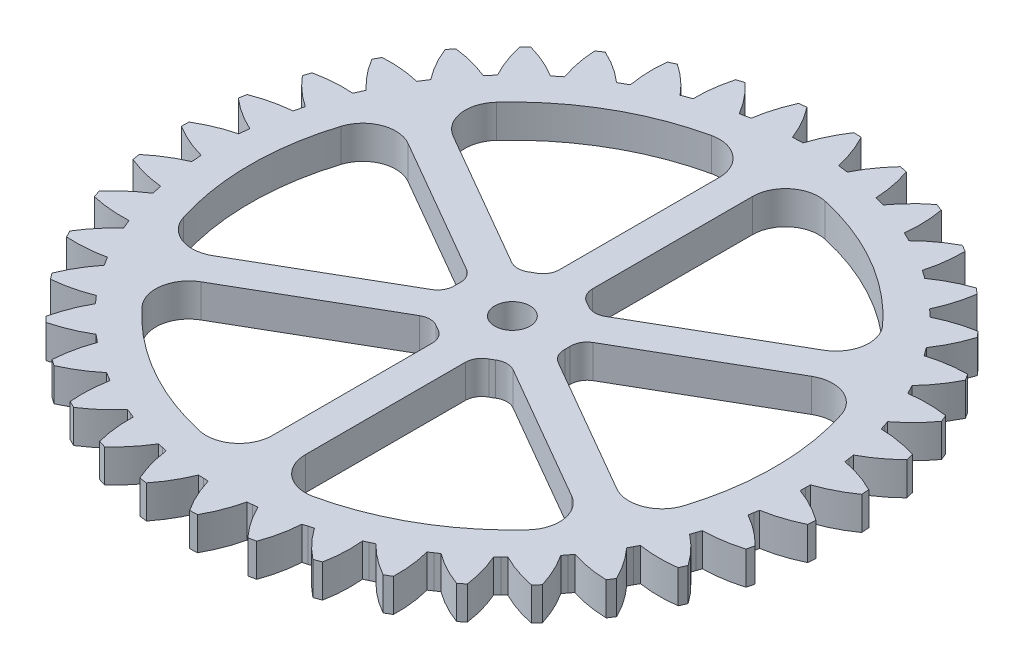
SolidWorks part; units mm, degrees
ref_plane "Front Plane" through (0, 0, 0) normal (0, 0, 1) x (1, 0, 0)
ref_plane "Top Plane" through (0, 0, 0) normal (0, 1, 0) x (1, 0, 0)
ref_plane "Right Plane" through (0, 0, 0) normal (1, 0, 0) x (0, 0, -1)
sketch "Sketch1" plane through (0, 0, 0) normal (0, 1, 0) x (1, 0, 0)
  circle A0 centre (0, 0) radius 28.4436 construction
  circle A1 centre (0, 0) radius 28.4436
sketch "Sketch2" plane through (0, 0, 0) normal (0, 1, 0) x (1, 0, 0)
  line L0 (26.7652, 0) -> (26.7681, 0.253)
  line L1 (26.7681, 0.253) -> (26.8366, 0.2754)
  line L2 (26.8366, 0.2754) -> (26.9069, 0.299)
  line L3 (26.9069, 0.299) -> (26.979, 0.3239)
  line L4 (26.979, 0.3239) -> (27.0527, 0.3502)
  line L5 (27.0527, 0.3502) -> (27.1281, 0.3778)
  line L6 (27.1281, 0.3778) -> (27.2051, 0.4068)
  line L7 (27.2051, 0.4068) -> (27.2839, 0.4372)
  line L8 (27.2839, 0.4372) -> (27.3642, 0.4691)
  line L9 (27.3642, 0.4691) -> (27.4462, 0.5025)
  line L10 (27.4462, 0.5025) -> (27.5297, 0.5374)
  line L11 (27.5297, 0.5374) -> (27.6148, 0.5738)
  line L12 (27.6148, 0.5738) -> (27.7015, 0.6119)
  line L13 (27.7015, 0.6119) -> (27.7897, 0.6515)
  line L14 (27.7897, 0.6515) -> (27.8793, 0.6928)
  line L15 (27.8793, 0.6928) -> (27.9705, 0.7358)
  line L16 (27.9705, 0.7358) -> (28.0631, 0.7804)
  line L17 (28.0631, 0.7804) -> (28.1572, 0.8269)
  line L18 (28.1572, 0.8269) -> (28.2526, 0.875)
  line L19 (28.2526, 0.875) -> (28.3495, 0.925)
  line L20 (28.3495, 0.925) -> (28.4477, 0.9768)
  line L21 (28.4477, 0.9768) -> (28.5472, 1.0304)
  line L22 (28.5472, 1.0304) -> (28.648, 1.0859)
  line L23 (28.648, 1.0859) -> (28.7502, 1.1433)
  line L24 (28.7502, 1.1433) -> (28.8536, 1.2026)
  line L25 (28.8536, 1.2026) -> (28.9582, 1.2639)
  line L26 (28.9582, 1.2639) -> (29.064, 1.3272)
  line L27 (29.064, 1.3272) -> (29.171, 1.3925)
  line L28 (29.171, 1.3925) -> (29.2792, 1.4598)
  line L29 (29.2792, 1.4598) -> (29.3885, 1.5292)
  line L30 (29.3885, 1.5292) -> (29.4988, 1.6007)
  line L31 (29.4988, 1.6007) -> (29.6103, 1.6743)
  line L32 (29.6103, 1.6743) -> (29.7227, 1.75)
  line L33 (29.7227, 1.75) -> (29.8362, 1.8279)
  line L34 (29.8362, 1.8279) -> (29.8433, 1.8329)
  line L35 (29.8433, 1.8329) -> (29.8442, 1.8335)
  line L36 (29.8442, 1.8335) -> (29.8447, 1.8338)
  line L37 (29.8447, 1.8338) -> (29.8449, 1.834)
  line L38 (29.8449, 1.834) -> (29.7947, 2.5211)
  line L39 (29.7947, 2.5211) -> (29.7945, 2.5212)
  line L40 (29.7945, 2.5212) -> (29.794, 2.5214)
  line L41 (29.794, 2.5214) -> (29.793, 2.5219)
  line L42 (29.793, 2.5219) -> (29.7853, 2.5258)
  line L43 (29.7853, 2.5258) -> (29.6617, 2.5864)
  line L44 (29.6617, 2.5864) -> (29.5394, 2.645)
  line L45 (29.5394, 2.645) -> (29.4185, 2.7016)
  line L46 (29.4185, 2.7016) -> (29.2989, 2.7563)
  line L47 (29.2989, 2.7563) -> (29.1807, 2.809)
  line L48 (29.1807, 2.809) -> (29.0639, 2.8599)
  line L49 (29.0639, 2.8599) -> (28.9485, 2.909)
  line L50 (28.9485, 2.909) -> (28.8346, 2.9562)
  line L51 (28.8346, 2.9562) -> (28.7222, 3.0017)
  line L52 (28.7222, 3.0017) -> (28.6113, 3.0454)
  line L53 (28.6113, 3.0454) -> (28.5019, 3.0873)
  line L54 (28.5019, 3.0873) -> (28.3941, 3.1276)
  line L55 (28.3941, 3.1276) -> (28.2878, 3.1662)
  line L56 (28.2878, 3.1662) -> (28.1831, 3.2032)
  line L57 (28.1831, 3.2032) -> (28.08, 3.2385)
  line L58 (28.08, 3.2385) -> (27.9786, 3.2723)
  line L59 (27.9786, 3.2723) -> (27.8788, 3.3046)
  line L60 (27.8788, 3.3046) -> (27.7807, 3.3353)
  line L61 (27.7807, 3.3353) -> (27.6842, 3.3646)
  line L62 (27.6842, 3.3646) -> (27.5895, 3.3924)
  line L63 (27.5895, 3.3924) -> (27.4965, 3.4188)
  line L64 (27.4965, 3.4188) -> (27.4052, 3.4439)
  line L65 (27.4052, 3.4439) -> (27.3157, 3.4676)
  line L66 (27.3157, 3.4676) -> (27.228, 3.49)
  line L67 (27.228, 3.49) -> (27.1421, 3.5111)
  line L68 (27.1421, 3.5111) -> (27.058, 3.531)
  line L69 (27.058, 3.531) -> (26.9757, 3.5496)
  line L70 (26.9757, 3.5496) -> (26.8952, 3.5671)
  line L71 (26.8952, 3.5671) -> (26.8166, 3.5835)
  line L72 (26.8166, 3.5835) -> (26.7398, 3.5987)
  line L73 (26.7398, 3.5987) -> (26.6649, 3.6129)
  line L74 (26.6649, 3.6129) -> (26.592, 3.6261)
  line L75 (26.592, 3.6261) -> (26.5209, 3.6382)
  line L76 (26.5209, 3.6382) -> (26.4813, 3.8882)
  line L77 (26.4813, 3.8882) -> (26.4186, 4.2934)
  line L78 (26.4186, 4.2934) -> (26.3809, 4.5437)
  line L79 (26.3809, 4.5437) -> (26.4449, 4.5767)
  line L80 (26.4449, 4.5767) -> (26.5105, 4.6113)
  line L81 (26.5105, 4.6113) -> (26.5776, 4.6475)
  line L82 (26.5776, 4.6475) -> (26.6462, 4.6852)
  line L83 (26.6462, 4.6852) -> (26.7162, 4.7245)
  line L84 (26.7162, 4.7245) -> (26.7876, 4.7655)
  line L85 (26.7876, 4.7655) -> (26.8604, 4.8082)
  line L86 (26.8604, 4.8082) -> (26.9346, 4.8526)
  line L87 (26.9346, 4.8526) -> (27.0101, 4.8986)
  line L88 (27.0101, 4.8986) -> (27.087, 4.9465)
  line L89 (27.087, 4.9465) -> (27.1652, 4.9961)
  line L90 (27.1652, 4.9961) -> (27.2446, 5.0476)
  line L91 (27.2446, 5.0476) -> (27.3253, 5.1009)
  line L92 (27.3253, 5.1009) -> (27.4072, 5.156)
  line L93 (27.4072, 5.156) -> (27.4903, 5.213)
  line L94 (27.4903, 5.213) -> (27.5745, 5.272)
  line L95 (27.5745, 5.272) -> (27.6599, 5.3329)
  line L96 (27.6599, 5.3329) -> (27.7464, 5.3957)
  line L97 (27.7464, 5.3957) -> (27.834, 5.4606)
  line L98 (27.834, 5.4606) -> (27.9226, 5.5274)
  line L99 (27.9226, 5.5274) -> (28.0122, 5.5963)
  line L100 (28.0122, 5.5963) -> (28.1029, 5.6673)
  line L101 (28.1029, 5.6673) -> (28.1945, 5.7403)
  line L102 (28.1945, 5.7403) -> (28.287, 5.8155)
  line L103 (28.287, 5.8155) -> (28.3804, 5.8928)
  line L104 (28.3804, 5.8928) -> (28.4748, 5.9722)
  line L105 (28.4748, 5.9722) -> (28.5699, 6.0538)
  line L106 (28.5699, 6.0538) -> (28.6659, 6.1376)
  line L107 (28.6659, 6.1376) -> (28.7626, 6.2237)
  line L108 (28.7626, 6.2237) -> (28.8601, 6.3119)
  line L109 (28.8601, 6.3119) -> (28.9583, 6.4024)
  line L110 (28.9583, 6.4024) -> (29.0571, 6.4952)
  line L111 (29.0571, 6.4952) -> (29.1566, 6.5903)
  line L112 (29.1566, 6.5903) -> (29.1629, 6.5963)
  line L113 (29.1629, 6.5963) -> (29.1637, 6.5971)
  line L114 (29.1637, 6.5971) -> (29.164, 6.5975)
  line L115 (29.164, 6.5975) -> (29.1642, 6.5977)
  line L116 (29.1642, 6.5977) -> (29.0045, 7.2678)
  line L117 (29.0045, 7.2678) -> (29.0042, 7.2679)
  line L118 (29.0042, 7.2679) -> (29.0037, 7.2681)
  line L119 (29.0037, 7.2681) -> (29.0027, 7.2684)
  line L120 (29.0027, 7.2684) -> (28.9944, 7.271)
  line L121 (28.9944, 7.271) -> (28.8627, 7.3109)
  line L122 (28.8627, 7.3109) -> (28.7326, 7.3491)
  line L123 (28.7326, 7.3491) -> (28.6041, 7.3856)
  line L124 (28.6041, 7.3856) -> (28.4773, 7.4204)
  line L125 (28.4773, 7.4204) -> (28.3522, 7.4536)
  line L126 (28.3522, 7.4536) -> (28.2287, 7.4851)
  line L127 (28.2287, 7.4851) -> (28.107, 7.515)
  line L128 (28.107, 7.515) -> (27.987, 7.5434)
  line L129 (27.987, 7.5434) -> (27.8688, 7.5702)
  line L130 (27.8688, 7.5702) -> (27.7523, 7.5955)
  line L131 (27.7523, 7.5955) -> (27.6376, 7.6194)
  line L132 (27.6376, 7.6194) -> (27.5247, 7.6418)
  line L133 (27.5247, 7.6418) -> (27.4136, 7.6629)
  line L134 (27.4136, 7.6629) -> (27.3043, 7.6826)
  line L135 (27.3043, 7.6826) -> (27.1969, 7.7009)
  line L136 (27.1969, 7.7009) -> (27.0914, 7.718)
  line L137 (27.0914, 7.718) -> (26.9877, 7.7338)
  line L138 (26.9877, 7.7338) -> (26.8859, 7.7484)
  line L139 (26.8859, 7.7484) -> (26.786, 7.7619)
  line L140 (26.786, 7.7619) -> (26.688, 7.7741)
  line L141 (26.688, 7.7741) -> (26.592, 7.7853)
  line L142 (26.592, 7.7853) -> (26.4979, 7.7954)
  line L143 (26.4979, 7.7954) -> (26.4058, 7.8044)
  line L144 (26.4058, 7.8044) -> (26.3156, 7.8125)
  line L145 (26.3156, 7.8125) -> (26.2274, 7.8195)
  line L146 (26.2274, 7.8195) -> (26.1412, 7.8256)
  line L147 (26.1412, 7.8256) -> (26.0569, 7.8309)
  line L148 (26.0569, 7.8309) -> (25.9747, 7.8352)
  line L149 (25.9747, 7.8352) -> (25.8945, 7.8388)
  line L150 (25.8945, 7.8388) -> (25.8163, 7.8415)
  line L151 (25.8163, 7.8415) -> (25.7401, 7.8435)
  line L152 (25.7401, 7.8435) -> (25.6659, 7.8448)
  line L153 (25.6659, 7.8448) -> (25.5938, 7.8454)
  line L154 (25.5938, 7.8454) -> (25.5147, 8.0857)
  line L155 (25.5147, 8.0857) -> (25.3878, 8.4757)
  line L156 (25.3878, 8.4757) -> (25.3104, 8.7166)
  line L157 (25.3104, 8.7166) -> (25.3683, 8.7595)
  line L158 (25.3683, 8.7595) -> (25.4275, 8.8042)
  line L159 (25.4275, 8.8042) -> (25.4879, 8.8506)
  line L160 (25.4879, 8.8506) -> (25.5496, 8.8989)
  line L161 (25.5496, 8.8989) -> (25.6123, 8.9489)
  line L162 (25.6123, 8.9489) -> (25.6763, 9.0008)
  line L163 (25.6763, 9.0008) -> (25.7413, 9.0546)
  line L164 (25.7413, 9.0546) -> (25.8074, 9.1103)
  line L165 (25.8074, 9.1103) -> (25.8746, 9.1679)
  line L166 (25.8746, 9.1679) -> (25.9428, 9.2275)
  line L167 (25.9428, 9.2275) -> (26.0119, 9.289)
  line L168 (26.0119, 9.289) -> (26.0821, 9.3525)
  line L169 (26.0821, 9.3525) -> (26.1532, 9.4181)
  line L170 (26.1532, 9.4181) -> (26.2252, 9.4856)
  line L171 (26.2252, 9.4856) -> (26.298, 9.5553)
  line L172 (26.298, 9.5553) -> (26.3717, 9.627)
  line L173 (26.3717, 9.627) -> (26.4463, 9.7008)
  line L174 (26.4463, 9.7008) -> (26.5215, 9.7767)
  line L175 (26.5215, 9.7767) -> (26.5976, 9.8547)
  line L176 (26.5976, 9.8547) -> (26.6743, 9.935)
  line L177 (26.6743, 9.935) -> (26.7518, 10.0173)
  line L178 (26.7518, 10.0173) -> (26.8299, 10.1019)
  line L179 (26.8299, 10.1019) -> (26.9086, 10.1887)
  line L180 (26.9086, 10.1887) -> (26.9878, 10.2777)
  line L181 (26.9878, 10.2777) -> (27.0677, 10.369)
  line L182 (27.0677, 10.369) -> (27.148, 10.4626)
  line L183 (27.148, 10.4626) -> (27.2288, 10.5584)
  line L184 (27.2288, 10.5584) -> (27.3101, 10.6565)
  line L185 (27.3101, 10.6565) -> (27.3918, 10.7569)
  line L186 (27.3918, 10.7569) -> (27.4738, 10.8597)
  line L187 (27.4738, 10.8597) -> (27.5562, 10.9648)
  line L188 (27.5562, 10.9648) -> (27.6389, 11.0722)
  line L189 (27.6389, 11.0722) -> (27.7219, 11.182)
  line L190 (27.7219, 11.182) -> (27.7271, 11.189)
  line L191 (27.7271, 11.189) -> (27.7277, 11.1899)
  line L192 (27.7277, 11.1899) -> (27.7281, 11.1903)
  line L193 (27.7281, 11.1903) -> (27.7282, 11.1905)
  line L194 (27.7282, 11.1905) -> (27.463, 11.8264)
  line L195 (27.463, 11.8264) -> (27.4628, 11.8264)
  line L196 (27.4628, 11.8264) -> (27.4622, 11.8265)
  line L197 (27.4622, 11.8265) -> (27.4612, 11.8266)
  line L198 (27.4612, 11.8266) -> (27.4526, 11.8278)
  line L199 (27.4526, 11.8278) -> (27.3162, 11.8462)
  line L200 (27.3162, 11.8462) -> (27.1816, 11.863)
  line L201 (27.1816, 11.863) -> (27.049, 11.8784)
  line L202 (27.049, 11.8784) -> (26.9182, 11.8924)
  line L203 (26.9182, 11.8924) -> (26.7894, 11.9051)
  line L204 (26.7894, 11.9051) -> (26.6625, 11.9164)
  line L205 (26.6625, 11.9164) -> (26.5375, 11.9264)
  line L206 (26.5375, 11.9264) -> (26.4145, 11.9351)
  line L207 (26.4145, 11.9351) -> (26.2935, 11.9426)
  line L208 (26.2935, 11.9426) -> (26.1745, 11.9489)
  line L209 (26.1745, 11.9489) -> (26.0574, 11.9541)
  line L210 (26.0574, 11.9541) -> (25.9424, 11.9581)
  line L211 (25.9424, 11.9581) -> (25.8294, 11.9611)
  line L212 (25.8294, 11.9611) -> (25.7184, 11.963)
  line L213 (25.7184, 11.963) -> (25.6094, 11.9639)
  line L214 (25.6094, 11.9639) -> (25.5025, 11.9638)
  line L215 (25.5025, 11.9638) -> (25.3976, 11.9628)
  line L216 (25.3976, 11.9628) -> (25.2948, 11.9609)
  line L217 (25.2948, 11.9609) -> (25.194, 11.9581)
  line L218 (25.194, 11.9581) -> (25.0954, 11.9545)
  line L219 (25.0954, 11.9545) -> (24.9988, 11.9501)
  line L220 (24.9988, 11.9501) -> (24.9043, 11.945)
  line L221 (24.9043, 11.945) -> (24.8119, 11.9391)
  line L222 (24.8119, 11.9391) -> (24.7216, 11.9326)
  line L223 (24.7216, 11.9326) -> (24.6334, 11.9254)
  line L224 (24.6334, 11.9254) -> (24.5473, 11.9176)
  line L225 (24.5473, 11.9176) -> (24.4633, 11.9093)
  line L226 (24.4633, 11.9093) -> (24.3815, 11.9004)
  line L227 (24.3815, 11.9004) -> (24.3017, 11.891)
  line L228 (24.3017, 11.891) -> (24.2241, 11.8812)
  line L229 (24.2241, 11.8812) -> (24.1486, 11.8709)
  line L230 (24.1486, 11.8709) -> (24.0752, 11.8603)
  line L231 (24.0752, 11.8603) -> (24.0039, 11.8493)
  line L232 (24.0039, 11.8493) -> (23.8872, 12.0739)
  line L233 (23.8872, 12.0739) -> (23.6994, 12.4384)
  line L234 (23.6994, 12.4384) -> (23.5844, 12.6638)
  line L235 (23.5844, 12.6638) -> (23.6347, 12.7155)
  line L236 (23.6347, 12.7155) -> (23.686, 12.769)
  line L237 (23.686, 12.769) -> (23.7381, 12.8246)
  line L238 (23.7381, 12.8246) -> (23.7912, 12.8821)
  line L239 (23.7912, 12.8821) -> (23.8452, 12.9416)
  line L240 (23.8452, 12.9416) -> (23.8999, 13.0031)
  line L241 (23.8999, 13.0031) -> (23.9555, 13.0666)
  line L242 (23.9555, 13.0666) -> (24.0118, 13.1322)
  line L243 (24.0118, 13.1322) -> (24.0689, 13.1998)
  line L244 (24.0689, 13.1998) -> (24.1266, 13.2695)
  line L245 (24.1266, 13.2695) -> (24.185, 13.3413)
  line L246 (24.185, 13.3413) -> (24.2441, 13.4153)
  line L247 (24.2441, 13.4153) -> (24.3037, 13.4914)
  line L248 (24.3037, 13.4914) -> (24.364, 13.5696)
  line L249 (24.364, 13.5696) -> (24.4247, 13.65)
  line L250 (24.4247, 13.65) -> (24.486, 13.7326)
  line L251 (24.486, 13.7326) -> (24.5477, 13.8174)
  line L252 (24.5477, 13.8174) -> (24.6098, 13.9044)
  line L253 (24.6098, 13.9044) -> (24.6723, 13.9937)
  line L254 (24.6723, 13.9937) -> (24.7352, 14.0852)
  line L255 (24.7352, 14.0852) -> (24.7984, 14.1789)
  line L256 (24.7984, 14.1789) -> (24.862, 14.2749)
  line L257 (24.862, 14.2749) -> (24.9257, 14.3732)
  line L258 (24.9257, 14.3732) -> (24.9897, 14.4738)
  line L259 (24.9897, 14.4738) -> (25.0538, 14.5767)
  line L260 (25.0538, 14.5767) -> (25.1181, 14.6819)
  line L261 (25.1181, 14.6819) -> (25.1825, 14.7895)
  line L262 (25.1825, 14.7895) -> (25.247, 14.8993)
  line L263 (25.247, 14.8993) -> (25.3115, 15.0116)
  line L264 (25.3115, 15.0116) -> (25.376, 15.1261)
  line L265 (25.376, 15.1261) -> (25.4405, 15.2431)
  line L266 (25.4405, 15.2431) -> (25.5049, 15.3624)
  line L267 (25.5049, 15.3624) -> (25.5692, 15.4841)
  line L268 (25.5692, 15.4841) -> (25.5732, 15.4918)
  line L269 (25.5732, 15.4918) -> (25.5737, 15.4928)
  line L270 (25.5737, 15.4928) -> (25.5739, 15.4933)
  line L271 (25.5739, 15.4933) -> (25.5741, 15.4935)
  line L272 (25.5741, 15.4935) -> (25.2103, 16.0786)
  line L273 (25.2103, 16.0786) -> (25.2101, 16.0786)
  line L274 (25.2101, 16.0786) -> (25.2095, 16.0786)
  line L275 (25.2095, 16.0786) -> (25.2084, 16.0786)
  line L276 (25.2084, 16.0786) -> (25.1998, 16.0784)
  line L277 (25.1998, 16.0784) -> (25.0622, 16.0746)
  line L278 (25.0622, 16.0746) -> (24.9267, 16.0696)
  line L279 (24.9267, 16.0696) -> (24.7933, 16.0636)
  line L280 (24.7933, 16.0636) -> (24.662, 16.0564)
  line L281 (24.662, 16.0564) -> (24.5328, 16.0482)
  line L282 (24.5328, 16.0482) -> (24.4057, 16.039)
  line L283 (24.4057, 16.039) -> (24.2808, 16.0288)
  line L284 (24.2808, 16.0288) -> (24.158, 16.0177)
  line L285 (24.158, 16.0177) -> (24.0373, 16.0057)
  line L286 (24.0373, 16.0057) -> (23.9188, 15.9929)
  line L287 (23.9188, 15.9929) -> (23.8024, 15.9792)
  line L288 (23.8024, 15.9792) -> (23.6882, 15.9647)
  line L289 (23.6882, 15.9647) -> (23.5762, 15.9495)
  line L290 (23.5762, 15.9495) -> (23.4663, 15.9336)
  line L291 (23.4663, 15.9336) -> (23.3586, 15.917)
  line L292 (23.3586, 15.917) -> (23.2531, 15.8998)
  line L293 (23.2531, 15.8998) -> (23.1497, 15.882)
  line L294 (23.1497, 15.882) -> (23.0486, 15.8636)
  line L295 (23.0486, 15.8636) -> (22.9496, 15.8447)
  line L296 (22.9496, 15.8447) -> (22.8528, 15.8253)
  line L297 (22.8528, 15.8253) -> (22.7581, 15.8055)
  line L298 (22.7581, 15.8055) -> (22.6657, 15.7852)
  line L299 (22.6657, 15.7852) -> (22.5754, 15.7646)
  line L300 (22.5754, 15.7646) -> (22.4873, 15.7437)
  line L301 (22.4873, 15.7437) -> (22.4014, 15.7225)
  line L302 (22.4014, 15.7225) -> (22.3177, 15.701)
  line L303 (22.3177, 15.701) -> (22.2362, 15.6792)
  line L304 (22.2362, 15.6792) -> (22.1568, 15.6574)
  line L305 (22.1568, 15.6574) -> (22.0796, 15.6353)
  line L306 (22.0796, 15.6353) -> (22.0045, 15.6131)
  line L307 (22.0045, 15.6131) -> (21.9316, 15.5909)
  line L308 (21.9316, 15.5909) -> (21.8609, 15.5686)
  line L309 (21.8609, 15.5686) -> (21.7923, 15.5464)
  line L310 (21.7923, 15.5464) -> (21.6411, 15.7493)
  line L311 (21.6411, 15.7493) -> (21.3973, 16.079)
  line L312 (21.3973, 16.079) -> (21.2475, 16.283)
  line L313 (21.2475, 16.283) -> (21.2889, 16.3421)
  line L314 (21.2889, 16.3421) -> (21.3309, 16.4032)
  line L315 (21.3309, 16.4032) -> (21.3735, 16.4664)
  line L316 (21.3735, 16.4664) -> (21.4167, 16.5316)
  line L317 (21.4167, 16.5316) -> (21.4604, 16.599)
  line L318 (21.4604, 16.599) -> (21.5046, 16.6685)
  line L319 (21.5046, 16.6685) -> (21.5492, 16.7401)
  line L320 (21.5492, 16.7401) -> (21.5943, 16.8139)
  line L321 (21.5943, 16.8139) -> (21.6398, 16.8898)
  line L322 (21.6398, 16.8898) -> (21.6856, 16.9679)
  line L323 (21.6856, 16.9679) -> (21.7317, 17.0481)
  line L324 (21.7317, 17.0481) -> (21.7782, 17.1306)
  line L325 (21.7782, 17.1306) -> (21.8248, 17.2153)
  line L326 (21.8248, 17.2153) -> (21.8717, 17.3022)
  line L327 (21.8717, 17.3022) -> (21.9188, 17.3913)
  line L328 (21.9188, 17.3913) -> (21.966, 17.4826)
  line L329 (21.966, 17.4826) -> (22.0133, 17.5762)
  line L330 (22.0133, 17.5762) -> (22.0607, 17.6721)
  line L331 (22.0607, 17.6721) -> (22.1081, 17.7702)
  line L332 (22.1081, 17.7702) -> (22.1555, 17.8706)
  line L333 (22.1555, 17.8706) -> (22.2029, 17.9732)
  line L334 (22.2029, 17.9732) -> (22.2501, 18.0782)
  line L335 (22.2501, 18.0782) -> (22.2973, 18.1854)
  line L336 (22.2973, 18.1854) -> (22.3443, 18.295)
  line L337 (22.3443, 18.295) -> (22.3911, 18.4069)
  line L338 (22.3911, 18.4069) -> (22.4377, 18.521)
  line L339 (22.4377, 18.521) -> (22.484, 18.6375)
  line L340 (22.484, 18.6375) -> (22.5301, 18.7563)
  line L341 (22.5301, 18.7563) -> (22.5757, 18.8774)
  line L342 (22.5757, 18.8774) -> (22.621, 19.0009)
  line L343 (22.621, 19.0009) -> (22.6659, 19.1267)
  line L344 (22.6659, 19.1267) -> (22.7103, 19.2548)
  line L345 (22.7103, 19.2548) -> (22.7542, 19.3852)
  line L346 (22.7542, 19.3852) -> (22.757, 19.3934)
  line L347 (22.757, 19.3934) -> (22.7573, 19.3945)
  line L348 (22.7573, 19.3945) -> (22.7575, 19.395)
  line L349 (22.7575, 19.395) -> (22.7576, 19.3952)
  line L350 (22.7576, 19.3952) -> (22.3047, 19.9144)
  line L351 (22.3047, 19.9144) -> (22.3044, 19.9144)
  line L352 (22.3044, 19.9144) -> (22.3039, 19.9143)
  line L353 (22.3039, 19.9143) -> (22.3028, 19.9141)
  line L354 (22.3028, 19.9141) -> (22.2943, 19.9125)
  line L355 (22.2943, 19.9125) -> (22.1591, 19.8867)
  line L356 (22.1591, 19.8867) -> (22.0261, 19.86)
  line L357 (22.0261, 19.86) -> (21.8954, 19.8327)
  line L358 (21.8954, 19.8327) -> (21.767, 19.8045)
  line L359 (21.767, 19.8045) -> (21.6408, 19.7757)
  line L360 (21.6408, 19.7757) -> (21.5168, 19.7463)
  line L361 (21.5168, 19.7463) -> (21.3951, 19.7162)
  line L362 (21.3951, 19.7162) -> (21.2757, 19.6855)
  line L363 (21.2757, 19.6855) -> (21.1585, 19.6543)
  line L364 (21.1585, 19.6543) -> (21.0436, 19.6226)
  line L365 (21.0436, 19.6226) -> (20.9309, 19.5904)
  line L366 (20.9309, 19.5904) -> (20.8205, 19.5579)
  line L367 (20.8205, 19.5579) -> (20.7124, 19.5249)
  line L368 (20.7124, 19.5249) -> (20.6065, 19.4915)
  line L369 (20.6065, 19.4915) -> (20.5029, 19.4579)
  line L370 (20.5029, 19.4579) -> (20.4015, 19.4239)
  line L371 (20.4015, 19.4239) -> (20.3023, 19.3898)
  line L372 (20.3023, 19.3898) -> (20.2054, 19.3554)
  line L373 (20.2054, 19.3554) -> (20.1107, 19.3209)
  line L374 (20.1107, 19.3209) -> (20.0183, 19.2862)
  line L375 (20.0183, 19.2862) -> (19.928, 19.2515)
  line L376 (19.928, 19.2515) -> (19.84, 19.2167)
  line L377 (19.84, 19.2167) -> (19.7543, 19.1818)
  line L378 (19.7543, 19.1818) -> (19.6707, 19.147)
  line L379 (19.6707, 19.147) -> (19.5893, 19.1123)
  line L380 (19.5893, 19.1123) -> (19.5101, 19.0777)
  line L381 (19.5101, 19.0777) -> (19.4331, 19.0431)
  line L382 (19.4331, 19.0431) -> (19.3582, 19.0088)
  line L383 (19.3582, 19.0088) -> (19.2856, 18.9746)
  line L384 (19.2856, 18.9746) -> (19.215, 18.9407)
  line L385 (19.215, 18.9407) -> (19.1467, 18.9071)
  line L386 (19.1467, 18.9071) -> (19.0804, 18.8738)
  line L387 (19.0804, 18.8738) -> (19.0163, 18.8408)
  line L388 (19.0163, 18.8408) -> (18.8345, 19.0168)
  line L389 (18.8345, 19.0168) -> (18.5409, 19.3031)
  line L390 (18.5409, 19.3031) -> (18.3604, 19.4805)
  line L391 (18.3604, 19.4805) -> (18.3918, 19.5454)
  line L392 (18.3918, 19.5454) -> (18.4234, 19.6125)
  line L393 (18.4234, 19.6125) -> (18.4554, 19.6817)
  line L394 (18.4554, 19.6817) -> (18.4875, 19.753)
  line L395 (18.4875, 19.753) -> (18.5198, 19.8265)
  line L396 (18.5198, 19.8265) -> (18.5523, 19.9022)
  line L397 (18.5523, 19.9022) -> (18.5849, 19.9801)
  line L398 (18.5849, 19.9801) -> (18.6175, 20.0601)
  line L399 (18.6175, 20.0601) -> (18.6502, 20.1423)
  line L400 (18.6502, 20.1423) -> (18.6829, 20.2268)
  line L401 (18.6829, 20.2268) -> (18.7156, 20.3134)
  line L402 (18.7156, 20.3134) -> (18.7482, 20.4022)
  line L403 (18.7482, 20.4022) -> (18.7807, 20.4933)
  line L404 (18.7807, 20.4933) -> (18.813, 20.5866)
  line L405 (18.813, 20.5866) -> (18.8452, 20.6821)
  line L406 (18.8452, 20.6821) -> (18.8771, 20.7798)
  line L407 (18.8771, 20.7798) -> (18.9088, 20.8798)
  line L408 (18.9088, 20.8798) -> (18.9402, 20.982)
  line L409 (18.9402, 20.982) -> (18.9713, 21.0865)
  line L410 (18.9713, 21.0865) -> (19.0019, 21.1931)
  line L411 (19.0019, 21.1931) -> (19.0322, 21.3021)
  line L412 (19.0322, 21.3021) -> (19.0621, 21.4133)
  line L413 (19.0621, 21.4133) -> (19.0914, 21.5267)
  line L414 (19.0914, 21.5267) -> (19.1202, 21.6424)
  line L415 (19.1202, 21.6424) -> (19.1485, 21.7603)
  line L416 (19.1485, 21.7603) -> (19.1762, 21.8804)
  line L417 (19.1762, 21.8804) -> (19.2032, 22.0028)
  line L418 (19.2032, 22.0028) -> (19.2296, 22.1275)
  line L419 (19.2296, 22.1275) -> (19.2552, 22.2544)
  line L420 (19.2552, 22.2544) -> (19.2801, 22.3835)
  line L421 (19.2801, 22.3835) -> (19.3042, 22.5148)
  line L422 (19.3042, 22.5148) -> (19.3275, 22.6484)
  line L423 (19.3275, 22.6484) -> (19.35, 22.7842)
  line L424 (19.35, 22.7842) -> (19.3513, 22.7928)
  line L425 (19.3513, 22.7928) -> (19.3515, 22.7938)
  line L426 (19.3515, 22.7938) -> (19.3516, 22.7944)
  line L427 (19.3516, 22.7944) -> (19.3516, 22.7946)
  line L428 (19.3516, 22.7946) -> (18.8213, 23.2344)
  line L429 (18.8213, 23.2344) -> (18.8211, 23.2344)
  line L430 (18.8211, 23.2344) -> (18.8206, 23.2342)
  line L431 (18.8206, 23.2342) -> (18.8195, 23.2338)
  line L432 (18.8195, 23.2338) -> (18.8114, 23.2309)
  line L433 (18.8114, 23.2309) -> (18.6821, 23.1837)
  line L434 (18.6821, 23.1837) -> (18.5551, 23.1361)
  line L435 (18.5551, 23.1361) -> (18.4305, 23.0881)
  line L436 (18.4305, 23.0881) -> (18.3082, 23.0397)
  line L437 (18.3082, 23.0397) -> (18.1883, 22.9911)
  line L438 (18.1883, 22.9911) -> (18.0707, 22.9421)
  line L439 (18.0707, 22.9421) -> (17.9554, 22.8929)
  line L440 (17.9554, 22.8929) -> (17.8424, 22.8435)
  line L441 (17.8424, 22.8435) -> (17.7317, 22.7939)
  line L442 (17.7317, 22.7939) -> (17.6234, 22.7441)
  line L443 (17.6234, 22.7441) -> (17.5174, 22.6943)
  line L444 (17.5174, 22.6943) -> (17.4136, 22.6444)
  line L445 (17.4136, 22.6444) -> (17.3122, 22.5945)
  line L446 (17.3122, 22.5945) -> (17.213, 22.5446)
  line L447 (17.213, 22.5446) -> (17.1161, 22.4948)
  line L448 (17.1161, 22.4948) -> (17.0214, 22.445)
  line L449 (17.0214, 22.445) -> (16.9291, 22.3954)
  line L450 (16.9291, 22.3954) -> (16.8389, 22.3459)
  line L451 (16.8389, 22.3459) -> (16.751, 22.2967)
  line L452 (16.751, 22.2967) -> (16.6653, 22.2476)
  line L453 (16.6653, 22.2476) -> (16.5818, 22.1988)
  line L454 (16.5818, 22.1988) -> (16.5006, 22.1504)
  line L455 (16.5006, 22.1504) -> (16.4215, 22.1022)
  line L456 (16.4215, 22.1022) -> (16.3445, 22.0545)
  line L457 (16.3445, 22.0545) -> (16.2698, 22.0071)
  line L458 (16.2698, 22.0071) -> (16.1972, 21.9602)
  line L459 (16.1972, 21.9602) -> (16.1267, 21.9138)
  line L460 (16.1267, 21.9138) -> (16.0583, 21.8679)
  line L461 (16.0583, 21.8679) -> (15.9921, 21.8225)
  line L462 (15.9921, 21.8225) -> (15.9279, 21.7778)
  line L463 (15.9279, 21.7778) -> (15.8658, 21.7336)
  line L464 (15.8658, 21.7336) -> (15.8058, 21.6901)
  line L465 (15.8058, 21.6901) -> (15.7478, 21.6472)
  line L466 (15.7478, 21.6472) -> (15.5401, 21.7918)
  line L467 (15.5401, 21.7918) -> (15.2044, 22.0273)
  line L468 (15.2044, 22.0273) -> (14.9978, 22.1735)
  line L469 (14.9978, 22.1735) -> (15.0183, 22.2426)
  line L470 (15.0183, 22.2426) -> (15.0388, 22.3138)
  line L471 (15.0388, 22.3138) -> (15.0592, 22.3873)
  line L472 (15.0592, 22.3873) -> (15.0795, 22.4628)
  line L473 (15.0795, 22.4628) -> (15.0996, 22.5406)
  line L474 (15.0996, 22.5406) -> (15.1195, 22.6205)
  line L475 (15.1195, 22.6205) -> (15.1392, 22.7025)
  line L476 (15.1392, 22.7025) -> (15.1586, 22.7868)
  line L477 (15.1586, 22.7868) -> (15.1777, 22.8732)
  line L478 (15.1777, 22.8732) -> (15.1964, 22.9618)
  line L479 (15.1964, 22.9618) -> (15.2148, 23.0525)
  line L480 (15.2148, 23.0525) -> (15.2327, 23.1454)
  line L481 (15.2327, 23.1454) -> (15.2501, 23.2405)
  line L482 (15.2501, 23.2405) -> (15.2671, 23.3378)
  line L483 (15.2671, 23.3378) -> (15.2835, 23.4372)
  line L484 (15.2835, 23.4372) -> (15.2994, 23.5388)
  line L485 (15.2994, 23.5388) -> (15.3146, 23.6426)
  line L486 (15.3146, 23.6426) -> (15.3292, 23.7485)
  line L487 (15.3292, 23.7485) -> (15.3431, 23.8566)
  line L488 (15.3431, 23.8566) -> (15.3563, 23.9668)
  line L489 (15.3563, 23.9668) -> (15.3687, 24.0792)
  line L490 (15.3687, 24.0792) -> (15.3803, 24.1937)
  line L491 (15.3803, 24.1937) -> (15.3911, 24.3104)
  line L492 (15.3911, 24.3104) -> (15.401, 24.4292)
  line L493 (15.401, 24.4292) -> (15.4099, 24.5501)
  line L494 (15.4099, 24.5501) -> (15.418, 24.6732)
  line L495 (15.418, 24.6732) -> (15.425, 24.7983)
  line L496 (15.425, 24.7983) -> (15.4311, 24.9256)
  line L497 (15.4311, 24.9256) -> (15.436, 25.0549)
  line L498 (15.436, 25.0549) -> (15.4399, 25.1864)
  line L499 (15.4399, 25.1864) -> (15.4426, 25.3199)
  line L500 (15.4426, 25.3199) -> (15.4442, 25.4555)
  line L501 (15.4442, 25.4555) -> (15.4445, 25.5931)
  line L502 (15.4445, 25.5931) -> (15.4445, 25.6018)
  line L503 (15.4445, 25.6018) -> (15.4445, 25.6029)
  line L504 (15.4445, 25.6029) -> (15.4445, 25.6034)
  line L505 (15.4445, 25.6034) -> (15.4445, 25.6037)
  line L506 (15.4445, 25.6037) -> (14.8505, 25.9527)
  line L507 (14.8505, 25.9527) -> (14.8503, 25.9526)
  line L508 (14.8503, 25.9526) -> (14.8498, 25.9523)
  line L509 (14.8498, 25.9523) -> (14.8489, 25.9518)
  line L510 (14.8489, 25.9518) -> (14.8413, 25.9476)
  line L511 (14.8413, 25.9476) -> (14.7212, 25.8803)
  line L512 (14.7212, 25.8803) -> (14.6035, 25.8129)
  line L513 (14.6035, 25.8129) -> (14.4882, 25.7456)
  line L514 (14.4882, 25.7456) -> (14.3753, 25.6782)
  line L515 (14.3753, 25.6782) -> (14.2647, 25.6109)
  line L516 (14.2647, 25.6109) -> (14.1565, 25.5437)
  line L517 (14.1565, 25.5437) -> (14.0506, 25.4767)
  line L518 (14.0506, 25.4767) -> (13.947, 25.4098)
  line L519 (13.947, 25.4098) -> (13.8457, 25.3431)
  line L520 (13.8457, 25.3431) -> (13.7468, 25.2766)
  line L521 (13.7468, 25.2766) -> (13.6501, 25.2104)
  line L522 (13.6501, 25.2104) -> (13.5557, 25.1445)
  line L523 (13.5557, 25.1445) -> (13.4636, 25.079)
  line L524 (13.4636, 25.079) -> (13.3737, 25.0138)
  line L525 (13.3737, 25.0138) -> (13.286, 24.9491)
  line L526 (13.286, 24.9491) -> (13.2006, 24.8848)
  line L527 (13.2006, 24.8848) -> (13.1174, 24.821)
  line L528 (13.1174, 24.821) -> (13.0363, 24.7577)
  line L529 (13.0363, 24.7577) -> (12.9574, 24.695)
  line L530 (12.9574, 24.695) -> (12.8807, 24.6328)
  line L531 (12.8807, 24.6328) -> (12.8062, 24.5713)
  line L532 (12.8062, 24.5713) -> (12.7337, 24.5104)
  line L533 (12.7337, 24.5104) -> (12.6634, 24.4502)
  line L534 (12.6634, 24.4502) -> (12.5951, 24.3907)
  line L535 (12.5951, 24.3907) -> (12.5289, 24.332)
  line L536 (12.5289, 24.332) -> (12.4648, 24.2741)
  line L537 (12.4648, 24.2741) -> (12.4026, 24.2169)
  line L538 (12.4026, 24.2169) -> (12.3425, 24.1607)
  line L539 (12.3425, 24.1607) -> (12.2844, 24.1053)
  line L540 (12.2844, 24.1053) -> (12.2282, 24.0508)
  line L541 (12.2282, 24.0508) -> (12.174, 23.9972)
  line L542 (12.174, 23.9972) -> (12.1218, 23.9446)
  line L543 (12.1218, 23.9446) -> (12.0714, 23.893)
  line L544 (12.0714, 23.893) -> (11.8432, 24.0024)
  line L545 (11.8432, 24.0024) -> (11.474, 24.181)
  line L546 (11.474, 24.181) -> (11.2467, 24.2921)
  line L547 (11.2467, 24.2921) -> (11.2559, 24.3636)
  line L548 (11.2559, 24.3636) -> (11.2647, 24.4373)
  line L549 (11.2647, 24.4373) -> (11.273, 24.513)
  line L550 (11.273, 24.513) -> (11.2809, 24.5909)
  line L551 (11.2809, 24.5909) -> (11.2883, 24.6708)
  line L552 (11.2883, 24.6708) -> (11.2951, 24.7529)
  line L553 (11.2951, 24.7529) -> (11.3014, 24.8371)
  line L554 (11.3014, 24.8371) -> (11.307, 24.9233)
  line L555 (11.307, 24.9233) -> (11.312, 25.0117)
  line L556 (11.312, 25.0117) -> (11.3163, 25.1021)
  line L557 (11.3163, 25.1021) -> (11.3198, 25.1946)
  line L558 (11.3198, 25.1946) -> (11.3226, 25.2892)
  line L559 (11.3226, 25.2892) -> (11.3246, 25.3859)
  line L560 (11.3246, 25.3859) -> (11.3257, 25.4846)
  line L561 (11.3257, 25.4846) -> (11.326, 25.5854)
  line L562 (11.326, 25.5854) -> (11.3253, 25.6882)
  line L563 (11.3253, 25.6882) -> (11.3237, 25.7931)
  line L564 (11.3237, 25.7931) -> (11.3211, 25.9)
  line L565 (11.3211, 25.9) -> (11.3175, 26.0089)
  line L566 (11.3175, 26.0089) -> (11.3128, 26.1198)
  line L567 (11.3128, 26.1198) -> (11.3071, 26.2327)
  line L568 (11.3071, 26.2327) -> (11.3002, 26.3476)
  line L569 (11.3002, 26.3476) -> (11.2921, 26.4645)
  line L570 (11.2921, 26.4645) -> (11.2828, 26.5833)
  line L571 (11.2828, 26.5833) -> (11.2723, 26.7041)
  line L572 (11.2723, 26.7041) -> (11.2605, 26.8269)
  line L573 (11.2605, 26.8269) -> (11.2473, 26.9515)
  line L574 (11.2473, 26.9515) -> (11.2329, 27.0781)
  line L575 (11.2329, 27.0781) -> (11.217, 27.2066)
  line L576 (11.217, 27.2066) -> (11.1998, 27.337)
  line L577 (11.1998, 27.337) -> (11.1811, 27.4692)
  line L578 (11.1811, 27.4692) -> (11.1609, 27.6033)
  line L579 (11.1609, 27.6033) -> (11.1391, 27.7392)
  line L580 (11.1391, 27.7392) -> (11.1377, 27.7477)
  line L581 (11.1377, 27.7477) -> (11.1375, 27.7488)
  line L582 (11.1375, 27.7488) -> (11.1374, 27.7493)
  line L583 (11.1374, 27.7493) -> (11.1374, 27.7496)
  line L584 (11.1374, 27.7496) -> (10.4951, 27.9988)
  line L585 (10.4951, 27.9988) -> (10.4949, 27.9987)
  line L586 (10.4949, 27.9987) -> (10.4945, 27.9983)
  line L587 (10.4945, 27.9983) -> (10.4936, 27.9977)
  line L588 (10.4936, 27.9977) -> (10.4868, 27.9923)
  line L589 (10.4868, 27.9923) -> (10.3791, 27.9066)
  line L590 (10.3791, 27.9066) -> (10.2737, 27.8213)
  line L591 (10.2737, 27.8213) -> (10.1707, 27.7363)
  line L592 (10.1707, 27.7363) -> (10.0701, 27.6517)
  line L593 (10.0701, 27.6517) -> (9.9717, 27.5675)
  line L594 (9.9717, 27.5675) -> (9.8756, 27.4838)
  line L595 (9.8756, 27.4838) -> (9.7819, 27.4006)
  line L596 (9.7819, 27.4006) -> (9.6904, 27.318)
  line L597 (9.6904, 27.318) -> (9.6011, 27.2359)
  line L598 (9.6011, 27.2359) -> (9.5141, 27.1544)
  line L599 (9.5141, 27.1544) -> (9.4293, 27.0736)
  line L600 (9.4293, 27.0736) -> (9.3467, 26.9934)
  line L601 (9.3467, 26.9934) -> (9.2663, 26.9139)
  line L602 (9.2663, 26.9139) -> (9.188, 26.8352)
  line L603 (9.188, 26.8352) -> (9.1119, 26.7572)
  line L604 (9.1119, 26.7572) -> (9.0378, 26.6801)
  line L605 (9.0378, 26.6801) -> (8.9659, 26.6037)
  line L606 (8.9659, 26.6037) -> (8.8961, 26.5283)
  line L607 (8.8961, 26.5283) -> (8.8283, 26.4537)
  line L608 (8.8283, 26.4537) -> (8.7625, 26.38)
  line L609 (8.7625, 26.38) -> (8.6988, 26.3074)
  line L610 (8.6988, 26.3074) -> (8.6371, 26.2356)
  line L611 (8.6371, 26.2356) -> (8.5773, 26.1649)
  line L612 (8.5773, 26.1649) -> (8.5194, 26.0953)
  line L613 (8.5194, 26.0953) -> (8.4635, 26.0267)
  line L614 (8.4635, 26.0267) -> (8.4095, 25.9592)
  line L615 (8.4095, 25.9592) -> (8.3573, 25.8929)
  line L616 (8.3573, 25.8929) -> (8.307, 25.8277)
  line L617 (8.307, 25.8277) -> (8.2586, 25.7637)
  line L618 (8.2586, 25.7637) -> (8.2119, 25.7009)
  line L619 (8.2119, 25.7009) -> (8.167, 25.6393)
  line L620 (8.167, 25.6393) -> (8.1238, 25.579)
  line L621 (8.1238, 25.579) -> (8.0823, 25.52)
  line L622 (8.0823, 25.52) -> (7.8395, 25.5914)
  line L623 (7.8395, 25.5914) -> (7.4466, 25.7085)
  line L624 (7.4466, 25.7085) -> (7.2043, 25.7816)
  line L625 (7.2043, 25.7816) -> (7.2019, 25.8537)
  line L626 (7.2019, 25.8537) -> (7.1988, 25.9278)
  line L627 (7.1988, 25.9278) -> (7.1949, 26.0039)
  line L628 (7.1949, 26.0039) -> (7.1902, 26.082)
  line L629 (7.1902, 26.082) -> (7.1846, 26.1621)
  line L630 (7.1846, 26.1621) -> (7.1782, 26.2442)
  line L631 (7.1782, 26.2442) -> (7.1709, 26.3283)
  line L632 (7.1709, 26.3283) -> (7.1626, 26.4143)
  line L633 (7.1626, 26.4143) -> (7.1534, 26.5023)
  line L634 (7.1534, 26.5023) -> (7.1431, 26.5923)
  line L635 (7.1431, 26.5923) -> (7.1318, 26.6842)
  line L636 (7.1318, 26.6842) -> (7.1193, 26.778)
  line L637 (7.1193, 26.778) -> (7.1058, 26.8737)
  line L638 (7.1058, 26.8737) -> (7.0911, 26.9714)
  line L639 (7.0911, 26.9714) -> (7.0752, 27.0709)
  line L640 (7.0752, 27.0709) -> (7.058, 27.1723)
  line L641 (7.058, 27.1723) -> (7.0396, 27.2755)
  line L642 (7.0396, 27.2755) -> (7.0199, 27.3806)
  line L643 (7.0199, 27.3806) -> (6.9989, 27.4875)
  line L644 (6.9989, 27.4875) -> (6.9764, 27.5962)
  line L645 (6.9764, 27.5962) -> (6.9526, 27.7068)
  line L646 (6.9526, 27.7068) -> (6.9274, 27.8191)
  line L647 (6.9274, 27.8191) -> (6.9006, 27.9332)
  line L648 (6.9006, 27.9332) -> (6.8724, 28.049)
  line L649 (6.8724, 28.049) -> (6.8426, 28.1665)
  line L650 (6.8426, 28.1665) -> (6.8113, 28.2858)
  line L651 (6.8113, 28.2858) -> (6.7784, 28.4067)
  line L652 (6.7784, 28.4067) -> (6.7438, 28.5293)
  line L653 (6.7438, 28.5293) -> (6.7075, 28.6536)
  line L654 (6.7075, 28.6536) -> (6.6696, 28.7795)
  line L655 (6.6696, 28.7795) -> (6.6299, 28.907)
  line L656 (6.6299, 28.907) -> (6.5884, 29.0361)
  line L657 (6.5884, 29.0361) -> (6.5452, 29.1668)
  line L658 (6.5452, 29.1668) -> (6.5424, 29.175)
  line L659 (6.5424, 29.175) -> (6.5421, 29.176)
  line L660 (6.5421, 29.176) -> (6.5419, 29.1766)
  line L661 (6.5419, 29.1766) -> (6.5418, 29.1768)
  line L662 (6.5418, 29.1768) -> (5.8679, 29.3198)
  line L663 (5.8679, 29.3198) -> (5.8677, 29.3196)
  line L664 (5.8677, 29.3196) -> (5.8673, 29.3192)
  line L665 (5.8673, 29.3192) -> (5.8666, 29.3184)
  line L666 (5.8666, 29.3184) -> (5.8607, 29.312)
  line L667 (5.8607, 29.312) -> (5.7682, 29.2102)
  line L668 (5.7682, 29.2102) -> (5.6779, 29.109)
  line L669 (5.6779, 29.109) -> (5.5898, 29.0086)
  line L670 (5.5898, 29.0086) -> (5.504, 28.9089)
  line L671 (5.504, 28.9089) -> (5.4204, 28.8101)
  line L672 (5.4204, 28.8101) -> (5.339, 28.7121)
  line L673 (5.339, 28.7121) -> (5.2598, 28.6149)
  line L674 (5.2598, 28.6149) -> (5.1828, 28.5187)
  line L675 (5.1828, 28.5187) -> (5.1078, 28.4233)
  line L676 (5.1078, 28.4233) -> (5.035, 28.3289)
  line L677 (5.035, 28.3289) -> (4.9643, 28.2355)
  line L678 (4.9643, 28.2355) -> (4.8956, 28.1432)
  line L679 (4.8956, 28.1432) -> (4.829, 28.0518)
  line L680 (4.829, 28.0518) -> (4.7643, 27.9616)
  line L681 (4.7643, 27.9616) -> (4.7017, 27.8724)
  line L682 (4.7017, 27.8724) -> (4.641, 27.7844)
  line L683 (4.641, 27.7844) -> (4.5823, 27.6975)
  line L684 (4.5823, 27.6975) -> (4.5254, 27.6118)
  line L685 (4.5254, 27.6118) -> (4.4705, 27.5273)
  line L686 (4.4705, 27.5273) -> (4.4174, 27.444)
  line L687 (4.4174, 27.444) -> (4.3662, 27.3621)
  line L688 (4.3662, 27.3621) -> (4.3167, 27.2814)
  line L689 (4.3167, 27.2814) -> (4.2691, 27.202)
  line L690 (4.2691, 27.202) -> (4.2231, 27.124)
  line L691 (4.2231, 27.124) -> (4.1789, 27.0473)
  line L692 (4.1789, 27.0473) -> (4.1364, 26.972)
  line L693 (4.1364, 26.972) -> (4.0956, 26.8982)
  line L694 (4.0956, 26.8982) -> (4.0564, 26.8257)
  line L695 (4.0564, 26.8257) -> (4.0188, 26.7548)
  line L696 (4.0188, 26.7548) -> (3.9828, 26.6853)
  line L697 (3.9828, 26.6853) -> (3.9484, 26.6174)
  line L698 (3.9484, 26.6174) -> (3.9154, 26.5509)
  line L699 (3.9154, 26.5509) -> (3.884, 26.486)
  line L700 (3.884, 26.486) -> (3.6329, 26.5175)
  line L701 (3.6329, 26.5175) -> (3.2262, 26.5701)
  line L702 (3.2262, 26.5701) -> (2.9753, 26.6034)
  line L703 (2.9753, 26.6034) -> (2.9614, 26.6742)
  line L704 (2.9614, 26.6742) -> (2.9464, 26.7468)
  line L705 (2.9464, 26.7468) -> (2.9304, 26.8213)
  line L706 (2.9304, 26.8213) -> (2.9132, 26.8976)
  line L707 (2.9132, 26.8976) -> (2.8949, 26.9758)
  line L708 (2.8949, 26.9758) -> (2.8754, 27.0558)
  line L709 (2.8754, 27.0558) -> (2.8547, 27.1376)
  line L710 (2.8547, 27.1376) -> (2.8327, 27.2212)
  line L711 (2.8327, 27.2212) -> (2.8095, 27.3066)
  line L712 (2.8095, 27.3066) -> (2.7849, 27.3938)
  line L713 (2.7849, 27.3938) -> (2.7589, 27.4826)
  line L714 (2.7589, 27.4826) -> (2.7316, 27.5733)
  line L715 (2.7316, 27.5733) -> (2.7029, 27.6656)
  line L716 (2.7029, 27.6656) -> (2.6727, 27.7596)
  line L717 (2.6727, 27.7596) -> (2.6411, 27.8552)
  line L718 (2.6411, 27.8552) -> (2.6079, 27.9526)
  line L719 (2.6079, 27.9526) -> (2.5731, 28.0515)
  line L720 (2.5731, 28.0515) -> (2.5368, 28.1521)
  line L721 (2.5368, 28.1521) -> (2.4989, 28.2543)
  line L722 (2.4989, 28.2543) -> (2.4593, 28.358)
  line L723 (2.4593, 28.358) -> (2.4181, 28.4633)
  line L724 (2.4181, 28.4633) -> (2.3752, 28.5701)
  line L725 (2.3752, 28.5701) -> (2.3305, 28.6784)
  line L726 (2.3305, 28.6784) -> (2.284, 28.7882)
  line L727 (2.284, 28.7882) -> (2.2358, 28.8994)
  line L728 (2.2358, 28.8994) -> (2.1857, 29.0121)
  line L729 (2.1857, 29.0121) -> (2.1338, 29.1262)
  line L730 (2.1338, 29.1262) -> (2.08, 29.2417)
  line L731 (2.08, 29.2417) -> (2.0243, 29.3585)
  line L732 (2.0243, 29.3585) -> (1.9667, 29.4767)
  line L733 (1.9667, 29.4767) -> (1.907, 29.5962)
  line L734 (1.907, 29.5962) -> (1.8454, 29.717)
  line L735 (1.8454, 29.717) -> (1.7818, 29.839)
  line L736 (1.7818, 29.839) -> (1.7777, 29.8467)
  line L737 (1.7777, 29.8467) -> (1.7772, 29.8476)
  line L738 (1.7772, 29.8476) -> (1.7769, 29.8481)
  line L739 (1.7769, 29.8481) -> (1.7768, 29.8484)
  line L740 (1.7768, 29.8484) -> (1.0887, 29.8814)
  line L741 (1.0887, 29.8814) -> (1.0885, 29.8812)
  line L742 (1.0885, 29.8812) -> (1.0882, 29.8807)
  line L743 (1.0882, 29.8807) -> (1.0876, 29.8798)
  line L744 (1.0876, 29.8798) -> (1.0829, 29.8726)
  line L745 (1.0829, 29.8726) -> (1.0078, 29.7572)
  line L746 (1.0078, 29.7572) -> (0.9349, 29.6428)
  line L747 (0.9349, 29.6428) -> (0.8641, 29.5296)
  line L748 (0.8641, 29.5296) -> (0.7954, 29.4175)
  line L749 (0.7954, 29.4175) -> (0.7288, 29.3065)
  line L750 (0.7288, 29.3065) -> (0.6642, 29.1967)
  line L751 (0.6642, 29.1967) -> (0.6016, 29.0881)
  line L752 (0.6016, 29.0881) -> (0.5409, 28.9807)
  line L753 (0.5409, 28.9807) -> (0.4823, 28.8746)
  line L754 (0.4823, 28.8746) -> (0.4255, 28.7698)
  line L755 (0.4255, 28.7698) -> (0.3707, 28.6662)
  line L756 (0.3707, 28.6662) -> (0.3177, 28.564)
  line L757 (0.3177, 28.564) -> (0.2666, 28.4632)
  line L758 (0.2666, 28.4632) -> (0.2173, 28.3637)
  line L759 (0.2173, 28.3637) -> (0.1698, 28.2657)
  line L760 (0.1698, 28.2657) -> (0.124, 28.169)
  line L761 (0.124, 28.169) -> (0.0799, 28.0738)
  line L762 (0.0799, 28.0738) -> (0.0376, 27.9801)
  line L763 (0.0376, 27.9801) -> (-0.0031, 27.8879)
  line L764 (-0.0031, 27.8879) -> (-0.0421, 27.7973)
  line L765 (-0.0421, 27.7973) -> (-0.0796, 27.7081)
  line L766 (-0.0796, 27.7081) -> (-0.1154, 27.6205)
  line L767 (-0.1154, 27.6205) -> (-0.1497, 27.5345)
  line L768 (-0.1497, 27.5345) -> (-0.1825, 27.4502)
  line L769 (-0.1825, 27.4502) -> (-0.2139, 27.3674)
  line L770 (-0.2139, 27.3674) -> (-0.2437, 27.2863)
  line L771 (-0.2437, 27.2863) -> (-0.2722, 27.2068)
  line L772 (-0.2722, 27.2068) -> (-0.2993, 27.1291)
  line L773 (-0.2993, 27.1291) -> (-0.325, 27.053)
  line L774 (-0.325, 27.053) -> (-0.3494, 26.9786)
  line L775 (-0.3494, 26.9786) -> (-0.3725, 26.906)
  line L776 (-0.3725, 26.906) -> (-0.3943, 26.8352)
  line L777 (-0.3943, 26.8352) -> (-0.415, 26.7661)
  line L778 (-0.415, 26.7661) -> (-0.6679, 26.7569)
  line L779 (-0.6679, 26.7569) -> (-1.0777, 26.7435)
  line L780 (-1.0777, 26.7435) -> (-1.3307, 26.7362)
  line L781 (-1.3307, 26.7362) -> (-1.3558, 26.8038)
  line L782 (-1.3558, 26.8038) -> (-1.3822, 26.8731)
  line L783 (-1.3822, 26.8731) -> (-1.41, 26.944)
  line L784 (-1.41, 26.944) -> (-1.4392, 27.0166)
  line L785 (-1.4392, 27.0166) -> (-1.4698, 27.0909)
  line L786 (-1.4698, 27.0909) -> (-1.5019, 27.1667)
  line L787 (-1.5019, 27.1667) -> (-1.5355, 27.2441)
  line L788 (-1.5355, 27.2441) -> (-1.5706, 27.3231)
  line L789 (-1.5706, 27.3231) -> (-1.6072, 27.4037)
  line L790 (-1.6072, 27.4037) -> (-1.6455, 27.4857)
  line L791 (-1.6455, 27.4857) -> (-1.6853, 27.5693)
  line L792 (-1.6853, 27.5693) -> (-1.7268, 27.6544)
  line L793 (-1.7268, 27.6544) -> (-1.77, 27.7409)
  line L794 (-1.77, 27.7409) -> (-1.8148, 27.8288)
  line L795 (-1.8148, 27.8288) -> (-1.8614, 27.9182)
  line L796 (-1.8614, 27.9182) -> (-1.9098, 28.0089)
  line L797 (-1.9098, 28.0089) -> (-1.96, 28.101)
  line L798 (-1.96, 28.101) -> (-2.0119, 28.1945)
  line L799 (-2.0119, 28.1945) -> (-2.0657, 28.2892)
  line L800 (-2.0657, 28.2892) -> (-2.1214, 28.3853)
  line L801 (-2.1214, 28.3853) -> (-2.179, 28.4826)
  line L802 (-2.179, 28.4826) -> (-2.2385, 28.5811)
  line L803 (-2.2385, 28.5811) -> (-2.3, 28.6808)
  line L804 (-2.3, 28.6808) -> (-2.3635, 28.7817)
  line L805 (-2.3635, 28.7817) -> (-2.4289, 28.8838)
  line L806 (-2.4289, 28.8838) -> (-2.4964, 28.987)
  line L807 (-2.4964, 28.987) -> (-2.566, 29.0913)
  line L808 (-2.566, 29.0913) -> (-2.6376, 29.1967)
  line L809 (-2.6376, 29.1967) -> (-2.7113, 29.3031)
  line L810 (-2.7113, 29.3031) -> (-2.7872, 29.4105)
  line L811 (-2.7872, 29.4105) -> (-2.8652, 29.5188)
  line L812 (-2.8652, 29.5188) -> (-2.9454, 29.6282)
  line L813 (-2.9454, 29.6282) -> (-3.0278, 29.7384)
  line L814 (-3.0278, 29.7384) -> (-3.0331, 29.7453)
  line L815 (-3.0331, 29.7453) -> (-3.0337, 29.7462)
  line L816 (-3.0337, 29.7462) -> (-3.034, 29.7466)
  line L817 (-3.034, 29.7466) -> (-3.0342, 29.7469)
  line L818 (-3.0342, 29.7469) -> (-3.7187, 29.669)
  line L819 (-3.7187, 29.669) -> (-3.7189, 29.6688)
  line L820 (-3.7189, 29.6688) -> (-3.7191, 29.6683)
  line L821 (-3.7191, 29.6683) -> (-3.7195, 29.6673)
  line L822 (-3.7195, 29.6673) -> (-3.7231, 29.6594)
  line L823 (-3.7231, 29.6594) -> (-3.7786, 29.5335)
  line L824 (-3.7786, 29.5335) -> (-3.8322, 29.4089)
  line L825 (-3.8322, 29.4089) -> (-3.8839, 29.2858)
  line L826 (-3.8839, 29.2858) -> (-3.9338, 29.1641)
  line L827 (-3.9338, 29.1641) -> (-3.9818, 29.0439)
  line L828 (-3.9818, 29.0439) -> (-4.0279, 28.9251)
  line L829 (-4.0279, 28.9251) -> (-4.0723, 28.8079)
  line L830 (-4.0723, 28.8079) -> (-4.1149, 28.6922)
  line L831 (-4.1149, 28.6922) -> (-4.1558, 28.578)
  line L832 (-4.1558, 28.578) -> (-4.195, 28.4655)
  line L833 (-4.195, 28.4655) -> (-4.2325, 28.3545)
  line L834 (-4.2325, 28.3545) -> (-4.2684, 28.2451)
  line L835 (-4.2684, 28.2451) -> (-4.3027, 28.1374)
  line L836 (-4.3027, 28.1374) -> (-4.3354, 28.0313)
  line L837 (-4.3354, 28.0313) -> (-4.3666, 27.9268)
  line L838 (-4.3666, 27.9268) -> (-4.3962, 27.8241)
  line L839 (-4.3962, 27.8241) -> (-4.4244, 27.7231)
  line L840 (-4.4244, 27.7231) -> (-4.4512, 27.6238)
  line L841 (-4.4512, 27.6238) -> (-4.4766, 27.5263)
  line L842 (-4.4766, 27.5263) -> (-4.5006, 27.4305)
  line L843 (-4.5006, 27.4305) -> (-4.5232, 27.3365)
  line L844 (-4.5232, 27.3365) -> (-4.5446, 27.2443)
  line L845 (-4.5446, 27.2443) -> (-4.5646, 27.154)
  line L846 (-4.5646, 27.154) -> (-4.5835, 27.0654)
  line L847 (-4.5835, 27.0654) -> (-4.6011, 26.9787)
  line L848 (-4.6011, 26.9787) -> (-4.6176, 26.8938)
  line L849 (-4.6176, 26.8938) -> (-4.633, 26.8108)
  line L850 (-4.633, 26.8108) -> (-4.6472, 26.7297)
  line L851 (-4.6472, 26.7297) -> (-4.6604, 26.6505)
  line L852 (-4.6604, 26.6505) -> (-4.6725, 26.5732)
  line L853 (-4.6725, 26.5732) -> (-4.6837, 26.4978)
  line L854 (-4.6837, 26.4978) -> (-4.6939, 26.4244)
  line L855 (-4.6939, 26.4244) -> (-4.7032, 26.3529)
  line L856 (-4.7032, 26.3529) -> (-4.9513, 26.3033)
  line L857 (-4.9513, 26.3033) -> (-5.3537, 26.2243)
  line L858 (-5.3537, 26.2243) -> (-5.6022, 26.1765)
  line L859 (-5.6022, 26.1765) -> (-5.6379, 26.2392)
  line L860 (-5.6379, 26.2392) -> (-5.6751, 26.3034)
  line L861 (-5.6751, 26.3034) -> (-5.7139, 26.3689)
  line L862 (-5.7139, 26.3689) -> (-5.7543, 26.4359)
  line L863 (-5.7543, 26.4359) -> (-5.7965, 26.5043)
  line L864 (-5.7965, 26.5043) -> (-5.8403, 26.574)
  line L865 (-5.8403, 26.574) -> (-5.8859, 26.645)
  line L866 (-5.8859, 26.645) -> (-5.9332, 26.7174)
  line L867 (-5.9332, 26.7174) -> (-5.9823, 26.791)
  line L868 (-5.9823, 26.791) -> (-6.0332, 26.8659)
  line L869 (-6.0332, 26.8659) -> (-6.0859, 26.942)
  line L870 (-6.0859, 26.942) -> (-6.1405, 27.0193)
  line L871 (-6.1405, 27.0193) -> (-6.197, 27.0977)
  line L872 (-6.197, 27.0977) -> (-6.2554, 27.1773)
  line L873 (-6.2554, 27.1773) -> (-6.3157, 27.2581)
  line L874 (-6.3157, 27.2581) -> (-6.378, 27.3399)
  line L875 (-6.378, 27.3399) -> (-6.4423, 27.4227)
  line L876 (-6.4423, 27.4227) -> (-6.5086, 27.5066)
  line L877 (-6.5086, 27.5066) -> (-6.5769, 27.5915)
  line L878 (-6.5769, 27.5915) -> (-6.6473, 27.6774)
  line L879 (-6.6473, 27.6774) -> (-6.7197, 27.7642)
  line L880 (-6.7197, 27.7642) -> (-6.7943, 27.8519)
  line L881 (-6.7943, 27.8519) -> (-6.871, 27.9405)
  line L882 (-6.871, 27.9405) -> (-6.9498, 28.0299)
  line L883 (-6.9498, 28.0299) -> (-7.0308, 28.1202)
  line L884 (-7.0308, 28.1202) -> (-7.1139, 28.2112)
  line L885 (-7.1139, 28.2112) -> (-7.1993, 28.303)
  line L886 (-7.1993, 28.303) -> (-7.2869, 28.3955)
  line L887 (-7.2869, 28.3955) -> (-7.3768, 28.4887)
  line L888 (-7.3768, 28.4887) -> (-7.4689, 28.5825)
  line L889 (-7.4689, 28.5825) -> (-7.5633, 28.677)
  line L890 (-7.5633, 28.677) -> (-7.66, 28.772)
  line L891 (-7.66, 28.772) -> (-7.759, 28.8676)
  line L892 (-7.759, 28.8676) -> (-7.7653, 28.8736)
  line L893 (-7.7653, 28.8736) -> (-7.766, 28.8744)
  line L894 (-7.766, 28.8744) -> (-7.7664, 28.8747)
  line L895 (-7.7664, 28.8747) -> (-7.7666, 28.8749)
  line L896 (-7.7666, 28.8749) -> (-8.4298, 28.6883)
  line L897 (-8.4298, 28.6883) -> (-8.4299, 28.6881)
  line L898 (-8.4299, 28.6881) -> (-8.43, 28.6875)
  line L899 (-8.43, 28.6875) -> (-8.4303, 28.6865)
  line L900 (-8.4303, 28.6865) -> (-8.4325, 28.6781)
  line L901 (-8.4325, 28.6781) -> (-8.4672, 28.5449)
  line L902 (-8.4672, 28.5449) -> (-8.5001, 28.4134)
  line L903 (-8.5001, 28.4134) -> (-8.5314, 28.2835)
  line L904 (-8.5314, 28.2835) -> (-8.5611, 28.1554)
  line L905 (-8.5611, 28.1554) -> (-8.5892, 28.0291)
  line L906 (-8.5892, 28.0291) -> (-8.6157, 27.9045)
  line L907 (-8.6157, 27.9045) -> (-8.6407, 27.7816)
  line L908 (-8.6407, 27.7816) -> (-8.6642, 27.6606)
  line L909 (-8.6642, 27.6606) -> (-8.6862, 27.5413)
  line L910 (-8.6862, 27.5413) -> (-8.7068, 27.4239)
  line L911 (-8.7068, 27.4239) -> (-8.7261, 27.3083)
  line L912 (-8.7261, 27.3083) -> (-8.7439, 27.1946)
  line L913 (-8.7439, 27.1946) -> (-8.7605, 27.0828)
  line L914 (-8.7605, 27.0828) -> (-8.7758, 26.9728)
  line L915 (-8.7758, 26.9728) -> (-8.7898, 26.8648)
  line L916 (-8.7898, 26.8648) -> (-8.8026, 26.7586)
  line L917 (-8.8026, 26.7586) -> (-8.8143, 26.6544)
  line L918 (-8.8143, 26.6544) -> (-8.8248, 26.5521)
  line L919 (-8.8248, 26.5521) -> (-8.8341, 26.4518)
  line L920 (-8.8341, 26.4518) -> (-8.8425, 26.3534)
  line L921 (-8.8425, 26.3534) -> (-8.8497, 26.257)
  line L922 (-8.8497, 26.257) -> (-8.856, 26.1625)
  line L923 (-8.856, 26.1625) -> (-8.8613, 26.0701)
  line L924 (-8.8613, 26.0701) -> (-8.8657, 25.9797)
  line L925 (-8.8657, 25.9797) -> (-8.8692, 25.8913)
  line L926 (-8.8692, 25.8913) -> (-8.8719, 25.8049)
  line L927 (-8.8719, 25.8049) -> (-8.8737, 25.7205)
  line L928 (-8.8737, 25.7205) -> (-8.8748, 25.6381)
  line L929 (-8.8748, 25.6381) -> (-8.8751, 25.5578)
  line L930 (-8.8751, 25.5578) -> (-8.8747, 25.4796)
  line L931 (-8.8747, 25.4796) -> (-8.8736, 25.4034)
  line L932 (-8.8736, 25.4034) -> (-8.8719, 25.3293)
  line L933 (-8.8719, 25.3293) -> (-8.8696, 25.2572)
  line L934 (-8.8696, 25.2572) -> (-9.1066, 25.1684)
  line L935 (-9.1066, 25.1684) -> (-9.4911, 25.0259)
  line L936 (-9.4911, 25.0259) -> (-9.7287, 24.9389)
  line L937 (-9.7287, 24.9389) -> (-9.7739, 24.995)
  line L938 (-9.7739, 24.995) -> (-9.8209, 25.0524)
  line L939 (-9.8209, 25.0524) -> (-9.8697, 25.1109)
  line L940 (-9.8697, 25.1109) -> (-9.9204, 25.1705)
  line L941 (-9.9204, 25.1705) -> (-9.973, 25.2312)
  line L942 (-9.973, 25.2312) -> (-10.0274, 25.293)
  line L943 (-10.0274, 25.293) -> (-10.0838, 25.3558)
  line L944 (-10.0838, 25.3558) -> (-10.1421, 25.4196)
  line L945 (-10.1421, 25.4196) -> (-10.2024, 25.4844)
  line L946 (-10.2024, 25.4844) -> (-10.2646, 25.5502)
  line L947 (-10.2646, 25.5502) -> (-10.3289, 25.6168)
  line L948 (-10.3289, 25.6168) -> (-10.3952, 25.6844)
  line L949 (-10.3952, 25.6844) -> (-10.4635, 25.7527)
  line L950 (-10.4635, 25.7527) -> (-10.5339, 25.822)
  line L951 (-10.5339, 25.822) -> (-10.6064, 25.892)
  line L952 (-10.6064, 25.892) -> (-10.681, 25.9627)
  line L953 (-10.681, 25.9627) -> (-10.7578, 26.0342)
  line L954 (-10.7578, 26.0342) -> (-10.8367, 26.1064)
  line L955 (-10.8367, 26.1064) -> (-10.9177, 26.1792)
  line L956 (-10.9177, 26.1792) -> (-11.001, 26.2527)
  line L957 (-11.001, 26.2527) -> (-11.0864, 26.3267)
  line L958 (-11.0864, 26.3267) -> (-11.1741, 26.4013)
  line L959 (-11.1741, 26.4013) -> (-11.264, 26.4765)
  line L960 (-11.264, 26.4765) -> (-11.3561, 26.5521)
  line L961 (-11.3561, 26.5521) -> (-11.4505, 26.6282)
  line L962 (-11.4505, 26.6282) -> (-11.5472, 26.7047)
  line L963 (-11.5472, 26.7047) -> (-11.6462, 26.7816)
  line L964 (-11.6462, 26.7816) -> (-11.7475, 26.8589)
  line L965 (-11.7475, 26.8589) -> (-11.8511, 26.9364)
  line L966 (-11.8511, 26.9364) -> (-11.9571, 27.0143)
  line L967 (-11.9571, 27.0143) -> (-12.0655, 27.0924)
  line L968 (-12.0655, 27.0924) -> (-12.1761, 27.1707)
  line L969 (-12.1761, 27.1707) -> (-12.2892, 27.2492)
  line L970 (-12.2892, 27.2492) -> (-12.2964, 27.2541)
  line L971 (-12.2964, 27.2541) -> (-12.2973, 27.2547)
  line L972 (-12.2973, 27.2547) -> (-12.2977, 27.255)
  line L973 (-12.2977, 27.255) -> (-12.2979, 27.2551)
  line L974 (-12.2979, 27.2551) -> (-12.9226, 26.9646)
  line L975 (-12.9226, 26.9646) -> (-12.9226, 26.9643)
  line L976 (-12.9226, 26.9643) -> (-12.9227, 26.9638)
  line L977 (-12.9227, 26.9638) -> (-12.9228, 26.9627)
  line L978 (-12.9228, 26.9627) -> (-12.9236, 26.9541)
  line L979 (-12.9236, 26.9541) -> (-12.9365, 26.817)
  line L980 (-12.9365, 26.817) -> (-12.9479, 26.6819)
  line L981 (-12.9479, 26.6819) -> (-12.9579, 26.5487)
  line L982 (-12.9579, 26.5487) -> (-12.9667, 26.4175)
  line L983 (-12.9667, 26.4175) -> (-12.9741, 26.2883)
  line L984 (-12.9741, 26.2883) -> (-12.9803, 26.161)
  line L985 (-12.9803, 26.161) -> (-12.9853, 26.0358)
  line L986 (-12.9853, 26.0358) -> (-12.989, 25.9125)
  line L987 (-12.989, 25.9125) -> (-12.9917, 25.7913)
  line L988 (-12.9917, 25.7913) -> (-12.9932, 25.6721)
  line L989 (-12.9932, 25.6721) -> (-12.9936, 25.555)
  line L990 (-12.9936, 25.555) -> (-12.993, 25.4398)
  line L991 (-12.993, 25.4398) -> (-12.9914, 25.3268)
  line L992 (-12.9914, 25.3268) -> (-12.9889, 25.2158)
  line L993 (-12.9889, 25.2158) -> (-12.9854, 25.1069)
  line L994 (-12.9854, 25.1069) -> (-12.981, 25)
  line L995 (-12.981, 25) -> (-12.9758, 24.8953)
  line L996 (-12.9758, 24.8953) -> (-12.9697, 24.7927)
  line L997 (-12.9697, 24.7927) -> (-12.9629, 24.6921)
  line L998 (-12.9629, 24.6921) -> (-12.9553, 24.5937)
  line L999 (-12.9553, 24.5937) -> (-12.947, 24.4973)
  line L1000 (-12.947, 24.4973) -> (-12.9381, 24.4031)
  line L1001 (-12.9381, 24.4031) -> (-12.9285, 24.311)
  line L1002 (-12.9285, 24.311) -> (-12.9184, 24.2211)
  line L1003 (-12.9184, 24.2211) -> (-12.9076, 24.1332)
  line L1004 (-12.9076, 24.1332) -> (-12.8964, 24.0475)
  line L1005 (-12.8964, 24.0475) -> (-12.8847, 23.964)
  line L1006 (-12.8847, 23.964) -> (-12.8725, 23.8825)
  line L1007 (-12.8725, 23.8825) -> (-12.8599, 23.8032)
  line L1008 (-12.8599, 23.8032) -> (-12.847, 23.726)
  line L1009 (-12.847, 23.726) -> (-12.8337, 23.651)
  line L1010 (-12.8337, 23.651) -> (-12.8201, 23.5781)
  line L1011 (-12.8201, 23.5781) -> (-12.8063, 23.5073)
  line L1012 (-12.8063, 23.5073) -> (-13.0259, 23.3817)
  line L1013 (-13.0259, 23.3817) -> (-13.3826, 23.1794)
  line L1014 (-13.3826, 23.1794) -> (-13.6032, 23.0553)
  line L1015 (-13.6032, 23.0553) -> (-13.6568, 23.1035)
  line L1016 (-13.6568, 23.1035) -> (-13.7124, 23.1526)
  line L1017 (-13.7124, 23.1526) -> (-13.77, 23.2025)
  line L1018 (-13.77, 23.2025) -> (-13.8296, 23.2532)
  line L1019 (-13.8296, 23.2532) -> (-13.8912, 23.3047)
  line L1020 (-13.8912, 23.3047) -> (-13.9549, 23.357)
  line L1021 (-13.9549, 23.357) -> (-14.0206, 23.4099)
  line L1022 (-14.0206, 23.4099) -> (-14.0884, 23.4636)
  line L1023 (-14.0884, 23.4636) -> (-14.1582, 23.5178)
  line L1024 (-14.1582, 23.5178) -> (-14.2302, 23.5727)
  line L1025 (-14.2302, 23.5727) -> (-14.3044, 23.6282)
  line L1026 (-14.3044, 23.6282) -> (-14.3806, 23.6842)
  line L1027 (-14.3806, 23.6842) -> (-14.4591, 23.7408)
  line L1028 (-14.4591, 23.7408) -> (-14.5397, 23.7978)
  line L1029 (-14.5397, 23.7978) -> (-14.6224, 23.8553)
  line L1030 (-14.6224, 23.8553) -> (-14.7074, 23.9131)
  line L1031 (-14.7074, 23.9131) -> (-14.7947, 23.9714)
  line L1032 (-14.7947, 23.9714) -> (-14.8841, 24.03)
  line L1033 (-14.8841, 24.03) -> (-14.9758, 24.0889)
  line L1034 (-14.9758, 24.0889) -> (-15.0697, 24.148)
  line L1035 (-15.0697, 24.148) -> (-15.1659, 24.2074)
  line L1036 (-15.1659, 24.2074) -> (-15.2644, 24.267)
  line L1037 (-15.2644, 24.267) -> (-15.3652, 24.3267)
  line L1038 (-15.3652, 24.3267) -> (-15.4683, 24.3866)
  line L1039 (-15.4683, 24.3866) -> (-15.5737, 24.4466)
  line L1040 (-15.5737, 24.4466) -> (-15.6814, 24.5066)
  line L1041 (-15.6814, 24.5066) -> (-15.7915, 24.5666)
  line L1042 (-15.7915, 24.5666) -> (-15.9038, 24.6266)
  line L1043 (-15.9038, 24.6266) -> (-16.0186, 24.6865)
  line L1044 (-16.0186, 24.6865) -> (-16.1357, 24.7464)
  line L1045 (-16.1357, 24.7464) -> (-16.2551, 24.8061)
  line L1046 (-16.2551, 24.8061) -> (-16.3769, 24.8656)
  line L1047 (-16.3769, 24.8656) -> (-16.5011, 24.925)
  line L1048 (-16.5011, 24.925) -> (-16.509, 24.9287)
  line L1049 (-16.509, 24.9287) -> (-16.51, 24.9291)
  line L1050 (-16.51, 24.9291) -> (-16.5105, 24.9294)
  line L1051 (-16.5105, 24.9294) -> (-16.5107, 24.9295)
  line L1052 (-16.5107, 24.9295) -> (-17.0807, 24.5425)
  line L1053 (-17.0807, 24.5425) -> (-17.0807, 24.5422)
  line L1054 (-17.0807, 24.5422) -> (-17.0806, 24.5416)
  line L1055 (-17.0806, 24.5416) -> (-17.0806, 24.5406)
  line L1056 (-17.0806, 24.5406) -> (-17.08, 24.5319)
  line L1057 (-17.08, 24.5319) -> (-17.0707, 24.3946)
  line L1058 (-17.0707, 24.3946) -> (-17.0603, 24.2594)
  line L1059 (-17.0603, 24.2594) -> (-17.0489, 24.1263)
  line L1060 (-17.0489, 24.1263) -> (-17.0364, 23.9954)
  line L1061 (-17.0364, 23.9954) -> (-17.023, 23.8667)
  line L1062 (-17.023, 23.8667) -> (-17.0087, 23.7401)
  line L1063 (-17.0087, 23.7401) -> (-16.9935, 23.6157)
  line L1064 (-16.9935, 23.6157) -> (-16.9775, 23.4934)
  line L1065 (-16.9775, 23.4934) -> (-16.9606, 23.3733)
  line L1066 (-16.9606, 23.3733) -> (-16.943, 23.2554)
  line L1067 (-16.943, 23.2554) -> (-16.9247, 23.1397)
  line L1068 (-16.9247, 23.1397) -> (-16.9056, 23.0262)
  line L1069 (-16.9056, 23.0262) -> (-16.8859, 22.9148)
  line L1070 (-16.8859, 22.9148) -> (-16.8656, 22.8057)
  line L1071 (-16.8656, 22.8057) -> (-16.8447, 22.6988)
  line L1072 (-16.8447, 22.6988) -> (-16.8232, 22.594)
  line L1073 (-16.8232, 22.594) -> (-16.8012, 22.4915)
  line L1074 (-16.8012, 22.4915) -> (-16.7788, 22.3911)
  line L1075 (-16.7788, 22.3911) -> (-16.7559, 22.293)
  line L1076 (-16.7559, 22.293) -> (-16.7327, 22.197)
  line L1077 (-16.7327, 22.197) -> (-16.709, 22.1033)
  line L1078 (-16.709, 22.1033) -> (-16.6851, 22.0117)
  line L1079 (-16.6851, 22.0117) -> (-16.6609, 21.9223)
  line L1080 (-16.6609, 21.9223) -> (-16.6364, 21.8352)
  line L1081 (-16.6364, 21.8352) -> (-16.6117, 21.7502)
  line L1082 (-16.6117, 21.7502) -> (-16.5869, 21.6674)
  line L1083 (-16.5869, 21.6674) -> (-16.5619, 21.5868)
  line L1084 (-16.5619, 21.5868) -> (-16.5368, 21.5083)
  line L1085 (-16.5368, 21.5083) -> (-16.5117, 21.4321)
  line L1086 (-16.5117, 21.4321) -> (-16.4865, 21.358)
  line L1087 (-16.4865, 21.358) -> (-16.4614, 21.2861)
  line L1088 (-16.4614, 21.2861) -> (-16.4363, 21.2163)
  line L1089 (-16.4363, 21.2163) -> (-16.4113, 21.1486)
  line L1090 (-16.4113, 21.1486) -> (-16.6079, 20.9894)
  line L1091 (-16.6079, 20.9894) -> (-16.9275, 20.7325)
  line L1092 (-16.9275, 20.7325) -> (-17.1254, 20.5747)
  line L1093 (-17.1254, 20.5747) -> (-17.186, 20.6136)
  line L1094 (-17.186, 20.6136) -> (-17.2488, 20.6531)
  line L1095 (-17.2488, 20.6531) -> (-17.3136, 20.6932)
  line L1096 (-17.3136, 20.6932) -> (-17.3806, 20.7337)
  line L1097 (-17.3806, 20.7337) -> (-17.4497, 20.7746)
  line L1098 (-17.4497, 20.7746) -> (-17.5209, 20.816)
  line L1099 (-17.5209, 20.816) -> (-17.5942, 20.8577)
  line L1100 (-17.5942, 20.8577) -> (-17.6697, 20.8998)
  line L1101 (-17.6697, 20.8998) -> (-17.7474, 20.9422)
  line L1102 (-17.7474, 20.9422) -> (-17.8273, 20.9848)
  line L1103 (-17.8273, 20.9848) -> (-17.9094, 21.0277)
  line L1104 (-17.9094, 21.0277) -> (-17.9936, 21.0707)
  line L1105 (-17.9936, 21.0707) -> (-18.0801, 21.114)
  line L1106 (-18.0801, 21.114) -> (-18.1688, 21.1573)
  line L1107 (-18.1688, 21.1573) -> (-18.2597, 21.2007)
  line L1108 (-18.2597, 21.2007) -> (-18.3529, 21.2442)
  line L1109 (-18.3529, 21.2442) -> (-18.4484, 21.2877)
  line L1110 (-18.4484, 21.2877) -> (-18.546, 21.3312)
  line L1111 (-18.546, 21.3312) -> (-18.646, 21.3746)
  line L1112 (-18.646, 21.3746) -> (-18.7482, 21.418)
  line L1113 (-18.7482, 21.418) -> (-18.8527, 21.4611)
  line L1114 (-18.8527, 21.4611) -> (-18.9595, 21.5042)
  line L1115 (-18.9595, 21.5042) -> (-19.0685, 21.547)
  line L1116 (-19.0685, 21.547) -> (-19.1799, 21.5895)
  line L1117 (-19.1799, 21.5895) -> (-19.2935, 21.6318)
  line L1118 (-19.2935, 21.6318) -> (-19.4095, 21.6738)
  line L1119 (-19.4095, 21.6738) -> (-19.5277, 21.7153)
  line L1120 (-19.5277, 21.7153) -> (-19.6483, 21.7565)
  line L1121 (-19.6483, 21.7565) -> (-19.7711, 21.7973)
  line L1122 (-19.7711, 21.7973) -> (-19.8963, 21.8376)
  line L1123 (-19.8963, 21.8376) -> (-20.0238, 21.8774)
  line L1124 (-20.0238, 21.8774) -> (-20.1536, 21.9166)
  line L1125 (-20.1536, 21.9166) -> (-20.2857, 21.9552)
  line L1126 (-20.2857, 21.9552) -> (-20.294, 21.9576)
  line L1127 (-20.294, 21.9576) -> (-20.2951, 21.9579)
  line L1128 (-20.2951, 21.9579) -> (-20.2956, 21.9581)
  line L1129 (-20.2956, 21.9581) -> (-20.2959, 21.9581)
  line L1130 (-20.2959, 21.9581) -> (-20.7964, 21.4847)
  line L1131 (-20.7964, 21.4847) -> (-20.7963, 21.4844)
  line L1132 (-20.7963, 21.4844) -> (-20.7962, 21.4839)
  line L1133 (-20.7962, 21.4839) -> (-20.796, 21.4829)
  line L1134 (-20.796, 21.4829) -> (-20.794, 21.4744)
  line L1135 (-20.794, 21.4744) -> (-20.7628, 21.3404)
  line L1136 (-20.7628, 21.3404) -> (-20.7308, 21.2086)
  line L1137 (-20.7308, 21.2086) -> (-20.6982, 21.0791)
  line L1138 (-20.6982, 21.0791) -> (-20.6649, 20.9519)
  line L1139 (-20.6649, 20.9519) -> (-20.6311, 20.8269)
  line L1140 (-20.6311, 20.8269) -> (-20.5966, 20.7043)
  line L1141 (-20.5966, 20.7043) -> (-20.5617, 20.5839)
  line L1142 (-20.5617, 20.5839) -> (-20.5262, 20.4658)
  line L1143 (-20.5262, 20.4658) -> (-20.4903, 20.35)
  line L1144 (-20.4903, 20.35) -> (-20.454, 20.2364)
  line L1145 (-20.454, 20.2364) -> (-20.4174, 20.1251)
  line L1146 (-20.4174, 20.1251) -> (-20.3803, 20.0161)
  line L1147 (-20.3803, 20.0161) -> (-20.343, 19.9094)
  line L1148 (-20.343, 19.9094) -> (-20.3055, 19.8049)
  line L1149 (-20.3055, 19.8049) -> (-20.2677, 19.7027)
  line L1150 (-20.2677, 19.7027) -> (-20.2297, 19.6028)
  line L1151 (-20.2297, 19.6028) -> (-20.1915, 19.5051)
  line L1152 (-20.1915, 19.5051) -> (-20.1533, 19.4096)
  line L1153 (-20.1533, 19.4096) -> (-20.115, 19.3164)
  line L1154 (-20.115, 19.3164) -> (-20.0766, 19.2255)
  line L1155 (-20.0766, 19.2255) -> (-20.0383, 19.1367)
  line L1156 (-20.0383, 19.1367) -> (-20, 19.0502)
  line L1157 (-20, 19.0502) -> (-19.9617, 18.9659)
  line L1158 (-19.9617, 18.9659) -> (-19.9236, 18.8837)
  line L1159 (-19.9236, 18.8837) -> (-19.8856, 18.8038)
  line L1160 (-19.8856, 18.8038) -> (-19.8478, 18.7261)
  line L1161 (-19.8478, 18.7261) -> (-19.8102, 18.6505)
  line L1162 (-19.8102, 18.6505) -> (-19.7728, 18.5771)
  line L1163 (-19.7728, 18.5771) -> (-19.7358, 18.5059)
  line L1164 (-19.7358, 18.5059) -> (-19.6991, 18.4368)
  line L1165 (-19.6991, 18.4368) -> (-19.6627, 18.3698)
  line L1166 (-19.6627, 18.3698) -> (-19.6268, 18.305)
  line L1167 (-19.6268, 18.305) -> (-19.5912, 18.2422)
  line L1168 (-19.5912, 18.2422) -> (-19.7598, 18.0535)
  line L1169 (-19.7598, 18.0535) -> (-20.0341, 17.7486)
  line L1170 (-20.0341, 17.7486) -> (-20.204, 17.5611)
  line L1171 (-20.204, 17.5611) -> (-20.2701, 17.5899)
  line L1172 (-20.2701, 17.5899) -> (-20.3384, 17.6188)
  line L1173 (-20.3384, 17.6188) -> (-20.4088, 17.6479)
  line L1174 (-20.4088, 17.6479) -> (-20.4814, 17.6771)
  line L1175 (-20.4814, 17.6771) -> (-20.5562, 17.7065)
  line L1176 (-20.5562, 17.7065) -> (-20.6331, 17.7359)
  line L1177 (-20.6331, 17.7359) -> (-20.7122, 17.7653)
  line L1178 (-20.7122, 17.7653) -> (-20.7935, 17.7947)
  line L1179 (-20.7935, 17.7947) -> (-20.877, 17.8241)
  line L1180 (-20.877, 17.8241) -> (-20.9626, 17.8533)
  line L1181 (-20.9626, 17.8533) -> (-21.0505, 17.8825)
  line L1182 (-21.0505, 17.8825) -> (-21.1406, 17.9115)
  line L1183 (-21.1406, 17.9115) -> (-21.2329, 17.9403)
  line L1184 (-21.2329, 17.9403) -> (-21.3274, 17.9688)
  line L1185 (-21.3274, 17.9688) -> (-21.4241, 17.9971)
  line L1186 (-21.4241, 17.9971) -> (-21.5231, 18.0251)
  line L1187 (-21.5231, 18.0251) -> (-21.6242, 18.0527)
  line L1188 (-21.6242, 18.0527) -> (-21.7276, 18.08)
  line L1189 (-21.7276, 18.08) -> (-21.8332, 18.1068)
  line L1190 (-21.8332, 18.1068) -> (-21.9411, 18.1332)
  line L1191 (-21.9411, 18.1332) -> (-22.0512, 18.159)
  line L1192 (-22.0512, 18.159) -> (-22.1635, 18.1844)
  line L1193 (-22.1635, 18.1844) -> (-22.278, 18.2091)
  line L1194 (-22.278, 18.2091) -> (-22.3947, 18.2333)
  line L1195 (-22.3947, 18.2333) -> (-22.5137, 18.2568)
  line L1196 (-22.5137, 18.2568) -> (-22.6348, 18.2796)
  line L1197 (-22.6348, 18.2796) -> (-22.7582, 18.3017)
  line L1198 (-22.7582, 18.3017) -> (-22.8838, 18.323)
  line L1199 (-22.8838, 18.323) -> (-23.0116, 18.3435)
  line L1200 (-23.0116, 18.3435) -> (-23.1417, 18.3632)
  line L1201 (-23.1417, 18.3632) -> (-23.2739, 18.382)
  line L1202 (-23.2739, 18.382) -> (-23.4083, 18.3999)
  line L1203 (-23.4083, 18.3999) -> (-23.5449, 18.4169)
  line L1204 (-23.5449, 18.4169) -> (-23.5535, 18.4179)
  line L1205 (-23.5535, 18.4179) -> (-23.5546, 18.418)
  line L1206 (-23.5546, 18.418) -> (-23.5551, 18.4181)
  line L1207 (-23.5551, 18.4181) -> (-23.5554, 18.4181)
  line L1208 (-23.5554, 18.4181) -> (-23.9735, 17.8705)
  line L1209 (-23.9735, 17.8705) -> (-23.9734, 17.8703)
  line L1210 (-23.9734, 17.8703) -> (-23.9732, 17.8698)
  line L1211 (-23.9732, 17.8698) -> (-23.9727, 17.8688)
  line L1212 (-23.9727, 17.8688) -> (-23.9695, 17.8607)
  line L1213 (-23.9695, 17.8607) -> (-23.9172, 17.7334)
  line L1214 (-23.9172, 17.7334) -> (-23.8645, 17.6085)
  line L1215 (-23.8645, 17.6085) -> (-23.8115, 17.4859)
  line L1216 (-23.8115, 17.4859) -> (-23.7583, 17.3656)
  line L1217 (-23.7583, 17.3656) -> (-23.7048, 17.2478)
  line L1218 (-23.7048, 17.2478) -> (-23.6511, 17.1322)
  line L1219 (-23.6511, 17.1322) -> (-23.5973, 17.019)
  line L1220 (-23.5973, 17.019) -> (-23.5434, 16.9081)
  line L1221 (-23.5434, 16.9081) -> (-23.4894, 16.7995)
  line L1222 (-23.4894, 16.7995) -> (-23.4353, 16.6933)
  line L1223 (-23.4353, 16.6933) -> (-23.3813, 16.5893)
  line L1224 (-23.3813, 16.5893) -> (-23.3272, 16.4877)
  line L1225 (-23.3272, 16.4877) -> (-23.2733, 16.3883)
  line L1226 (-23.2733, 16.3883) -> (-23.2194, 16.2913)
  line L1227 (-23.2194, 16.2913) -> (-23.1657, 16.1964)
  line L1228 (-23.1657, 16.1964) -> (-23.1122, 16.1039)
  line L1229 (-23.1122, 16.1039) -> (-23.0589, 16.0136)
  line L1230 (-23.0589, 16.0136) -> (-23.0058, 15.9255)
  line L1231 (-23.0058, 15.9255) -> (-22.9531, 15.8396)
  line L1232 (-22.9531, 15.8396) -> (-22.9006, 15.756)
  line L1233 (-22.9006, 15.756) -> (-22.8485, 15.6745)
  line L1234 (-22.8485, 15.6745) -> (-22.7968, 15.5953)
  line L1235 (-22.7968, 15.5953) -> (-22.7456, 15.5182)
  line L1236 (-22.7456, 15.5182) -> (-22.6947, 15.4432)
  line L1237 (-22.6947, 15.4432) -> (-22.6444, 15.3704)
  line L1238 (-22.6444, 15.3704) -> (-22.5946, 15.2998)
  line L1239 (-22.5946, 15.2998) -> (-22.5454, 15.2312)
  line L1240 (-22.5454, 15.2312) -> (-22.4968, 15.1648)
  line L1241 (-22.4968, 15.1648) -> (-22.4488, 15.1004)
  line L1242 (-22.4488, 15.1004) -> (-22.4015, 15.0381)
  line L1243 (-22.4015, 15.0381) -> (-22.3548, 14.9778)
  line L1244 (-22.3548, 14.9778) -> (-22.3089, 14.9196)
  line L1245 (-22.3089, 14.9196) -> (-22.2638, 14.8633)
  line L1246 (-22.2638, 14.8633) -> (-22.3999, 14.65)
  line L1247 (-22.3999, 14.65) -> (-22.6217, 14.3051)
  line L1248 (-22.6217, 14.3051) -> (-22.7594, 14.0928)
  line L1249 (-22.7594, 14.0928) -> (-22.8293, 14.1105)
  line L1250 (-22.8293, 14.1105) -> (-22.9013, 14.1281)
  line L1251 (-22.9013, 14.1281) -> (-22.9755, 14.1455)
  line L1252 (-22.9755, 14.1455) -> (-23.0518, 14.1628)
  line L1253 (-23.0518, 14.1628) -> (-23.1303, 14.1797)
  line L1254 (-23.1303, 14.1797) -> (-23.2109, 14.1964)
  line L1255 (-23.2109, 14.1964) -> (-23.2937, 14.2128)
  line L1256 (-23.2937, 14.2128) -> (-23.3787, 14.2288)
  line L1257 (-23.3787, 14.2288) -> (-23.4658, 14.2443)
  line L1258 (-23.4658, 14.2443) -> (-23.555, 14.2595)
  line L1259 (-23.555, 14.2595) -> (-23.6465, 14.2742)
  line L1260 (-23.6465, 14.2742) -> (-23.74, 14.2883)
  line L1261 (-23.74, 14.2883) -> (-23.8358, 14.302)
  line L1262 (-23.8358, 14.302) -> (-23.9336, 14.315)
  line L1263 (-23.9336, 14.315) -> (-24.0336, 14.3274)
  line L1264 (-24.0336, 14.3274) -> (-24.1358, 14.3391)
  line L1265 (-24.1358, 14.3391) -> (-24.2401, 14.3502)
  line L1266 (-24.2401, 14.3502) -> (-24.3465, 14.3605)
  line L1267 (-24.3465, 14.3605) -> (-24.455, 14.37)
  line L1268 (-24.455, 14.37) -> (-24.5657, 14.3788)
  line L1269 (-24.5657, 14.3788) -> (-24.6785, 14.3866)
  line L1270 (-24.6785, 14.3866) -> (-24.7934, 14.3936)
  line L1271 (-24.7934, 14.3936) -> (-24.9104, 14.3997)
  line L1272 (-24.9104, 14.3997) -> (-25.0295, 14.4048)
  line L1273 (-25.0295, 14.4048) -> (-25.1507, 14.4089)
  line L1274 (-25.1507, 14.4089) -> (-25.274, 14.412)
  line L1275 (-25.274, 14.412) -> (-25.3993, 14.414)
  line L1276 (-25.3993, 14.414) -> (-25.5267, 14.4149)
  line L1277 (-25.5267, 14.4149) -> (-25.6562, 14.4146)
  line L1278 (-25.6562, 14.4146) -> (-25.7877, 14.4132)
  line L1279 (-25.7877, 14.4132) -> (-25.9212, 14.4106)
  line L1280 (-25.9212, 14.4106) -> (-26.0567, 14.4067)
  line L1281 (-26.0567, 14.4067) -> (-26.1942, 14.4015)
  line L1282 (-26.1942, 14.4015) -> (-26.2029, 14.4011)
  line L1283 (-26.2029, 14.4011) -> (-26.204, 14.4011)
  line L1284 (-26.204, 14.4011) -> (-26.2045, 14.4011)
  line L1285 (-26.2045, 14.4011) -> (-26.2048, 14.401)
  line L1286 (-26.2048, 14.401) -> (-26.5296, 13.7935)
  line L1287 (-26.5296, 13.7935) -> (-26.5295, 13.7932)
  line L1288 (-26.5295, 13.7932) -> (-26.5292, 13.7928)
  line L1289 (-26.5292, 13.7928) -> (-26.5287, 13.7919)
  line L1290 (-26.5287, 13.7919) -> (-26.5242, 13.7844)
  line L1291 (-26.5242, 13.7844) -> (-26.4521, 13.6672)
  line L1292 (-26.4521, 13.6672) -> (-26.38, 13.5523)
  line L1293 (-26.38, 13.5523) -> (-26.3081, 13.4398)
  line L1294 (-26.3081, 13.4398) -> (-26.2362, 13.3297)
  line L1295 (-26.2362, 13.3297) -> (-26.1646, 13.2219)
  line L1296 (-26.1646, 13.2219) -> (-26.093, 13.1164)
  line L1297 (-26.093, 13.1164) -> (-26.0218, 13.0133)
  line L1298 (-26.0218, 13.0133) -> (-25.9508, 12.9125)
  line L1299 (-25.9508, 12.9125) -> (-25.88, 12.814)
  line L1300 (-25.88, 12.814) -> (-25.8096, 12.7178)
  line L1301 (-25.8096, 12.7178) -> (-25.7396, 12.6239)
  line L1302 (-25.7396, 12.6239) -> (-25.67, 12.5322)
  line L1303 (-25.67, 12.5322) -> (-25.6008, 12.4428)
  line L1304 (-25.6008, 12.4428) -> (-25.5321, 12.3556)
  line L1305 (-25.5321, 12.3556) -> (-25.4638, 12.2706)
  line L1306 (-25.4638, 12.2706) -> (-25.3962, 12.1879)
  line L1307 (-25.3962, 12.1879) -> (-25.3291, 12.1073)
  line L1308 (-25.3291, 12.1073) -> (-25.2626, 12.0289)
  line L1309 (-25.2626, 12.0289) -> (-25.1967, 11.9526)
  line L1310 (-25.1967, 11.9526) -> (-25.1315, 11.8784)
  line L1311 (-25.1315, 11.8784) -> (-25.067, 11.8064)
  line L1312 (-25.067, 11.8064) -> (-25.0033, 11.7364)
  line L1313 (-25.0033, 11.7364) -> (-24.9403, 11.6686)
  line L1314 (-24.9403, 11.6686) -> (-24.8781, 11.6028)
  line L1315 (-24.8781, 11.6028) -> (-24.8168, 11.539)
  line L1316 (-24.8168, 11.539) -> (-24.7563, 11.4772)
  line L1317 (-24.7563, 11.4772) -> (-24.6967, 11.4174)
  line L1318 (-24.6967, 11.4174) -> (-24.638, 11.3597)
  line L1319 (-24.638, 11.3597) -> (-24.5804, 11.3038)
  line L1320 (-24.5804, 11.3038) -> (-24.5236, 11.2499)
  line L1321 (-24.5236, 11.2499) -> (-24.4679, 11.1979)
  line L1322 (-24.4679, 11.1979) -> (-24.4133, 11.1478)
  line L1323 (-24.4133, 11.1478) -> (-24.3597, 11.0995)
  line L1324 (-24.3597, 11.0995) -> (-24.4598, 10.8671)
  line L1325 (-24.4598, 10.8671) -> (-24.6235, 10.4911)
  line L1326 (-24.6235, 10.4911) -> (-24.7253, 10.2594)
  line L1327 (-24.7253, 10.2594) -> (-24.7971, 10.2657)
  line L1328 (-24.7971, 10.2657) -> (-24.871, 10.2715)
  line L1329 (-24.871, 10.2715) -> (-24.9471, 10.2768)
  line L1330 (-24.9471, 10.2768) -> (-25.0252, 10.2816)
  line L1331 (-25.0252, 10.2816) -> (-25.1054, 10.2857)
  line L1332 (-25.1054, 10.2857) -> (-25.1876, 10.2893)
  line L1333 (-25.1876, 10.2893) -> (-25.272, 10.2921)
  line L1334 (-25.272, 10.2921) -> (-25.3584, 10.2943)
  line L1335 (-25.3584, 10.2943) -> (-25.4469, 10.2957)
  line L1336 (-25.4469, 10.2957) -> (-25.5374, 10.2964)
  line L1337 (-25.5374, 10.2964) -> (-25.63, 10.2962)
  line L1338 (-25.63, 10.2962) -> (-25.7246, 10.2951)
  line L1339 (-25.7246, 10.2951) -> (-25.8213, 10.2932)
  line L1340 (-25.8213, 10.2932) -> (-25.92, 10.2904)
  line L1341 (-25.92, 10.2904) -> (-26.0207, 10.2866)
  line L1342 (-26.0207, 10.2866) -> (-26.1234, 10.2818)
  line L1343 (-26.1234, 10.2818) -> (-26.2281, 10.276)
  line L1344 (-26.2281, 10.276) -> (-26.3348, 10.2691)
  line L1345 (-26.3348, 10.2691) -> (-26.4435, 10.2611)
  line L1346 (-26.4435, 10.2611) -> (-26.5541, 10.2519)
  line L1347 (-26.5541, 10.2519) -> (-26.6667, 10.2416)
  line L1348 (-26.6667, 10.2416) -> (-26.7813, 10.2301)
  line L1349 (-26.7813, 10.2301) -> (-26.8977, 10.2173)
  line L1350 (-26.8977, 10.2173) -> (-27.0161, 10.2032)
  line L1351 (-27.0161, 10.2032) -> (-27.1364, 10.1879)
  line L1352 (-27.1364, 10.1879) -> (-27.2585, 10.1711)
  line L1353 (-27.2585, 10.1711) -> (-27.3826, 10.153)
  line L1354 (-27.3826, 10.153) -> (-27.5085, 10.1334)
  line L1355 (-27.5085, 10.1334) -> (-27.6362, 10.1124)
  line L1356 (-27.6362, 10.1124) -> (-27.7658, 10.0899)
  line L1357 (-27.7658, 10.0899) -> (-27.8971, 10.0659)
  line L1358 (-27.8971, 10.0659) -> (-28.0303, 10.0403)
  line L1359 (-28.0303, 10.0403) -> (-28.1652, 10.0131)
  line L1360 (-28.1652, 10.0131) -> (-28.1737, 10.0114)
  line L1361 (-28.1737, 10.0114) -> (-28.1748, 10.0112)
  line L1362 (-28.1748, 10.0112) -> (-28.1753, 10.0111)
  line L1363 (-28.1753, 10.0111) -> (-28.1755, 10.011)
  line L1364 (-28.1755, 10.011) -> (-28.3987, 9.3592)
  line L1365 (-28.3987, 9.3592) -> (-28.3985, 9.359)
  line L1366 (-28.3985, 9.359) -> (-28.3982, 9.3586)
  line L1367 (-28.3982, 9.3586) -> (-28.3975, 9.3578)
  line L1368 (-28.3975, 9.3578) -> (-28.3919, 9.3512)
  line L1369 (-28.3919, 9.3512) -> (-28.3019, 9.247)
  line L1370 (-28.3019, 9.247) -> (-28.2124, 9.1452)
  line L1371 (-28.2124, 9.1452) -> (-28.1233, 9.0457)
  line L1372 (-28.1233, 9.0457) -> (-28.0347, 8.9485)
  line L1373 (-28.0347, 8.9485) -> (-27.9467, 8.8536)
  line L1374 (-27.9467, 8.8536) -> (-27.8592, 8.761)
  line L1375 (-27.8592, 8.761) -> (-27.7723, 8.6706)
  line L1376 (-27.7723, 8.6706) -> (-27.686, 8.5825)
  line L1377 (-27.686, 8.5825) -> (-27.6004, 8.4967)
  line L1378 (-27.6004, 8.4967) -> (-27.5155, 8.413)
  line L1379 (-27.5155, 8.413) -> (-27.4313, 8.3315)
  line L1380 (-27.4313, 8.3315) -> (-27.3479, 8.2522)
  line L1381 (-27.3479, 8.2522) -> (-27.2652, 8.175)
  line L1382 (-27.2652, 8.175) -> (-27.1834, 8.1)
  line L1383 (-27.1834, 8.1) -> (-27.1024, 8.0271)
  line L1384 (-27.1024, 8.0271) -> (-27.0224, 7.9562)
  line L1385 (-27.0224, 7.9562) -> (-26.9432, 7.8874)
  line L1386 (-26.9432, 7.8874) -> (-26.865, 7.8207)
  line L1387 (-26.865, 7.8207) -> (-26.7877, 7.756)
  line L1388 (-26.7877, 7.756) -> (-26.7115, 7.6932)
  line L1389 (-26.7115, 7.6932) -> (-26.6363, 7.6325)
  line L1390 (-26.6363, 7.6325) -> (-26.5621, 7.5737)
  line L1391 (-26.5621, 7.5737) -> (-26.4891, 7.5168)
  line L1392 (-26.4891, 7.5168) -> (-26.4172, 7.4618)
  line L1393 (-26.4172, 7.4618) -> (-26.3464, 7.4087)
  line L1394 (-26.3464, 7.4087) -> (-26.2768, 7.3574)
  line L1395 (-26.2768, 7.3574) -> (-26.2084, 7.308)
  line L1396 (-26.2084, 7.308) -> (-26.1412, 7.2603)
  line L1397 (-26.1412, 7.2603) -> (-26.0753, 7.2145)
  line L1398 (-26.0753, 7.2145) -> (-26.0107, 7.1703)
  line L1399 (-26.0107, 7.1703) -> (-25.9474, 7.1279)
  line L1400 (-25.9474, 7.1279) -> (-25.8854, 7.0872)
  line L1401 (-25.8854, 7.0872) -> (-25.8248, 7.0482)
  line L1402 (-25.8248, 7.0482) -> (-25.8863, 6.8027)
  line L1403 (-25.8863, 6.8027) -> (-25.9875, 6.4053)
  line L1404 (-25.9875, 6.4053) -> (-26.0508, 6.1603)
  line L1405 (-26.0508, 6.1603) -> (-26.1227, 6.155)
  line L1406 (-26.1227, 6.155) -> (-26.1966, 6.1489)
  line L1407 (-26.1966, 6.1489) -> (-26.2725, 6.142)
  line L1408 (-26.2725, 6.142) -> (-26.3504, 6.1341)
  line L1409 (-26.3504, 6.1341) -> (-26.4302, 6.1254)
  line L1410 (-26.4302, 6.1254) -> (-26.512, 6.1157)
  line L1411 (-26.512, 6.1157) -> (-26.5957, 6.1049)
  line L1412 (-26.5957, 6.1049) -> (-26.6813, 6.0932)
  line L1413 (-26.6813, 6.0932) -> (-26.7689, 6.0804)
  line L1414 (-26.7689, 6.0804) -> (-26.8584, 6.0665)
  line L1415 (-26.8584, 6.0665) -> (-26.9497, 6.0515)
  line L1416 (-26.9497, 6.0515) -> (-27.0429, 6.0353)
  line L1417 (-27.0429, 6.0353) -> (-27.1381, 6.0179)
  line L1418 (-27.1381, 6.0179) -> (-27.235, 5.9993)
  line L1419 (-27.235, 5.9993) -> (-27.3338, 5.9794)
  line L1420 (-27.3338, 5.9794) -> (-27.4344, 5.9582)
  line L1421 (-27.4344, 5.9582) -> (-27.5368, 5.9356)
  line L1422 (-27.5368, 5.9356) -> (-27.6411, 5.9117)
  line L1423 (-27.6411, 5.9117) -> (-27.747, 5.8864)
  line L1424 (-27.747, 5.8864) -> (-27.8548, 5.8596)
  line L1425 (-27.8548, 5.8596) -> (-27.9643, 5.8313)
  line L1426 (-27.9643, 5.8313) -> (-28.0755, 5.8016)
  line L1427 (-28.0755, 5.8016) -> (-28.1884, 5.7703)
  line L1428 (-28.1884, 5.7703) -> (-28.303, 5.7374)
  line L1429 (-28.303, 5.7374) -> (-28.4192, 5.7029)
  line L1430 (-28.4192, 5.7029) -> (-28.5371, 5.6668)
  line L1431 (-28.5371, 5.6668) -> (-28.6566, 5.629)
  line L1432 (-28.6566, 5.629) -> (-28.7778, 5.5896)
  line L1433 (-28.7778, 5.5896) -> (-28.9005, 5.5483)
  line L1434 (-28.9005, 5.5483) -> (-29.0247, 5.5053)
  line L1435 (-29.0247, 5.5053) -> (-29.1505, 5.4606)
  line L1436 (-29.1505, 5.4606) -> (-29.2779, 5.4139)
  line L1437 (-29.2779, 5.4139) -> (-29.4067, 5.3655)
  line L1438 (-29.4067, 5.3655) -> (-29.4148, 5.3624)
  line L1439 (-29.4148, 5.3624) -> (-29.4158, 5.362)
  line L1440 (-29.4158, 5.362) -> (-29.4163, 5.3618)
  line L1441 (-29.4163, 5.3618) -> (-29.4166, 5.3617)
  line L1442 (-29.4166, 5.3617) -> (-29.5323, 4.6825)
  line L1443 (-29.5323, 4.6825) -> (-29.5321, 4.6824)
  line L1444 (-29.5321, 4.6824) -> (-29.5317, 4.682)
  line L1445 (-29.5317, 4.682) -> (-29.5308, 4.6813)
  line L1446 (-29.5308, 4.6813) -> (-29.5242, 4.6757)
  line L1447 (-29.5242, 4.6757) -> (-29.4187, 4.5873)
  line L1448 (-29.4187, 4.5873) -> (-29.314, 4.5011)
  line L1449 (-29.314, 4.5011) -> (-29.2101, 4.4172)
  line L1450 (-29.2101, 4.4172) -> (-29.1071, 4.3355)
  line L1451 (-29.1071, 4.3355) -> (-29.005, 4.256)
  line L1452 (-29.005, 4.256) -> (-28.9038, 4.1786)
  line L1453 (-28.9038, 4.1786) -> (-28.8035, 4.1034)
  line L1454 (-28.8035, 4.1034) -> (-28.7042, 4.0302)
  line L1455 (-28.7042, 4.0302) -> (-28.6059, 3.9592)
  line L1456 (-28.6059, 3.9592) -> (-28.5087, 3.8902)
  line L1457 (-28.5087, 3.8902) -> (-28.4125, 3.8233)
  line L1458 (-28.4125, 3.8233) -> (-28.3175, 3.7584)
  line L1459 (-28.3175, 3.7584) -> (-28.2235, 3.6955)
  line L1460 (-28.2235, 3.6955) -> (-28.1307, 3.6346)
  line L1461 (-28.1307, 3.6346) -> (-28.0391, 3.5756)
  line L1462 (-28.0391, 3.5756) -> (-27.9487, 3.5185)
  line L1463 (-27.9487, 3.5185) -> (-27.8595, 3.4633)
  line L1464 (-27.8595, 3.4633) -> (-27.7716, 3.41)
  line L1465 (-27.7716, 3.41) -> (-27.685, 3.3585)
  line L1466 (-27.685, 3.3585) -> (-27.5997, 3.3088)
  line L1467 (-27.5997, 3.3088) -> (-27.5157, 3.2609)
  line L1468 (-27.5157, 3.2609) -> (-27.4331, 3.2147)
  line L1469 (-27.4331, 3.2147) -> (-27.3518, 3.1703)
  line L1470 (-27.3518, 3.1703) -> (-27.272, 3.1275)
  line L1471 (-27.272, 3.1275) -> (-27.1936, 3.0865)
  line L1472 (-27.1936, 3.0865) -> (-27.1167, 3.047)
  line L1473 (-27.1167, 3.047) -> (-27.0413, 3.0092)
  line L1474 (-27.0413, 3.0092) -> (-26.9673, 2.973)
  line L1475 (-26.9673, 2.973) -> (-26.8949, 2.9383)
  line L1476 (-26.8949, 2.9383) -> (-26.824, 2.9051)
  line L1477 (-26.824, 2.9051) -> (-26.7547, 2.8734)
  line L1478 (-26.7547, 2.8734) -> (-26.687, 2.8432)
  line L1479 (-26.687, 2.8432) -> (-26.6209, 2.8143)
  line L1480 (-26.6209, 2.8143) -> (-26.6423, 2.5622)
  line L1481 (-26.6423, 2.5622) -> (-26.6784, 2.1537)
  line L1482 (-26.6784, 2.1537) -> (-26.7017, 1.9017)
  line L1483 (-26.7017, 1.9017) -> (-26.7718, 1.8849)
  line L1484 (-26.7718, 1.8849) -> (-26.8437, 1.8671)
  line L1485 (-26.8437, 1.8671) -> (-26.9175, 1.848)
  line L1486 (-26.9175, 1.848) -> (-26.9931, 1.8278)
  line L1487 (-26.9931, 1.8278) -> (-27.0705, 1.8063)
  line L1488 (-27.0705, 1.8063) -> (-27.1497, 1.7836)
  line L1489 (-27.1497, 1.7836) -> (-27.2306, 1.7596)
  line L1490 (-27.2306, 1.7596) -> (-27.3132, 1.7343)
  line L1491 (-27.3132, 1.7343) -> (-27.3976, 1.7077)
  line L1492 (-27.3976, 1.7077) -> (-27.4837, 1.6796)
  line L1493 (-27.4837, 1.6796) -> (-27.5714, 1.6501)
  line L1494 (-27.5714, 1.6501) -> (-27.6609, 1.6192)
  line L1495 (-27.6609, 1.6192) -> (-27.752, 1.5867)
  line L1496 (-27.752, 1.5867) -> (-27.8447, 1.5528)
  line L1497 (-27.8447, 1.5528) -> (-27.939, 1.5173)
  line L1498 (-27.939, 1.5173) -> (-28.0349, 1.4802)
  line L1499 (-28.0349, 1.4802) -> (-28.1324, 1.4415)
  line L1500 (-28.1324, 1.4415) -> (-28.2314, 1.4012)
  line L1501 (-28.2314, 1.4012) -> (-28.332, 1.3592)
  line L1502 (-28.332, 1.3592) -> (-28.434, 1.3155)
  line L1503 (-28.434, 1.3155) -> (-28.5375, 1.2701)
  line L1504 (-28.5375, 1.2701) -> (-28.6425, 1.2228)
  line L1505 (-28.6425, 1.2228) -> (-28.749, 1.1738)
  line L1506 (-28.749, 1.1738) -> (-28.8568, 1.123)
  line L1507 (-28.8568, 1.123) -> (-28.966, 1.0703)
  line L1508 (-28.966, 1.0703) -> (-29.0766, 1.0158)
  line L1509 (-29.0766, 1.0158) -> (-29.1885, 0.9593)
  line L1510 (-29.1885, 0.9593) -> (-29.3017, 0.9009)
  line L1511 (-29.3017, 0.9009) -> (-29.4162, 0.8405)
  line L1512 (-29.4162, 0.8405) -> (-29.532, 0.7782)
  line L1513 (-29.532, 0.7782) -> (-29.649, 0.7138)
  line L1514 (-29.649, 0.7138) -> (-29.7672, 0.6473)
  line L1515 (-29.7672, 0.6473) -> (-29.8866, 0.5788)
  line L1516 (-29.8866, 0.5788) -> (-29.8941, 0.5745)
  line L1517 (-29.8941, 0.5745) -> (-29.895, 0.5739)
  line L1518 (-29.895, 0.5739) -> (-29.8955, 0.5736)
  line L1519 (-29.8955, 0.5736) -> (-29.8957, 0.5735)
  line L1520 (-29.8957, 0.5735) -> (-29.901, -0.1154)
  line L1521 (-29.901, -0.1154) -> (-29.9007, -0.1156)
  line L1522 (-29.9007, -0.1156) -> (-29.9003, -0.1158)
  line L1523 (-29.9003, -0.1158) -> (-29.8994, -0.1164)
  line L1524 (-29.8994, -0.1164) -> (-29.8919, -0.1209)
  line L1525 (-29.8919, -0.1209) -> (-29.7736, -0.1912)
  line L1526 (-29.7736, -0.1912) -> (-29.6564, -0.2594)
  line L1527 (-29.6564, -0.2594) -> (-29.5404, -0.3256)
  line L1528 (-29.5404, -0.3256) -> (-29.4256, -0.3897)
  line L1529 (-29.4256, -0.3897) -> (-29.3121, -0.4519)
  line L1530 (-29.3121, -0.4519) -> (-29.1998, -0.512)
  line L1531 (-29.1998, -0.512) -> (-29.0887, -0.5702)
  line L1532 (-29.0887, -0.5702) -> (-28.979, -0.6264)
  line L1533 (-28.979, -0.6264) -> (-28.8706, -0.6808)
  line L1534 (-28.8706, -0.6808) -> (-28.7636, -0.7333)
  line L1535 (-28.7636, -0.7333) -> (-28.6579, -0.7839)
  line L1536 (-28.6579, -0.7839) -> (-28.5536, -0.8327)
  line L1537 (-28.5536, -0.8327) -> (-28.4508, -0.8797)
  line L1538 (-28.4508, -0.8797) -> (-28.3495, -0.925)
  line L1539 (-28.3495, -0.925) -> (-28.2496, -0.9685)
  line L1540 (-28.2496, -0.9685) -> (-28.1512, -1.0104)
  line L1541 (-28.1512, -1.0104) -> (-28.0543, -1.0505)
  line L1542 (-28.0543, -1.0505) -> (-27.959, -1.0891)
  line L1543 (-27.959, -1.0891) -> (-27.8652, -1.126)
  line L1544 (-27.8652, -1.126) -> (-27.773, -1.1614)
  line L1545 (-27.773, -1.1614) -> (-27.6824, -1.1952)
  line L1546 (-27.6824, -1.1952) -> (-27.5935, -1.2275)
  line L1547 (-27.5935, -1.2275) -> (-27.5062, -1.2583)
  line L1548 (-27.5062, -1.2583) -> (-27.4205, -1.2877)
  line L1549 (-27.4205, -1.2877) -> (-27.3366, -1.3157)
  line L1550 (-27.3366, -1.3157) -> (-27.2543, -1.3422)
  line L1551 (-27.2543, -1.3422) -> (-27.1738, -1.3675)
  line L1552 (-27.1738, -1.3675) -> (-27.095, -1.3914)
  line L1553 (-27.095, -1.3914) -> (-27.018, -1.414)
  line L1554 (-27.018, -1.414) -> (-26.9427, -1.4354)
  line L1555 (-26.9427, -1.4354) -> (-26.8692, -1.4556)
  line L1556 (-26.8692, -1.4556) -> (-26.7975, -1.4746)
  line L1557 (-26.7975, -1.4746) -> (-26.7277, -1.4924)
  line L1558 (-26.7277, -1.4924) -> (-26.7083, -1.7447)
  line L1559 (-26.7083, -1.7447) -> (-26.6784, -2.1537)
  line L1560 (-26.6784, -2.1537) -> (-26.6609, -2.4062)
  line L1561 (-26.6609, -2.4062) -> (-26.7275, -2.434)
  line L1562 (-26.7275, -2.434) -> (-26.7956, -2.4632)
  line L1563 (-26.7956, -2.4632) -> (-26.8654, -2.4938)
  line L1564 (-26.8654, -2.4938) -> (-26.9368, -2.5259)
  line L1565 (-26.9368, -2.5259) -> (-27.0097, -2.5595)
  line L1566 (-27.0097, -2.5595) -> (-27.0842, -2.5946)
  line L1567 (-27.0842, -2.5946) -> (-27.1602, -2.6312)
  line L1568 (-27.1602, -2.6312) -> (-27.2377, -2.6695)
  line L1569 (-27.2377, -2.6695) -> (-27.3167, -2.7093)
  line L1570 (-27.3167, -2.7093) -> (-27.3972, -2.7509)
  line L1571 (-27.3972, -2.7509) -> (-27.4791, -2.794)
  line L1572 (-27.4791, -2.794) -> (-27.5624, -2.8389)
  line L1573 (-27.5624, -2.8389) -> (-27.6471, -2.8855)
  line L1574 (-27.6471, -2.8855) -> (-27.7332, -2.9339)
  line L1575 (-27.7332, -2.9339) -> (-27.8206, -2.9841)
  line L1576 (-27.8206, -2.9841) -> (-27.9093, -3.0361)
  line L1577 (-27.9093, -3.0361) -> (-27.9993, -3.0899)
  line L1578 (-27.9993, -3.0899) -> (-28.0906, -3.1456)
  line L1579 (-28.0906, -3.1456) -> (-28.1831, -3.2032)
  line L1580 (-28.1831, -3.2032) -> (-28.2768, -3.2627)
  line L1581 (-28.2768, -3.2627) -> (-28.3717, -3.3241)
  line L1582 (-28.3717, -3.3241) -> (-28.4678, -3.3876)
  line L1583 (-28.4678, -3.3876) -> (-28.565, -3.453)
  line L1584 (-28.565, -3.453) -> (-28.6632, -3.5205)
  line L1585 (-28.6632, -3.5205) -> (-28.7626, -3.59)
  line L1586 (-28.7626, -3.59) -> (-28.863, -3.6616)
  line L1587 (-28.863, -3.6616) -> (-28.9644, -3.7353)
  line L1588 (-28.9644, -3.7353) -> (-29.0668, -3.8111)
  line L1589 (-29.0668, -3.8111) -> (-29.1701, -3.8891)
  line L1590 (-29.1701, -3.8891) -> (-29.2744, -3.9692)
  line L1591 (-29.2744, -3.9692) -> (-29.3795, -4.0515)
  line L1592 (-29.3795, -4.0515) -> (-29.4856, -4.1361)
  line L1593 (-29.4856, -4.1361) -> (-29.5924, -4.2228)
  line L1594 (-29.5924, -4.2228) -> (-29.5991, -4.2283)
  line L1595 (-29.5991, -4.2283) -> (-29.5999, -4.229)
  line L1596 (-29.5999, -4.229) -> (-29.6004, -4.2294)
  line L1597 (-29.6004, -4.2294) -> (-29.6006, -4.2295)
  line L1598 (-29.6006, -4.2295) -> (-29.4952, -4.9104)
  line L1599 (-29.4952, -4.9104) -> (-29.495, -4.9105)
  line L1600 (-29.495, -4.9105) -> (-29.4945, -4.9107)
  line L1601 (-29.4945, -4.9107) -> (-29.4935, -4.9111)
  line L1602 (-29.4935, -4.9111) -> (-29.4854, -4.9143)
  line L1603 (-29.4854, -4.9143) -> (-29.3574, -4.9647)
  line L1604 (-29.3574, -4.9647) -> (-29.2308, -5.0133)
  line L1605 (-29.2308, -5.0133) -> (-29.1057, -5.06)
  line L1606 (-29.1057, -5.06) -> (-28.9821, -5.1049)
  line L1607 (-28.9821, -5.1049) -> (-28.86, -5.148)
  line L1608 (-28.86, -5.148) -> (-28.7395, -5.1893)
  line L1609 (-28.7395, -5.1893) -> (-28.6206, -5.229)
  line L1610 (-28.6206, -5.229) -> (-28.5032, -5.2669)
  line L1611 (-28.5032, -5.2669) -> (-28.3875, -5.3031)
  line L1612 (-28.3875, -5.3031) -> (-28.2735, -5.3378)
  line L1613 (-28.2735, -5.3378) -> (-28.161, -5.3708)
  line L1614 (-28.161, -5.3708) -> (-28.0503, -5.4022)
  line L1615 (-28.0503, -5.4022) -> (-27.9413, -5.4322)
  line L1616 (-27.9413, -5.4322) -> (-27.834, -5.4606)
  line L1617 (-27.834, -5.4606) -> (-27.7284, -5.4875)
  line L1618 (-27.7284, -5.4875) -> (-27.6245, -5.513)
  line L1619 (-27.6245, -5.513) -> (-27.5225, -5.5372)
  line L1620 (-27.5225, -5.5372) -> (-27.4222, -5.5599)
  line L1621 (-27.4222, -5.5599) -> (-27.3237, -5.5813)
  line L1622 (-27.3237, -5.5813) -> (-27.2271, -5.6014)
  line L1623 (-27.2271, -5.6014) -> (-27.1322, -5.6203)
  line L1624 (-27.1322, -5.6203) -> (-27.0393, -5.6379)
  line L1625 (-27.0393, -5.6379) -> (-26.9481, -5.6543)
  line L1626 (-26.9481, -5.6543) -> (-26.8589, -5.6696)
  line L1627 (-26.8589, -5.6696) -> (-26.7715, -5.6837)
  line L1628 (-26.7715, -5.6837) -> (-26.6861, -5.6968)
  line L1629 (-26.6861, -5.6968) -> (-26.6025, -5.7088)
  line L1630 (-26.6025, -5.7088) -> (-26.5209, -5.7197)
  line L1631 (-26.5209, -5.7197) -> (-26.4413, -5.7297)
  line L1632 (-26.4413, -5.7297) -> (-26.3635, -5.7387)
  line L1633 (-26.3635, -5.7387) -> (-26.2878, -5.7469)
  line L1634 (-26.2878, -5.7469) -> (-26.214, -5.7541)
  line L1635 (-26.214, -5.7541) -> (-26.1421, -5.7605)
  line L1636 (-26.1421, -5.7605) -> (-26.0826, -6.0064)
  line L1637 (-26.0826, -6.0064) -> (-25.9875, -6.4053)
  line L1638 (-25.9875, -6.4053) -> (-25.9297, -6.6517)
  line L1639 (-25.9297, -6.6517) -> (-25.9909, -6.6898)
  line L1640 (-25.9909, -6.6898) -> (-26.0535, -6.7296)
  line L1641 (-26.0535, -6.7296) -> (-26.1175, -6.771)
  line L1642 (-26.1175, -6.771) -> (-26.1828, -6.8141)
  line L1643 (-26.1828, -6.8141) -> (-26.2494, -6.859)
  line L1644 (-26.2494, -6.859) -> (-26.3173, -6.9056)
  line L1645 (-26.3173, -6.9056) -> (-26.3864, -6.954)
  line L1646 (-26.3864, -6.954) -> (-26.4568, -7.0042)
  line L1647 (-26.4568, -7.0042) -> (-26.5284, -7.0562)
  line L1648 (-26.5284, -7.0562) -> (-26.6011, -7.1101)
  line L1649 (-26.6011, -7.1101) -> (-26.6751, -7.1658)
  line L1650 (-26.6751, -7.1658) -> (-26.7501, -7.2235)
  line L1651 (-26.7501, -7.2235) -> (-26.8262, -7.2831)
  line L1652 (-26.8262, -7.2831) -> (-26.9034, -7.3446)
  line L1653 (-26.9034, -7.3446) -> (-26.9816, -7.4082)
  line L1654 (-26.9816, -7.4082) -> (-27.0609, -7.4737)
  line L1655 (-27.0609, -7.4737) -> (-27.1411, -7.5413)
  line L1656 (-27.1411, -7.5413) -> (-27.2222, -7.6109)
  line L1657 (-27.2222, -7.6109) -> (-27.3043, -7.6826)
  line L1658 (-27.3043, -7.6826) -> (-27.3873, -7.7563)
  line L1659 (-27.3873, -7.7563) -> (-27.4711, -7.8322)
  line L1660 (-27.4711, -7.8322) -> (-27.5557, -7.9103)
  line L1661 (-27.5557, -7.9103) -> (-27.6411, -7.9904)
  line L1662 (-27.6411, -7.9904) -> (-27.7273, -8.0728)
  line L1663 (-27.7273, -8.0728) -> (-27.8143, -8.1574)
  line L1664 (-27.8143, -8.1574) -> (-27.9019, -8.2441)
  line L1665 (-27.9019, -8.2441) -> (-27.9901, -8.3331)
  line L1666 (-27.9901, -8.3331) -> (-28.079, -8.4244)
  line L1667 (-28.079, -8.4244) -> (-28.1685, -8.5179)
  line L1668 (-28.1685, -8.5179) -> (-28.2586, -8.6137)
  line L1669 (-28.2586, -8.6137) -> (-28.3492, -8.7119)
  line L1670 (-28.3492, -8.7119) -> (-28.4403, -8.8123)
  line L1671 (-28.4403, -8.8123) -> (-28.5318, -8.9151)
  line L1672 (-28.5318, -8.9151) -> (-28.5375, -8.9216)
  line L1673 (-28.5375, -8.9216) -> (-28.5382, -8.9224)
  line L1674 (-28.5382, -8.9224) -> (-28.5386, -8.9228)
  line L1675 (-28.5386, -8.9228) -> (-28.5388, -8.923)
  line L1676 (-28.5388, -8.923) -> (-28.3256, -9.5782)
  line L1677 (-28.3256, -9.5782) -> (-28.3254, -9.5782)
  line L1678 (-28.3254, -9.5782) -> (-28.3248, -9.5783)
  line L1679 (-28.3248, -9.5783) -> (-28.3238, -9.5786)
  line L1680 (-28.3238, -9.5786) -> (-28.3153, -9.5805)
  line L1681 (-28.3153, -9.5805) -> (-28.1808, -9.6097)
  line L1682 (-28.1808, -9.6097) -> (-28.0481, -9.6373)
  line L1683 (-28.0481, -9.6373) -> (-27.9171, -9.6634)
  line L1684 (-27.9171, -9.6634) -> (-27.7879, -9.6879)
  line L1685 (-27.7879, -9.6879) -> (-27.6605, -9.7108)
  line L1686 (-27.6605, -9.7108) -> (-27.5349, -9.7323)
  line L1687 (-27.5349, -9.7323) -> (-27.4112, -9.7523)
  line L1688 (-27.4112, -9.7523) -> (-27.2893, -9.7709)
  line L1689 (-27.2893, -9.7709) -> (-27.1692, -9.7881)
  line L1690 (-27.1692, -9.7881) -> (-27.0511, -9.804)
  line L1691 (-27.0511, -9.804) -> (-26.9348, -9.8186)
  line L1692 (-26.9348, -9.8186) -> (-26.8205, -9.8319)
  line L1693 (-26.8205, -9.8319) -> (-26.7081, -9.8439)
  line L1694 (-26.7081, -9.8439) -> (-26.5976, -9.8547)
  line L1695 (-26.5976, -9.8547) -> (-26.489, -9.8644)
  line L1696 (-26.489, -9.8644) -> (-26.3825, -9.8729)
  line L1697 (-26.3825, -9.8729) -> (-26.2778, -9.8804)
  line L1698 (-26.2778, -9.8804) -> (-26.1752, -9.8867)
  line L1699 (-26.1752, -9.8867) -> (-26.0746, -9.8921)
  line L1700 (-26.0746, -9.8921) -> (-25.9759, -9.8964)
  line L1701 (-25.9759, -9.8964) -> (-25.8793, -9.8998)
  line L1702 (-25.8793, -9.8998) -> (-25.7847, -9.9023)
  line L1703 (-25.7847, -9.9023) -> (-25.6922, -9.9039)
  line L1704 (-25.6922, -9.9039) -> (-25.6016, -9.9046)
  line L1705 (-25.6016, -9.9046) -> (-25.5131, -9.9046)
  line L1706 (-25.5131, -9.9046) -> (-25.4267, -9.9037)
  line L1707 (-25.4267, -9.9037) -> (-25.3423, -9.9022)
  line L1708 (-25.3423, -9.9022) -> (-25.26, -9.8999)
  line L1709 (-25.26, -9.8999) -> (-25.1797, -9.897)
  line L1710 (-25.1797, -9.897) -> (-25.1016, -9.8934)
  line L1711 (-25.1016, -9.8934) -> (-25.0255, -9.8893)
  line L1712 (-25.0255, -9.8893) -> (-24.9515, -9.8846)
  line L1713 (-24.9515, -9.8846) -> (-24.8796, -9.8794)
  line L1714 (-24.8796, -9.8794) -> (-24.7813, -10.1126)
  line L1715 (-24.7813, -10.1126) -> (-24.6235, -10.4911)
  line L1716 (-24.6235, -10.4911) -> (-24.5269, -10.725)
  line L1717 (-24.5269, -10.725) -> (-24.5812, -10.7724)
  line L1718 (-24.5812, -10.7724) -> (-24.6366, -10.8217)
  line L1719 (-24.6366, -10.8217) -> (-24.6931, -10.8729)
  line L1720 (-24.6931, -10.8729) -> (-24.7506, -10.9259)
  line L1721 (-24.7506, -10.9259) -> (-24.8092, -10.9809)
  line L1722 (-24.8092, -10.9809) -> (-24.8687, -11.0377)
  line L1723 (-24.8687, -11.0377) -> (-24.9292, -11.0966)
  line L1724 (-24.9292, -11.0966) -> (-24.9906, -11.1574)
  line L1725 (-24.9906, -11.1574) -> (-25.053, -11.2203)
  line L1726 (-25.053, -11.2203) -> (-25.1161, -11.2851)
  line L1727 (-25.1161, -11.2851) -> (-25.1801, -11.352)
  line L1728 (-25.1801, -11.352) -> (-25.245, -11.421)
  line L1729 (-25.245, -11.421) -> (-25.3105, -11.492)
  line L1730 (-25.3105, -11.492) -> (-25.3769, -11.5651)
  line L1731 (-25.3769, -11.5651) -> (-25.4439, -11.6404)
  line L1732 (-25.4439, -11.6404) -> (-25.5116, -11.7178)
  line L1733 (-25.5116, -11.7178) -> (-25.5799, -11.7974)
  line L1734 (-25.5799, -11.7974) -> (-25.6488, -11.8791)
  line L1735 (-25.6488, -11.8791) -> (-25.7184, -11.963)
  line L1736 (-25.7184, -11.963) -> (-25.7884, -12.0491)
  line L1737 (-25.7884, -12.0491) -> (-25.859, -12.1375)
  line L1738 (-25.859, -12.1375) -> (-25.93, -12.2281)
  line L1739 (-25.93, -12.2281) -> (-26.0014, -12.3209)
  line L1740 (-26.0014, -12.3209) -> (-26.0733, -12.416)
  line L1741 (-26.0733, -12.416) -> (-26.1455, -12.5134)
  line L1742 (-26.1455, -12.5134) -> (-26.2181, -12.6131)
  line L1743 (-26.2181, -12.6131) -> (-26.2909, -12.7151)
  line L1744 (-26.2909, -12.7151) -> (-26.364, -12.8195)
  line L1745 (-26.364, -12.8195) -> (-26.4374, -12.9262)
  line L1746 (-26.4374, -12.9262) -> (-26.5109, -13.0352)
  line L1747 (-26.5109, -13.0352) -> (-26.5846, -13.1466)
  line L1748 (-26.5846, -13.1466) -> (-26.6584, -13.2603)
  line L1749 (-26.6584, -13.2603) -> (-26.7322, -13.3765)
  line L1750 (-26.7322, -13.3765) -> (-26.7368, -13.3838)
  line L1751 (-26.7368, -13.3838) -> (-26.7374, -13.3847)
  line L1752 (-26.7374, -13.3847) -> (-26.7377, -13.3852)
  line L1753 (-26.7377, -13.3852) -> (-26.7378, -13.3854)
  line L1754 (-26.7378, -13.3854) -> (-26.4224, -13.9979)
  line L1755 (-26.4224, -13.9979) -> (-26.4221, -13.9979)
  line L1756 (-26.4221, -13.9979) -> (-26.4216, -13.9979)
  line L1757 (-26.4216, -13.9979) -> (-26.4205, -13.998)
  line L1758 (-26.4205, -13.998) -> (-26.4118, -13.9985)
  line L1759 (-26.4118, -13.9985) -> (-26.2744, -14.0058)
  line L1760 (-26.2744, -14.0058) -> (-26.1389, -14.0118)
  line L1761 (-26.1389, -14.0118) -> (-26.0054, -14.0164)
  line L1762 (-26.0054, -14.0164) -> (-25.874, -14.0199)
  line L1763 (-25.874, -14.0199) -> (-25.7446, -14.0221)
  line L1764 (-25.7446, -14.0221) -> (-25.6172, -14.0232)
  line L1765 (-25.6172, -14.0232) -> (-25.4918, -14.0231)
  line L1766 (-25.4918, -14.0231) -> (-25.3685, -14.0219)
  line L1767 (-25.3685, -14.0219) -> (-25.2473, -14.0196)
  line L1768 (-25.2473, -14.0196) -> (-25.1281, -14.0164)
  line L1769 (-25.1281, -14.0164) -> (-25.011, -14.0121)
  line L1770 (-25.011, -14.0121) -> (-24.896, -14.0069)
  line L1771 (-24.896, -14.0069) -> (-24.7831, -14.0007)
  line L1772 (-24.7831, -14.0007) -> (-24.6723, -13.9937)
  line L1773 (-24.6723, -13.9937) -> (-24.5637, -13.9858)
  line L1774 (-24.5637, -13.9858) -> (-24.4571, -13.9771)
  line L1775 (-24.4571, -13.9771) -> (-24.3526, -13.9677)
  line L1776 (-24.3526, -13.9677) -> (-24.2503, -13.9575)
  line L1777 (-24.2503, -13.9575) -> (-24.1501, -13.9466)
  line L1778 (-24.1501, -13.9466) -> (-24.0521, -13.9351)
  line L1779 (-24.0521, -13.9351) -> (-23.9562, -13.923)
  line L1780 (-23.9562, -13.923) -> (-23.8624, -13.9102)
  line L1781 (-23.8624, -13.9102) -> (-23.7708, -13.897)
  line L1782 (-23.7708, -13.897) -> (-23.6813, -13.8832)
  line L1783 (-23.6813, -13.8832) -> (-23.5939, -13.8689)
  line L1784 (-23.5939, -13.8689) -> (-23.5087, -13.8542)
  line L1785 (-23.5087, -13.8542) -> (-23.4257, -13.8391)
  line L1786 (-23.4257, -13.8391) -> (-23.3448, -13.8237)
  line L1787 (-23.3448, -13.8237) -> (-23.2661, -13.8079)
  line L1788 (-23.2661, -13.8079) -> (-23.1895, -13.7919)
  line L1789 (-23.1895, -13.7919) -> (-23.1151, -13.7756)
  line L1790 (-23.1151, -13.7756) -> (-23.0428, -13.7591)
  line L1791 (-23.0428, -13.7591) -> (-22.9726, -13.7424)
  line L1792 (-22.9726, -13.7424) -> (-22.8382, -13.9568)
  line L1793 (-22.8382, -13.9568) -> (-22.6217, -14.3051)
  line L1794 (-22.6217, -14.3051) -> (-22.4889, -14.5205)
  line L1795 (-22.4889, -14.5205) -> (-22.5349, -14.576)
  line L1796 (-22.5349, -14.576) -> (-22.5817, -14.6336)
  line L1797 (-22.5817, -14.6336) -> (-22.6292, -14.6931)
  line L1798 (-22.6292, -14.6931) -> (-22.6775, -14.7547)
  line L1799 (-22.6775, -14.7547) -> (-22.7265, -14.8183)
  line L1800 (-22.7265, -14.8183) -> (-22.7761, -14.884)
  line L1801 (-22.7761, -14.884) -> (-22.8264, -14.9518)
  line L1802 (-22.8264, -14.9518) -> (-22.8772, -15.0217)
  line L1803 (-22.8772, -15.0217) -> (-22.9287, -15.0937)
  line L1804 (-22.9287, -15.0937) -> (-22.9806, -15.1679)
  line L1805 (-22.9806, -15.1679) -> (-23.0331, -15.2442)
  line L1806 (-23.0331, -15.2442) -> (-23.086, -15.3226)
  line L1807 (-23.086, -15.3226) -> (-23.1393, -15.4033)
  line L1808 (-23.1393, -15.4033) -> (-23.1931, -15.4861)
  line L1809 (-23.1931, -15.4861) -> (-23.2471, -15.5711)
  line L1810 (-23.2471, -15.5711) -> (-23.3015, -15.6584)
  line L1811 (-23.3015, -15.6584) -> (-23.3562, -15.7479)
  line L1812 (-23.3562, -15.7479) -> (-23.4112, -15.8396)
  line L1813 (-23.4112, -15.8396) -> (-23.4663, -15.9336)
  line L1814 (-23.4663, -15.9336) -> (-23.5216, -16.0298)
  line L1815 (-23.5216, -16.0298) -> (-23.5771, -16.1284)
  line L1816 (-23.5771, -16.1284) -> (-23.6327, -16.2292)
  line L1817 (-23.6327, -16.2292) -> (-23.6883, -16.3323)
  line L1818 (-23.6883, -16.3323) -> (-23.744, -16.4377)
  line L1819 (-23.744, -16.4377) -> (-23.7997, -16.5454)
  line L1820 (-23.7997, -16.5454) -> (-23.8553, -16.6555)
  line L1821 (-23.8553, -16.6555) -> (-23.9108, -16.7679)
  line L1822 (-23.9108, -16.7679) -> (-23.9663, -16.8826)
  line L1823 (-23.9663, -16.8826) -> (-24.0215, -16.9996)
  line L1824 (-24.0215, -16.9996) -> (-24.0766, -17.119)
  line L1825 (-24.0766, -17.119) -> (-24.1315, -17.2408)
  line L1826 (-24.1315, -17.2408) -> (-24.186, -17.3649)
  line L1827 (-24.186, -17.3649) -> (-24.2403, -17.4914)
  line L1828 (-24.2403, -17.4914) -> (-24.2437, -17.4994)
  line L1829 (-24.2437, -17.4994) -> (-24.2441, -17.5004)
  line L1830 (-24.2441, -17.5004) -> (-24.2443, -17.5009)
  line L1831 (-24.2443, -17.5009) -> (-24.2444, -17.5011)
  line L1832 (-24.2444, -17.5011) -> (-23.8348, -18.0551)
  line L1833 (-23.8348, -18.0551) -> (-23.8345, -18.055)
  line L1834 (-23.8345, -18.055) -> (-23.834, -18.055)
  line L1835 (-23.834, -18.055) -> (-23.8329, -18.0549)
  line L1836 (-23.8329, -18.0549) -> (-23.8243, -18.054)
  line L1837 (-23.8243, -18.054) -> (-23.6874, -18.0391)
  line L1838 (-23.6874, -18.0391) -> (-23.5528, -18.0233)
  line L1839 (-23.5528, -18.0233) -> (-23.4203, -18.0065)
  line L1840 (-23.4203, -18.0065) -> (-23.29, -17.9888)
  line L1841 (-23.29, -17.9888) -> (-23.1619, -17.9702)
  line L1842 (-23.1619, -17.9702) -> (-23.036, -17.9509)
  line L1843 (-23.036, -17.9509) -> (-22.9122, -17.9307)
  line L1844 (-22.9122, -17.9307) -> (-22.7907, -17.9097)
  line L1845 (-22.7907, -17.9097) -> (-22.6714, -17.888)
  line L1846 (-22.6714, -17.888) -> (-22.5543, -17.8657)
  line L1847 (-22.5543, -17.8657) -> (-22.4394, -17.8427)
  line L1848 (-22.4394, -17.8427) -> (-22.3268, -17.8191)
  line L1849 (-22.3268, -17.8191) -> (-22.2163, -17.7949)
  line L1850 (-22.2163, -17.7949) -> (-22.1081, -17.7702)
  line L1851 (-22.1081, -17.7702) -> (-22.0021, -17.745)
  line L1852 (-22.0021, -17.745) -> (-21.8983, -17.7193)
  line L1853 (-21.8983, -17.7193) -> (-21.7967, -17.6932)
  line L1854 (-21.7967, -17.6932) -> (-21.6973, -17.6668)
  line L1855 (-21.6973, -17.6668) -> (-21.6002, -17.64)
  line L1856 (-21.6002, -17.64) -> (-21.5053, -17.6129)
  line L1857 (-21.5053, -17.6129) -> (-21.4125, -17.5855)
  line L1858 (-21.4125, -17.5855) -> (-21.322, -17.5579)
  line L1859 (-21.322, -17.5579) -> (-21.2337, -17.5301)
  line L1860 (-21.2337, -17.5301) -> (-21.1476, -17.5021)
  line L1861 (-21.1476, -17.5021) -> (-21.0637, -17.474)
  line L1862 (-21.0637, -17.474) -> (-20.9819, -17.4459)
  line L1863 (-20.9819, -17.4459) -> (-20.9024, -17.4177)
  line L1864 (-20.9024, -17.4177) -> (-20.825, -17.3895)
  line L1865 (-20.825, -17.3895) -> (-20.7498, -17.3613)
  line L1866 (-20.7498, -17.3613) -> (-20.6768, -17.3331)
  line L1867 (-20.6768, -17.3331) -> (-20.606, -17.3051)
  line L1868 (-20.606, -17.3051) -> (-20.5373, -17.2772)
  line L1869 (-20.5373, -17.2772) -> (-20.4707, -17.2495)
  line L1870 (-20.4707, -17.2495) -> (-20.3036, -17.4396)
  line L1871 (-20.3036, -17.4396) -> (-20.0341, -17.7486)
  line L1872 (-20.0341, -17.7486) -> (-19.8684, -17.9399)
  line L1873 (-19.8684, -17.9399) -> (-19.9049, -18.0021)
  line L1874 (-19.9049, -18.0021) -> (-19.9419, -18.0664)
  line L1875 (-19.9419, -18.0664) -> (-19.9792, -18.1328)
  line L1876 (-19.9792, -18.1328) -> (-20.017, -18.2014)
  line L1877 (-20.017, -18.2014) -> (-20.0551, -18.272)
  line L1878 (-20.0551, -18.272) -> (-20.0936, -18.3448)
  line L1879 (-20.0936, -18.3448) -> (-20.1323, -18.4198)
  line L1880 (-20.1323, -18.4198) -> (-20.1713, -18.497)
  line L1881 (-20.1713, -18.497) -> (-20.2105, -18.5763)
  line L1882 (-20.2105, -18.5763) -> (-20.2499, -18.6578)
  line L1883 (-20.2499, -18.6578) -> (-20.2895, -18.7415)
  line L1884 (-20.2895, -18.7415) -> (-20.3291, -18.8275)
  line L1885 (-20.3291, -18.8275) -> (-20.3688, -18.9156)
  line L1886 (-20.3688, -18.9156) -> (-20.4086, -19.006)
  line L1887 (-20.4086, -19.006) -> (-20.4483, -19.0986)
  line L1888 (-20.4483, -19.0986) -> (-20.488, -19.1935)
  line L1889 (-20.488, -19.1935) -> (-20.5276, -19.2906)
  line L1890 (-20.5276, -19.2906) -> (-20.5671, -19.3899)
  line L1891 (-20.5671, -19.3899) -> (-20.6065, -19.4915)
  line L1892 (-20.6065, -19.4915) -> (-20.6457, -19.5954)
  line L1893 (-20.6457, -19.5954) -> (-20.6846, -19.7016)
  line L1894 (-20.6846, -19.7016) -> (-20.7233, -19.81)
  line L1895 (-20.7233, -19.81) -> (-20.7617, -19.9207)
  line L1896 (-20.7617, -19.9207) -> (-20.7997, -20.0336)
  line L1897 (-20.7997, -20.0336) -> (-20.8374, -20.1489)
  line L1898 (-20.8374, -20.1489) -> (-20.8746, -20.2664)
  line L1899 (-20.8746, -20.2664) -> (-20.9114, -20.3863)
  line L1900 (-20.9114, -20.3863) -> (-20.9477, -20.5084)
  line L1901 (-20.9477, -20.5084) -> (-20.9835, -20.6328)
  line L1902 (-20.9835, -20.6328) -> (-21.0187, -20.7595)
  line L1903 (-21.0187, -20.7595) -> (-21.0533, -20.8885)
  line L1904 (-21.0533, -20.8885) -> (-21.0873, -21.0197)
  line L1905 (-21.0873, -21.0197) -> (-21.1206, -21.1533)
  line L1906 (-21.1206, -21.1533) -> (-21.1226, -21.1617)
  line L1907 (-21.1226, -21.1617) -> (-21.1229, -21.1628)
  line L1908 (-21.1229, -21.1628) -> (-21.123, -21.1633)
  line L1909 (-21.123, -21.1633) -> (-21.1231, -21.1636)
  line L1910 (-21.1231, -21.1636) -> (-20.6299, -21.6446)
  line L1911 (-20.6299, -21.6446) -> (-20.6296, -21.6445)
  line L1912 (-20.6296, -21.6445) -> (-20.6291, -21.6444)
  line L1913 (-20.6291, -21.6444) -> (-20.6281, -21.6441)
  line L1914 (-20.6281, -21.6441) -> (-20.6197, -21.6419)
  line L1915 (-20.6197, -21.6419) -> (-20.487, -21.6052)
  line L1916 (-20.487, -21.6052) -> (-20.3566, -21.568)
  line L1917 (-20.3566, -21.568) -> (-20.2286, -21.5302)
  line L1918 (-20.2286, -21.5302) -> (-20.1028, -21.4918)
  line L1919 (-20.1028, -21.4918) -> (-19.9793, -21.453)
  line L1920 (-19.9793, -21.453) -> (-19.8581, -21.4136)
  line L1921 (-19.8581, -21.4136) -> (-19.7393, -21.3738)
  line L1922 (-19.7393, -21.3738) -> (-19.6227, -21.3337)
  line L1923 (-19.6227, -21.3337) -> (-19.5084, -21.2931)
  line L1924 (-19.5084, -21.2931) -> (-19.3964, -21.2523)
  line L1925 (-19.3964, -21.2523) -> (-19.2867, -21.2112)
  line L1926 (-19.2867, -21.2112) -> (-19.1793, -21.1698)
  line L1927 (-19.1793, -21.1698) -> (-19.0741, -21.1282)
  line L1928 (-19.0741, -21.1282) -> (-18.9713, -21.0865)
  line L1929 (-18.9713, -21.0865) -> (-18.8707, -21.0446)
  line L1930 (-18.8707, -21.0446) -> (-18.7723, -21.0026)
  line L1931 (-18.7723, -21.0026) -> (-18.6762, -20.9606)
  line L1932 (-18.6762, -20.9606) -> (-18.5824, -20.9185)
  line L1933 (-18.5824, -20.9185) -> (-18.4908, -20.8765)
  line L1934 (-18.4908, -20.8765) -> (-18.4015, -20.8345)
  line L1935 (-18.4015, -20.8345) -> (-18.3143, -20.7926)
  line L1936 (-18.3143, -20.7926) -> (-18.2294, -20.7508)
  line L1937 (-18.2294, -20.7508) -> (-18.1467, -20.7092)
  line L1938 (-18.1467, -20.7092) -> (-18.0662, -20.6678)
  line L1939 (-18.0662, -20.6678) -> (-17.9879, -20.6266)
  line L1940 (-17.9879, -20.6266) -> (-17.9117, -20.5857)
  line L1941 (-17.9117, -20.5857) -> (-17.8377, -20.5451)
  line L1942 (-17.8377, -20.5451) -> (-17.7659, -20.5048)
  line L1943 (-17.7659, -20.5048) -> (-17.6962, -20.465)
  line L1944 (-17.6962, -20.465) -> (-17.6286, -20.4255)
  line L1945 (-17.6286, -20.4255) -> (-17.5632, -20.3864)
  line L1946 (-17.5632, -20.3864) -> (-17.4998, -20.3479)
  line L1947 (-17.4998, -20.3479) -> (-17.4386, -20.3099)
  line L1948 (-17.4386, -20.3099) -> (-17.2432, -20.4707)
  line L1949 (-17.2432, -20.4707) -> (-16.9275, -20.7325)
  line L1950 (-16.9275, -20.7325) -> (-16.7333, -20.8947)
  line L1951 (-16.7333, -20.8947) -> (-16.7594, -20.962)
  line L1952 (-16.7594, -20.962) -> (-16.7856, -21.0314)
  line L1953 (-16.7856, -21.0314) -> (-16.8118, -21.1029)
  line L1954 (-16.8118, -21.1029) -> (-16.8381, -21.1766)
  line L1955 (-16.8381, -21.1766) -> (-16.8644, -21.2525)
  line L1956 (-16.8644, -21.2525) -> (-16.8907, -21.3305)
  line L1957 (-16.8907, -21.3305) -> (-16.9169, -21.4107)
  line L1958 (-16.9169, -21.4107) -> (-16.943, -21.4931)
  line L1959 (-16.943, -21.4931) -> (-16.969, -21.5777)
  line L1960 (-16.969, -21.5777) -> (-16.9948, -21.6645)
  line L1961 (-16.9948, -21.6645) -> (-17.0204, -21.7535)
  line L1962 (-17.0204, -21.7535) -> (-17.0457, -21.8447)
  line L1963 (-17.0457, -21.8447) -> (-17.0708, -21.9381)
  line L1964 (-17.0708, -21.9381) -> (-17.0955, -22.0336)
  line L1965 (-17.0955, -22.0336) -> (-17.1199, -22.1314)
  line L1966 (-17.1199, -22.1314) -> (-17.1438, -22.2314)
  line L1967 (-17.1438, -22.2314) -> (-17.1674, -22.3336)
  line L1968 (-17.1674, -22.3336) -> (-17.1904, -22.438)
  line L1969 (-17.1904, -22.438) -> (-17.213, -22.5446)
  line L1970 (-17.213, -22.5446) -> (-17.235, -22.6534)
  line L1971 (-17.235, -22.6534) -> (-17.2564, -22.7645)
  line L1972 (-17.2564, -22.7645) -> (-17.2772, -22.8777)
  line L1973 (-17.2772, -22.8777) -> (-17.2973, -22.9931)
  line L1974 (-17.2973, -22.9931) -> (-17.3167, -23.1107)
  line L1975 (-17.3167, -23.1107) -> (-17.3354, -23.2305)
  line L1976 (-17.3354, -23.2305) -> (-17.3533, -23.3525)
  line L1977 (-17.3533, -23.3525) -> (-17.3704, -23.4767)
  line L1978 (-17.3704, -23.4767) -> (-17.3867, -23.6031)
  line L1979 (-17.3867, -23.6031) -> (-17.4021, -23.7316)
  line L1980 (-17.4021, -23.7316) -> (-17.4165, -23.8623)
  line L1981 (-17.4165, -23.8623) -> (-17.43, -23.9952)
  line L1982 (-17.43, -23.9952) -> (-17.4424, -24.1302)
  line L1983 (-17.4424, -24.1302) -> (-17.4539, -24.2674)
  line L1984 (-17.4539, -24.2674) -> (-17.4545, -24.276)
  line L1985 (-17.4545, -24.276) -> (-17.4546, -24.2771)
  line L1986 (-17.4546, -24.2771) -> (-17.4547, -24.2776)
  line L1987 (-17.4547, -24.2776) -> (-17.4547, -24.2779)
  line L1988 (-17.4547, -24.2779) -> (-16.8907, -24.6736)
  line L1989 (-16.8907, -24.6736) -> (-16.8905, -24.6735)
  line L1990 (-16.8905, -24.6735) -> (-16.89, -24.6733)
  line L1991 (-16.89, -24.6733) -> (-16.889, -24.6728)
  line L1992 (-16.889, -24.6728) -> (-16.8811, -24.6692)
  line L1993 (-16.8811, -24.6692) -> (-16.756, -24.6118)
  line L1994 (-16.756, -24.6118) -> (-16.6333, -24.5542)
  line L1995 (-16.6333, -24.5542) -> (-16.5129, -24.4963)
  line L1996 (-16.5129, -24.4963) -> (-16.3949, -24.4382)
  line L1997 (-16.3949, -24.4382) -> (-16.2793, -24.3801)
  line L1998 (-16.2793, -24.3801) -> (-16.166, -24.3218)
  line L1999 (-16.166, -24.3218) -> (-16.055, -24.2635)
  line L2000 (-16.055, -24.2635) -> (-15.9464, -24.2051)
  line L2001 (-15.9464, -24.2051) -> (-15.8401, -24.1468)
  line L2002 (-15.8401, -24.1468) -> (-15.7361, -24.0885)
  line L2003 (-15.7361, -24.0885) -> (-15.6344, -24.0303)
  line L2004 (-15.6344, -24.0303) -> (-15.535, -23.9722)
  line L2005 (-15.535, -23.9722) -> (-15.4379, -23.9143)
  line L2006 (-15.4379, -23.9143) -> (-15.3431, -23.8566)
  line L2007 (-15.3431, -23.8566) -> (-15.2505, -23.7991)
  line L2008 (-15.2505, -23.7991) -> (-15.1602, -23.7419)
  line L2009 (-15.1602, -23.7419) -> (-15.0721, -23.685)
  line L2010 (-15.0721, -23.685) -> (-14.9862, -23.6284)
  line L2011 (-14.9862, -23.6284) -> (-14.9025, -23.5723)
  line L2012 (-14.9025, -23.5723) -> (-14.8211, -23.5165)
  line L2013 (-14.8211, -23.5165) -> (-14.7418, -23.4611)
  line L2014 (-14.7418, -23.4611) -> (-14.6647, -23.4063)
  line L2015 (-14.6647, -23.4063) -> (-14.5897, -23.352)
  line L2016 (-14.5897, -23.352) -> (-14.5169, -23.2982)
  line L2017 (-14.5169, -23.2982) -> (-14.4462, -23.245)
  line L2018 (-14.4462, -23.245) -> (-14.3776, -23.1924)
  line L2019 (-14.3776, -23.1924) -> (-14.3111, -23.1404)
  line L2020 (-14.3111, -23.1404) -> (-14.2466, -23.0892)
  line L2021 (-14.2466, -23.0892) -> (-14.1842, -23.0386)
  line L2022 (-14.1842, -23.0386) -> (-14.1239, -22.9888)
  line L2023 (-14.1239, -22.9888) -> (-14.0655, -22.9398)
  line L2024 (-14.0655, -22.9398) -> (-14.0092, -22.8916)
  line L2025 (-14.0092, -22.8916) -> (-13.9548, -22.8442)
  line L2026 (-13.9548, -22.8442) -> (-13.7362, -22.9716)
  line L2027 (-13.7362, -22.9716) -> (-13.3826, -23.1794)
  line L2028 (-13.3826, -23.1794) -> (-13.1649, -23.3084)
  line L2029 (-13.1649, -23.3084) -> (-13.1798, -23.3789)
  line L2030 (-13.1798, -23.3789) -> (-13.1945, -23.4516)
  line L2031 (-13.1945, -23.4516) -> (-13.2089, -23.5264)
  line L2032 (-13.2089, -23.5264) -> (-13.2231, -23.6034)
  line L2033 (-13.2231, -23.6034) -> (-13.2369, -23.6825)
  line L2034 (-13.2369, -23.6825) -> (-13.2503, -23.7637)
  line L2035 (-13.2503, -23.7637) -> (-13.2633, -23.8471)
  line L2036 (-13.2633, -23.8471) -> (-13.2759, -23.9327)
  line L2037 (-13.2759, -23.9327) -> (-13.2879, -24.0203)
  line L2038 (-13.2879, -24.0203) -> (-13.2995, -24.1101)
  line L2039 (-13.2995, -24.1101) -> (-13.3105, -24.2021)
  line L2040 (-13.3105, -24.2021) -> (-13.3208, -24.2961)
  line L2041 (-13.3208, -24.2961) -> (-13.3306, -24.3923)
  line L2042 (-13.3306, -24.3923) -> (-13.3397, -24.4906)
  line L2043 (-13.3397, -24.4906) -> (-13.348, -24.591)
  line L2044 (-13.348, -24.591) -> (-13.3557, -24.6936)
  line L2045 (-13.3557, -24.6936) -> (-13.3625, -24.7982)
  line L2046 (-13.3625, -24.7982) -> (-13.3685, -24.905)
  line L2047 (-13.3685, -24.905) -> (-13.3737, -25.0138)
  line L2048 (-13.3737, -25.0138) -> (-13.3779, -25.1248)
  line L2049 (-13.3779, -25.1248) -> (-13.3813, -25.2378)
  line L2050 (-13.3813, -25.2378) -> (-13.3836, -25.3529)
  line L2051 (-13.3836, -25.3529) -> (-13.385, -25.47)
  line L2052 (-13.385, -25.47) -> (-13.3853, -25.5892)
  line L2053 (-13.3853, -25.5892) -> (-13.3845, -25.7105)
  line L2054 (-13.3845, -25.7105) -> (-13.3826, -25.8338)
  line L2055 (-13.3826, -25.8338) -> (-13.3796, -25.9591)
  line L2056 (-13.3796, -25.9591) -> (-13.3753, -26.0864)
  line L2057 (-13.3753, -26.0864) -> (-13.3699, -26.2158)
  line L2058 (-13.3699, -26.2158) -> (-13.3632, -26.3471)
  line L2059 (-13.3632, -26.3471) -> (-13.3552, -26.4804)
  line L2060 (-13.3552, -26.4804) -> (-13.3458, -26.6157)
  line L2061 (-13.3458, -26.6157) -> (-13.3351, -26.7529)
  line L2062 (-13.3351, -26.7529) -> (-13.3344, -26.7615)
  line L2063 (-13.3344, -26.7615) -> (-13.3343, -26.7626)
  line L2064 (-13.3343, -26.7626) -> (-13.3342, -26.7632)
  line L2065 (-13.3342, -26.7632) -> (-13.3342, -26.7634)
  line L2066 (-13.3342, -26.7634) -> (-12.714, -27.0635)
  line L2067 (-12.714, -27.0635) -> (-12.7138, -27.0634)
  line L2068 (-12.7138, -27.0634) -> (-12.7134, -27.0631)
  line L2069 (-12.7134, -27.0631) -> (-12.7125, -27.0625)
  line L2070 (-12.7125, -27.0625) -> (-12.7052, -27.0577)
  line L2071 (-12.7052, -27.0577) -> (-12.591, -26.9809)
  line L2072 (-12.591, -26.9809) -> (-12.4791, -26.9043)
  line L2073 (-12.4791, -26.9043) -> (-12.3696, -26.8279)
  line L2074 (-12.3696, -26.8279) -> (-12.2624, -26.7517)
  line L2075 (-12.2624, -26.7517) -> (-12.1576, -26.6757)
  line L2076 (-12.1576, -26.6757) -> (-12.0551, -26.6)
  line L2077 (-12.0551, -26.6) -> (-11.955, -26.5247)
  line L2078 (-11.955, -26.5247) -> (-11.8571, -26.4496)
  line L2079 (-11.8571, -26.4496) -> (-11.7616, -26.375)
  line L2080 (-11.7616, -26.375) -> (-11.6683, -26.3008)
  line L2081 (-11.6683, -26.3008) -> (-11.5772, -26.227)
  line L2082 (-11.5772, -26.227) -> (-11.4884, -26.1538)
  line L2083 (-11.4884, -26.1538) -> (-11.4019, -26.081)
  line L2084 (-11.4019, -26.081) -> (-11.3175, -26.0089)
  line L2085 (-11.3175, -26.0089) -> (-11.2354, -25.9373)
  line L2086 (-11.2354, -25.9373) -> (-11.1554, -25.8663)
  line L2087 (-11.1554, -25.8663) -> (-11.0776, -25.796)
  line L2088 (-11.0776, -25.796) -> (-11.0019, -25.7264)
  line L2089 (-11.0019, -25.7264) -> (-10.9283, -25.6575)
  line L2090 (-10.9283, -25.6575) -> (-10.8568, -25.5894)
  line L2091 (-10.8568, -25.5894) -> (-10.7875, -25.5221)
  line L2092 (-10.7875, -25.5221) -> (-10.7201, -25.4556)
  line L2093 (-10.7201, -25.4556) -> (-10.6549, -25.3899)
  line L2094 (-10.6549, -25.3899) -> (-10.5916, -25.3251)
  line L2095 (-10.5916, -25.3251) -> (-10.5304, -25.2613)
  line L2096 (-10.5304, -25.2613) -> (-10.4711, -25.1984)
  line L2097 (-10.4711, -25.1984) -> (-10.4138, -25.1364)
  line L2098 (-10.4138, -25.1364) -> (-10.3584, -25.0755)
  line L2099 (-10.3584, -25.0755) -> (-10.3049, -25.0156)
  line L2100 (-10.3049, -25.0156) -> (-10.2533, -24.9567)
  line L2101 (-10.2533, -24.9567) -> (-10.2036, -24.899)
  line L2102 (-10.2036, -24.899) -> (-10.1557, -24.8424)
  line L2103 (-10.1557, -24.8424) -> (-10.1096, -24.7869)
  line L2104 (-10.1096, -24.7869) -> (-9.8734, -24.8776)
  line L2105 (-9.8734, -24.8776) -> (-9.4911, -25.0259)
  line L2106 (-9.4911, -25.0259) -> (-9.2555, -25.1183)
  line L2107 (-9.2555, -25.1183) -> (-9.2589, -25.1904)
  line L2108 (-9.2589, -25.1904) -> (-9.2617, -25.2645)
  line L2109 (-9.2617, -25.2645) -> (-9.264, -25.3406)
  line L2110 (-9.264, -25.3406) -> (-9.2656, -25.4189)
  line L2111 (-9.2656, -25.4189) -> (-9.2665, -25.4992)
  line L2112 (-9.2665, -25.4992) -> (-9.2667, -25.5815)
  line L2113 (-9.2667, -25.5815) -> (-9.2662, -25.6659)
  line L2114 (-9.2662, -25.6659) -> (-9.2649, -25.7523)
  line L2115 (-9.2649, -25.7523) -> (-9.2627, -25.8408)
  line L2116 (-9.2627, -25.8408) -> (-9.2597, -25.9313)
  line L2117 (-9.2597, -25.9313) -> (-9.2558, -26.0238)
  line L2118 (-9.2558, -26.0238) -> (-9.251, -26.1183)
  line L2119 (-9.251, -26.1183) -> (-9.2452, -26.2148)
  line L2120 (-9.2452, -26.2148) -> (-9.2384, -26.3133)
  line L2121 (-9.2384, -26.3133) -> (-9.2305, -26.4138)
  line L2122 (-9.2305, -26.4138) -> (-9.2216, -26.5162)
  line L2123 (-9.2216, -26.5162) -> (-9.2115, -26.6206)
  line L2124 (-9.2115, -26.6206) -> (-9.2004, -26.7269)
  line L2125 (-9.2004, -26.7269) -> (-9.188, -26.8352)
  line L2126 (-9.188, -26.8352) -> (-9.1744, -26.9454)
  line L2127 (-9.1744, -26.9454) -> (-9.1596, -27.0575)
  line L2128 (-9.1596, -27.0575) -> (-9.1434, -27.1715)
  line L2129 (-9.1434, -27.1715) -> (-9.126, -27.2873)
  line L2130 (-9.126, -27.2873) -> (-9.1071, -27.405)
  line L2131 (-9.1071, -27.405) -> (-9.0869, -27.5246)
  line L2132 (-9.0869, -27.5246) -> (-9.0653, -27.646)
  line L2133 (-9.0653, -27.646) -> (-9.0422, -27.7692)
  line L2134 (-9.0422, -27.7692) -> (-9.0176, -27.8942)
  line L2135 (-9.0176, -27.8942) -> (-8.9914, -28.021)
  line L2136 (-8.9914, -28.021) -> (-8.9637, -28.1495)
  line L2137 (-8.9637, -28.1495) -> (-8.9344, -28.2798)
  line L2138 (-8.9344, -28.2798) -> (-8.9035, -28.4118)
  line L2139 (-8.9035, -28.4118) -> (-8.8709, -28.5456)
  line L2140 (-8.8709, -28.5456) -> (-8.8688, -28.554)
  line L2141 (-8.8688, -28.554) -> (-8.8686, -28.555)
  line L2142 (-8.8686, -28.555) -> (-8.8684, -28.5555)
  line L2143 (-8.8684, -28.5555) -> (-8.8684, -28.5558)
  line L2144 (-8.8684, -28.5558) -> (-8.2081, -28.7525)
  line L2145 (-8.2081, -28.7525) -> (-8.2079, -28.7524)
  line L2146 (-8.2079, -28.7524) -> (-8.2075, -28.752)
  line L2147 (-8.2075, -28.752) -> (-8.2067, -28.7513)
  line L2148 (-8.2067, -28.7513) -> (-8.2004, -28.7454)
  line L2149 (-8.2004, -28.7454) -> (-8.0999, -28.6513)
  line L2150 (-8.0999, -28.6513) -> (-8.0017, -28.5577)
  line L2151 (-8.0017, -28.5577) -> (-7.9059, -28.4647)
  line L2152 (-7.9059, -28.4647) -> (-7.8124, -28.3723)
  line L2153 (-7.8124, -28.3723) -> (-7.7211, -28.2805)
  line L2154 (-7.7211, -28.2805) -> (-7.6321, -28.1893)
  line L2155 (-7.6321, -28.1893) -> (-7.5453, -28.0989)
  line L2156 (-7.5453, -28.0989) -> (-7.4608, -28.0091)
  line L2157 (-7.4608, -28.0091) -> (-7.3784, -27.9201)
  line L2158 (-7.3784, -27.9201) -> (-7.2982, -27.8319)
  line L2159 (-7.2982, -27.8319) -> (-7.2202, -27.7445)
  line L2160 (-7.2202, -27.7445) -> (-7.1443, -27.658)
  line L2161 (-7.1443, -27.658) -> (-7.0705, -27.5723)
  line L2162 (-7.0705, -27.5723) -> (-6.9989, -27.4875)
  line L2163 (-6.9989, -27.4875) -> (-6.9292, -27.4037)
  line L2164 (-6.9292, -27.4037) -> (-6.8617, -27.3208)
  line L2165 (-6.8617, -27.3208) -> (-6.7961, -27.2389)
  line L2166 (-6.7961, -27.2389) -> (-6.7326, -27.1581)
  line L2167 (-6.7326, -27.1581) -> (-6.671, -27.0783)
  line L2168 (-6.671, -27.0783) -> (-6.6114, -26.9996)
  line L2169 (-6.6114, -26.9996) -> (-6.5537, -26.922)
  line L2170 (-6.5537, -26.922) -> (-6.498, -26.8456)
  line L2171 (-6.498, -26.8456) -> (-6.4441, -26.7703)
  line L2172 (-6.4441, -26.7703) -> (-6.392, -26.6962)
  line L2173 (-6.392, -26.6962) -> (-6.3418, -26.6233)
  line L2174 (-6.3418, -26.6233) -> (-6.2934, -26.5517)
  line L2175 (-6.2934, -26.5517) -> (-6.2467, -26.4814)
  line L2176 (-6.2467, -26.4814) -> (-6.2018, -26.4124)
  line L2177 (-6.2018, -26.4124) -> (-6.1587, -26.3447)
  line L2178 (-6.1587, -26.3447) -> (-6.1172, -26.2783)
  line L2179 (-6.1172, -26.2783) -> (-6.0774, -26.2133)
  line L2180 (-6.0774, -26.2133) -> (-6.0392, -26.1498)
  line L2181 (-6.0392, -26.1498) -> (-6.0026, -26.0876)
  line L2182 (-6.0026, -26.0876) -> (-5.7549, -26.1392)
  line L2183 (-5.7549, -26.1392) -> (-5.3537, -26.2243)
  line L2184 (-5.3537, -26.2243) -> (-5.1064, -26.2777)
  line L2185 (-5.1064, -26.2777) -> (-5.0982, -26.3494)
  line L2186 (-5.0982, -26.3494) -> (-5.0891, -26.423)
  line L2187 (-5.0891, -26.423) -> (-5.0791, -26.4985)
  line L2188 (-5.0791, -26.4985) -> (-5.0681, -26.576)
  line L2189 (-5.0681, -26.576) -> (-5.0562, -26.6554)
  line L2190 (-5.0562, -26.6554) -> (-5.0432, -26.7367)
  line L2191 (-5.0432, -26.7367) -> (-5.0291, -26.8199)
  line L2192 (-5.0291, -26.8199) -> (-5.0139, -26.905)
  line L2193 (-5.0139, -26.905) -> (-4.9976, -26.992)
  line L2194 (-4.9976, -26.992) -> (-4.9801, -27.0808)
  line L2195 (-4.9801, -27.0808) -> (-4.9614, -27.1715)
  line L2196 (-4.9614, -27.1715) -> (-4.9415, -27.264)
  line L2197 (-4.9415, -27.264) -> (-4.9203, -27.3584)
  line L2198 (-4.9203, -27.3584) -> (-4.8978, -27.4545)
  line L2199 (-4.8978, -27.4545) -> (-4.8739, -27.5524)
  line L2200 (-4.8739, -27.5524) -> (-4.8487, -27.6521)
  line L2201 (-4.8487, -27.6521) -> (-4.822, -27.7535)
  line L2202 (-4.822, -27.7535) -> (-4.7939, -27.8567)
  line L2203 (-4.7939, -27.8567) -> (-4.7643, -27.9616)
  line L2204 (-4.7643, -27.9616) -> (-4.7332, -28.0681)
  line L2205 (-4.7332, -28.0681) -> (-4.7006, -28.1764)
  line L2206 (-4.7006, -28.1764) -> (-4.6664, -28.2863)
  line L2207 (-4.6664, -28.2863) -> (-4.6306, -28.3978)
  line L2208 (-4.6306, -28.3978) -> (-4.5931, -28.511)
  line L2209 (-4.5931, -28.511) -> (-4.554, -28.6258)
  line L2210 (-4.554, -28.6258) -> (-4.5132, -28.7421)
  line L2211 (-4.5132, -28.7421) -> (-4.4706, -28.86)
  line L2212 (-4.4706, -28.86) -> (-4.4263, -28.9795)
  line L2213 (-4.4263, -28.9795) -> (-4.3801, -29.1004)
  line L2214 (-4.3801, -29.1004) -> (-4.3322, -29.2229)
  line L2215 (-4.3322, -29.2229) -> (-4.2824, -29.3468)
  line L2216 (-4.2824, -29.3468) -> (-4.2306, -29.4721)
  line L2217 (-4.2306, -29.4721) -> (-4.177, -29.5989)
  line L2218 (-4.177, -29.5989) -> (-4.1736, -29.6069)
  line L2219 (-4.1736, -29.6069) -> (-4.1732, -29.6079)
  line L2220 (-4.1732, -29.6079) -> (-4.173, -29.6084)
  line L2221 (-4.173, -29.6084) -> (-4.1729, -29.6086)
  line L2222 (-4.1729, -29.6086) -> (-3.4896, -29.6969)
  line L2223 (-3.4896, -29.6969) -> (-3.4894, -29.6967)
  line L2224 (-3.4894, -29.6967) -> (-3.4891, -29.6962)
  line L2225 (-3.4891, -29.6962) -> (-3.4884, -29.6954)
  line L2226 (-3.4884, -29.6954) -> (-3.4831, -29.6885)
  line L2227 (-3.4831, -29.6885) -> (-3.399, -29.5796)
  line L2228 (-3.399, -29.5796) -> (-3.3171, -29.4715)
  line L2229 (-3.3171, -29.4715) -> (-3.2375, -29.3643)
  line L2230 (-3.2375, -29.3643) -> (-3.16, -29.2581)
  line L2231 (-3.16, -29.2581) -> (-3.0846, -29.1528)
  line L2232 (-3.0846, -29.1528) -> (-3.0114, -29.0486)
  line L2233 (-3.0114, -29.0486) -> (-2.9402, -28.9454)
  line L2234 (-2.9402, -28.9454) -> (-2.8712, -28.8432)
  line L2235 (-2.8712, -28.8432) -> (-2.8041, -28.7422)
  line L2236 (-2.8041, -28.7422) -> (-2.7392, -28.6422)
  line L2237 (-2.7392, -28.6422) -> (-2.6762, -28.5434)
  line L2238 (-2.6762, -28.5434) -> (-2.6151, -28.4458)
  line L2239 (-2.6151, -28.4458) -> (-2.5561, -28.3494)
  line L2240 (-2.5561, -28.3494) -> (-2.4989, -28.2543)
  line L2241 (-2.4989, -28.2543) -> (-2.4436, -28.1603)
  line L2242 (-2.4436, -28.1603) -> (-2.3903, -28.0677)
  line L2243 (-2.3903, -28.0677) -> (-2.3387, -27.9764)
  line L2244 (-2.3387, -27.9764) -> (-2.2889, -27.8864)
  line L2245 (-2.2889, -27.8864) -> (-2.241, -27.7978)
  line L2246 (-2.241, -27.7978) -> (-2.1948, -27.7105)
  line L2247 (-2.1948, -27.7105) -> (-2.1503, -27.6247)
  line L2248 (-2.1503, -27.6247) -> (-2.1075, -27.5403)
  line L2249 (-2.1075, -27.5403) -> (-2.0664, -27.4573)
  line L2250 (-2.0664, -27.4573) -> (-2.0269, -27.3758)
  line L2251 (-2.0269, -27.3758) -> (-1.989, -27.2959)
  line L2252 (-1.989, -27.2959) -> (-1.9527, -27.2174)
  line L2253 (-1.9527, -27.2174) -> (-1.9179, -27.1405)
  line L2254 (-1.9179, -27.1405) -> (-1.8847, -27.0652)
  line L2255 (-1.8847, -27.0652) -> (-1.8529, -26.9914)
  line L2256 (-1.8529, -26.9914) -> (-1.8226, -26.9193)
  line L2257 (-1.8226, -26.9193) -> (-1.7938, -26.8487)
  line L2258 (-1.7938, -26.8487) -> (-1.7663, -26.7799)
  line L2259 (-1.7663, -26.7799) -> (-1.7401, -26.7127)
  line L2260 (-1.7401, -26.7127) -> (-1.4873, -26.7239)
  line L2261 (-1.4873, -26.7239) -> (-1.0777, -26.7435)
  line L2262 (-1.0777, -26.7435) -> (-0.825, -26.7566)
  line L2263 (-0.825, -26.7566) -> (-0.8054, -26.826)
  line L2264 (-0.8054, -26.826) -> (-0.7847, -26.8972)
  line L2265 (-0.7847, -26.8972) -> (-0.7627, -26.9701)
  line L2266 (-0.7627, -26.9701) -> (-0.7394, -27.0448)
  line L2267 (-0.7394, -27.0448) -> (-0.7149, -27.1213)
  line L2268 (-0.7149, -27.1213) -> (-0.689, -27.1995)
  line L2269 (-0.689, -27.1995) -> (-0.6618, -27.2793)
  line L2270 (-0.6618, -27.2793) -> (-0.6331, -27.3609)
  line L2271 (-0.6331, -27.3609) -> (-0.6031, -27.4441)
  line L2272 (-0.6031, -27.4441) -> (-0.5716, -27.529)
  line L2273 (-0.5716, -27.529) -> (-0.5386, -27.6155)
  line L2274 (-0.5386, -27.6155) -> (-0.5041, -27.7036)
  line L2275 (-0.5041, -27.7036) -> (-0.468, -27.7933)
  line L2276 (-0.468, -27.7933) -> (-0.4303, -27.8846)
  line L2277 (-0.4303, -27.8846) -> (-0.3911, -27.9774)
  line L2278 (-0.3911, -27.9774) -> (-0.3502, -28.0718)
  line L2279 (-0.3502, -28.0718) -> (-0.3076, -28.1676)
  line L2280 (-0.3076, -28.1676) -> (-0.2633, -28.2649)
  line L2281 (-0.2633, -28.2649) -> (-0.2173, -28.3637)
  line L2282 (-0.2173, -28.3637) -> (-0.1695, -28.4639)
  line L2283 (-0.1695, -28.4639) -> (-0.1199, -28.5655)
  line L2284 (-0.1199, -28.5655) -> (-0.0685, -28.6685)
  line L2285 (-0.0685, -28.6685) -> (-0.0153, -28.7729)
  line L2286 (-0.0153, -28.7729) -> (0.0398, -28.8786)
  line L2287 (0.0398, -28.8786) -> (0.0969, -28.9856)
  line L2288 (0.0969, -28.9856) -> (0.1558, -29.0939)
  line L2289 (0.1558, -29.0939) -> (0.2168, -29.2034)
  line L2290 (0.2168, -29.2034) -> (0.2797, -29.3142)
  line L2291 (0.2797, -29.3142) -> (0.3446, -29.4262)
  line L2292 (0.3446, -29.4262) -> (0.4116, -29.5394)
  line L2293 (0.4116, -29.5394) -> (0.4807, -29.6537)
  line L2294 (0.4807, -29.6537) -> (0.5518, -29.7691)
  line L2295 (0.5518, -29.7691) -> (0.6251, -29.8856)
  line L2296 (0.6251, -29.8856) -> (0.6297, -29.893)
  line L2297 (0.6297, -29.893) -> (0.6303, -29.8939)
  line L2298 (0.6303, -29.8939) -> (0.6306, -29.8943)
  line L2299 (0.6306, -29.8943) -> (0.6307, -29.8945)
  line L2300 (0.6307, -29.8945) -> (1.3193, -29.8721)
  line L2301 (1.3193, -29.8721) -> (1.3195, -29.8718)
  line L2302 (1.3195, -29.8718) -> (1.3197, -29.8714)
  line L2303 (1.3197, -29.8714) -> (1.3202, -29.8704)
  line L2304 (1.3202, -29.8704) -> (1.3244, -29.8628)
  line L2305 (1.3244, -29.8628) -> (1.3899, -29.7418)
  line L2306 (1.3899, -29.7418) -> (1.4534, -29.6219)
  line L2307 (1.4534, -29.6219) -> (1.5148, -29.5034)
  line L2308 (1.5148, -29.5034) -> (1.5743, -29.3861)
  line L2309 (1.5743, -29.3861) -> (1.6318, -29.2701)
  line L2310 (1.6318, -29.2701) -> (1.6873, -29.1555)
  line L2311 (1.6873, -29.1555) -> (1.741, -29.0422)
  line L2312 (1.741, -29.0422) -> (1.7928, -28.9303)
  line L2313 (1.7928, -28.9303) -> (1.8427, -28.8198)
  line L2314 (1.8427, -28.8198) -> (1.8908, -28.7107)
  line L2315 (1.8908, -28.7107) -> (1.9372, -28.6031)
  line L2316 (1.9372, -28.6031) -> (1.9818, -28.497)
  line L2317 (1.9818, -28.497) -> (2.0246, -28.3923)
  line L2318 (2.0246, -28.3923) -> (2.0657, -28.2892)
  line L2319 (2.0657, -28.2892) -> (2.1052, -28.1877)
  line L2320 (2.1052, -28.1877) -> (2.1431, -28.0877)
  line L2321 (2.1431, -28.0877) -> (2.1793, -27.9892)
  line L2322 (2.1793, -27.9892) -> (2.214, -27.8924)
  line L2323 (2.214, -27.8924) -> (2.2471, -27.7973)
  line L2324 (2.2471, -27.7973) -> (2.2787, -27.7037)
  line L2325 (2.2787, -27.7037) -> (2.3089, -27.6119)
  line L2326 (2.3089, -27.6119) -> (2.3376, -27.5217)
  line L2327 (2.3376, -27.5217) -> (2.3649, -27.4332)
  line L2328 (2.3649, -27.4332) -> (2.3908, -27.3465)
  line L2329 (2.3908, -27.3465) -> (2.4153, -27.2614)
  line L2330 (2.4153, -27.2614) -> (2.4386, -27.1782)
  line L2331 (2.4386, -27.1782) -> (2.4606, -27.0967)
  line L2332 (2.4606, -27.0967) -> (2.4813, -27.017)
  line L2333 (2.4813, -27.017) -> (2.5008, -26.9391)
  line L2334 (2.5008, -26.9391) -> (2.5191, -26.863)
  line L2335 (2.5191, -26.863) -> (2.5363, -26.7888)
  line L2336 (2.5363, -26.7888) -> (2.5524, -26.7164)
  line L2337 (2.5524, -26.7164) -> (2.5674, -26.6459)
  line L2338 (2.5674, -26.6459) -> (2.8187, -26.6164)
  line L2339 (2.8187, -26.6164) -> (3.2262, -26.5701)
  line L2340 (3.2262, -26.5701) -> (3.4777, -26.5424)
  line L2341 (3.4777, -26.5424) -> (3.5082, -26.6078)
  line L2342 (3.5082, -26.6078) -> (3.5401, -26.6747)
  line L2343 (3.5401, -26.6747) -> (3.5735, -26.7432)
  line L2344 (3.5735, -26.7432) -> (3.6085, -26.8132)
  line L2345 (3.6085, -26.8132) -> (3.645, -26.8847)
  line L2346 (3.645, -26.8847) -> (3.683, -26.9578)
  line L2347 (3.683, -26.9578) -> (3.7227, -27.0322)
  line L2348 (3.7227, -27.0322) -> (3.7641, -27.1082)
  line L2349 (3.7641, -27.1082) -> (3.8071, -27.1855)
  line L2350 (3.8071, -27.1855) -> (3.8518, -27.2642)
  line L2351 (3.8518, -27.2642) -> (3.8982, -27.3443)
  line L2352 (3.8982, -27.3443) -> (3.9465, -27.4257)
  line L2353 (3.9465, -27.4257) -> (3.9964, -27.5085)
  line L2354 (3.9964, -27.5085) -> (4.0482, -27.5926)
  line L2355 (4.0482, -27.5926) -> (4.1019, -27.6779)
  line L2356 (4.1019, -27.6779) -> (4.1574, -27.7644)
  line L2357 (4.1574, -27.7644) -> (4.2148, -27.8522)
  line L2358 (4.2148, -27.8522) -> (4.2741, -27.9411)
  line L2359 (4.2741, -27.9411) -> (4.3354, -28.0313)
  line L2360 (4.3354, -28.0313) -> (4.3986, -28.1225)
  line L2361 (4.3986, -28.1225) -> (4.4639, -28.2149)
  line L2362 (4.4639, -28.2149) -> (4.5311, -28.3083)
  line L2363 (4.5311, -28.3083) -> (4.6004, -28.4028)
  line L2364 (4.6004, -28.4028) -> (4.6718, -28.4982)
  line L2365 (4.6718, -28.4982) -> (4.7452, -28.5947)
  line L2366 (4.7452, -28.5947) -> (4.8208, -28.6921)
  line L2367 (4.8208, -28.6921) -> (4.8985, -28.7905)
  line L2368 (4.8985, -28.7905) -> (4.9784, -28.8897)
  line L2369 (4.9784, -28.8897) -> (5.0605, -28.9899)
  line L2370 (5.0605, -28.9899) -> (5.1447, -29.0908)
  line L2371 (5.1447, -29.0908) -> (5.2312, -29.1926)
  line L2372 (5.2312, -29.1926) -> (5.32, -29.2951)
  line L2373 (5.32, -29.2951) -> (5.411, -29.3984)
  line L2374 (5.411, -29.3984) -> (5.4167, -29.4048)
  line L2375 (5.4167, -29.4048) -> (5.4174, -29.4056)
  line L2376 (5.4174, -29.4056) -> (5.4178, -29.406)
  line L2377 (5.4178, -29.406) -> (5.418, -29.4062)
  line L2378 (5.418, -29.4062) -> (6.0941, -29.2736)
  line L2379 (6.0941, -29.2736) -> (6.0941, -29.2734)
  line L2380 (6.0941, -29.2734) -> (6.0943, -29.2728)
  line L2381 (6.0943, -29.2728) -> (6.0947, -29.2718)
  line L2382 (6.0947, -29.2718) -> (6.0976, -29.2637)
  line L2383 (6.0976, -29.2637) -> (6.1428, -29.1337)
  line L2384 (6.1428, -29.1337) -> (6.1862, -29.0052)
  line L2385 (6.1862, -29.0052) -> (6.2279, -28.8783)
  line L2386 (6.2279, -28.8783) -> (6.2678, -28.753)
  line L2387 (6.2678, -28.753) -> (6.3059, -28.6293)
  line L2388 (6.3059, -28.6293) -> (6.3424, -28.5072)
  line L2389 (6.3424, -28.5072) -> (6.3772, -28.3868)
  line L2390 (6.3772, -28.3868) -> (6.4103, -28.268)
  line L2391 (6.4103, -28.268) -> (6.4419, -28.151)
  line L2392 (6.4419, -28.151) -> (6.4719, -28.0356)
  line L2393 (6.4719, -28.0356) -> (6.5004, -27.9219)
  line L2394 (6.5004, -27.9219) -> (6.5273, -27.81)
  line L2395 (6.5273, -27.81) -> (6.5528, -27.6999)
  line L2396 (6.5528, -27.6999) -> (6.5769, -27.5915)
  line L2397 (6.5769, -27.5915) -> (6.5996, -27.4849)
  line L2398 (6.5996, -27.4849) -> (6.6209, -27.3802)
  line L2399 (6.6209, -27.3802) -> (6.6409, -27.2772)
  line L2400 (6.6409, -27.2772) -> (6.6596, -27.1761)
  line L2401 (6.6596, -27.1761) -> (6.677, -27.0768)
  line L2402 (6.677, -27.0768) -> (6.6932, -26.9794)
  line L2403 (6.6932, -26.9794) -> (6.7082, -26.8839)
  line L2404 (6.7082, -26.8839) -> (6.7221, -26.7903)
  line L2405 (6.7221, -26.7903) -> (6.7348, -26.6986)
  line L2406 (6.7348, -26.6986) -> (6.7465, -26.6088)
  line L2407 (6.7465, -26.6088) -> (6.7571, -26.521)
  line L2408 (6.7571, -26.521) -> (6.7667, -26.4351)
  line L2409 (6.7667, -26.4351) -> (6.7753, -26.3511)
  line L2410 (6.7753, -26.3511) -> (6.783, -26.2691)
  line L2411 (6.783, -26.2691) -> (6.7897, -26.1891)
  line L2412 (6.7897, -26.1891) -> (6.7956, -26.1111)
  line L2413 (6.7956, -26.1111) -> (6.8007, -26.035)
  line L2414 (6.8007, -26.035) -> (6.805, -25.961)
  line L2415 (6.805, -25.961) -> (6.8085, -25.889)
  line L2416 (6.8085, -25.889) -> (7.0518, -25.8195)
  line L2417 (7.0518, -25.8195) -> (7.4466, -25.7085)
  line L2418 (7.4466, -25.7085) -> (7.6904, -25.6408)
  line L2419 (7.6904, -25.6408) -> (7.731, -25.7005)
  line L2420 (7.731, -25.7005) -> (7.7732, -25.7614)
  line L2421 (7.7732, -25.7614) -> (7.8172, -25.8237)
  line L2422 (7.8172, -25.8237) -> (7.8629, -25.8872)
  line L2423 (7.8629, -25.8872) -> (7.9104, -25.9519)
  line L2424 (7.9104, -25.9519) -> (7.9597, -26.0179)
  line L2425 (7.9597, -26.0179) -> (8.0108, -26.085)
  line L2426 (8.0108, -26.085) -> (8.0638, -26.1533)
  line L2427 (8.0638, -26.1533) -> (8.1186, -26.2227)
  line L2428 (8.1186, -26.2227) -> (8.1754, -26.2933)
  line L2429 (8.1754, -26.2933) -> (8.2341, -26.3649)
  line L2430 (8.2341, -26.3649) -> (8.2947, -26.4375)
  line L2431 (8.2947, -26.4375) -> (8.3574, -26.5112)
  line L2432 (8.3574, -26.5112) -> (8.422, -26.5859)
  line L2433 (8.422, -26.5859) -> (8.4886, -26.6615)
  line L2434 (8.4886, -26.6615) -> (8.5573, -26.738)
  line L2435 (8.5573, -26.738) -> (8.628, -26.8154)
  line L2436 (8.628, -26.8154) -> (8.7008, -26.8937)
  line L2437 (8.7008, -26.8937) -> (8.7758, -26.9728)
  line L2438 (8.7758, -26.9728) -> (8.8528, -27.0527)
  line L2439 (8.8528, -27.0527) -> (8.932, -27.1334)
  line L2440 (8.932, -27.1334) -> (9.0134, -27.2149)
  line L2441 (9.0134, -27.2149) -> (9.097, -27.297)
  line L2442 (9.097, -27.297) -> (9.1827, -27.3798)
  line L2443 (9.1827, -27.3798) -> (9.2707, -27.4632)
  line L2444 (9.2707, -27.4632) -> (9.3609, -27.5473)
  line L2445 (9.3609, -27.5473) -> (9.4534, -27.6319)
  line L2446 (9.4534, -27.6319) -> (9.5482, -27.717)
  line L2447 (9.5482, -27.717) -> (9.6452, -27.8027)
  line L2448 (9.6452, -27.8027) -> (9.7446, -27.8888)
  line L2449 (9.7446, -27.8888) -> (9.8463, -27.9754)
  line L2450 (9.8463, -27.9754) -> (9.9503, -28.0623)
  line L2451 (9.9503, -28.0623) -> (10.0567, -28.1497)
  line L2452 (10.0567, -28.1497) -> (10.0634, -28.1551)
  line L2453 (10.0634, -28.1551) -> (10.0643, -28.1558)
  line L2454 (10.0643, -28.1558) -> (10.0647, -28.1562)
  line L2455 (10.0647, -28.1562) -> (10.0649, -28.1563)
  line L2456 (10.0649, -28.1563) -> (10.711, -27.917)
  line L2457 (10.711, -27.917) -> (10.711, -27.9167)
  line L2458 (10.711, -27.9167) -> (10.7111, -27.9162)
  line L2459 (10.7111, -27.9162) -> (10.7113, -27.9151)
  line L2460 (10.7113, -27.9151) -> (10.7128, -27.9066)
  line L2461 (10.7128, -27.9066) -> (10.7366, -27.771)
  line L2462 (10.7366, -27.771) -> (10.7589, -27.6373)
  line L2463 (10.7589, -27.6373) -> (10.7796, -27.5053)
  line L2464 (10.7796, -27.5053) -> (10.7989, -27.3752)
  line L2465 (10.7989, -27.3752) -> (10.8167, -27.247)
  line L2466 (10.8167, -27.247) -> (10.8331, -27.1207)
  line L2467 (10.8331, -27.1207) -> (10.8481, -26.9962)
  line L2468 (10.8481, -26.9962) -> (10.8618, -26.8737)
  line L2469 (10.8618, -26.8737) -> (10.8742, -26.7531)
  line L2470 (10.8742, -26.7531) -> (10.8853, -26.6344)
  line L2471 (10.8853, -26.6344) -> (10.8952, -26.5176)
  line L2472 (10.8952, -26.5176) -> (10.9038, -26.4029)
  line L2473 (10.9038, -26.4029) -> (10.9113, -26.29)
  line L2474 (10.9113, -26.29) -> (10.9177, -26.1792)
  line L2475 (10.9177, -26.1792) -> (10.923, -26.0704)
  line L2476 (10.923, -26.0704) -> (10.9272, -25.9635)
  line L2477 (10.9272, -25.9635) -> (10.9305, -25.8587)
  line L2478 (10.9305, -25.8587) -> (10.9327, -25.7559)
  line L2479 (10.9327, -25.7559) -> (10.934, -25.6551)
  line L2480 (10.934, -25.6551) -> (10.9343, -25.5564)
  line L2481 (10.9343, -25.5564) -> (10.9338, -25.4597)
  line L2482 (10.9338, -25.4597) -> (10.9325, -25.3651)
  line L2483 (10.9325, -25.3651) -> (10.9304, -25.2725)
  line L2484 (10.9304, -25.2725) -> (10.9275, -25.182)
  line L2485 (10.9275, -25.182) -> (10.9239, -25.0936)
  line L2486 (10.9239, -25.0936) -> (10.9195, -25.0073)
  line L2487 (10.9195, -25.0073) -> (10.9146, -24.923)
  line L2488 (10.9146, -24.923) -> (10.909, -24.8409)
  line L2489 (10.909, -24.8409) -> (10.9028, -24.7608)
  line L2490 (10.9028, -24.7608) -> (10.8961, -24.6828)
  line L2491 (10.8961, -24.6828) -> (10.8889, -24.607)
  line L2492 (10.8889, -24.607) -> (10.8813, -24.5332)
  line L2493 (10.8813, -24.5332) -> (10.8732, -24.4616)
  line L2494 (10.8732, -24.4616) -> (11.1022, -24.354)
  line L2495 (11.1022, -24.354) -> (11.474, -24.181)
  line L2496 (11.474, -24.181) -> (11.7039, -24.0752)
  line L2497 (11.7039, -24.0752) -> (11.7535, -24.1275)
  line L2498 (11.7535, -24.1275) -> (11.805, -24.1809)
  line L2499 (11.805, -24.1809) -> (11.8583, -24.2353)
  line L2500 (11.8583, -24.2353) -> (11.9136, -24.2906)
  line L2501 (11.9136, -24.2906) -> (11.9709, -24.3469)
  line L2502 (11.9709, -24.3469) -> (12.0302, -24.4041)
  line L2503 (12.0302, -24.4041) -> (12.0914, -24.4622)
  line L2504 (12.0914, -24.4622) -> (12.1546, -24.5211)
  line L2505 (12.1546, -24.5211) -> (12.2199, -24.5808)
  line L2506 (12.2199, -24.5808) -> (12.2873, -24.6414)
  line L2507 (12.2873, -24.6414) -> (12.3567, -24.7026)
  line L2508 (12.3567, -24.7026) -> (12.4282, -24.7646)
  line L2509 (12.4282, -24.7646) -> (12.5018, -24.8273)
  line L2510 (12.5018, -24.8273) -> (12.5776, -24.8906)
  line L2511 (12.5776, -24.8906) -> (12.6555, -24.9545)
  line L2512 (12.6555, -24.9545) -> (12.7355, -25.0191)
  line L2513 (12.7355, -25.0191) -> (12.8178, -25.0841)
  line L2514 (12.8178, -25.0841) -> (12.9022, -25.1497)
  line L2515 (12.9022, -25.1497) -> (12.9889, -25.2158)
  line L2516 (12.9889, -25.2158) -> (13.0778, -25.2823)
  line L2517 (13.0778, -25.2823) -> (13.1689, -25.3493)
  line L2518 (13.1689, -25.3493) -> (13.2623, -25.4166)
  line L2519 (13.2623, -25.4166) -> (13.3579, -25.4842)
  line L2520 (13.3579, -25.4842) -> (13.4558, -25.5522)
  line L2521 (13.4558, -25.5522) -> (13.5561, -25.6205)
  line L2522 (13.5561, -25.6205) -> (13.6586, -25.6889)
  line L2523 (13.6586, -25.6889) -> (13.7635, -25.7576)
  line L2524 (13.7635, -25.7576) -> (13.8707, -25.8265)
  line L2525 (13.8707, -25.8265) -> (13.9802, -25.8955)
  line L2526 (13.9802, -25.8955) -> (14.0921, -25.9645)
  line L2527 (14.0921, -25.9645) -> (14.2064, -26.0337)
  line L2528 (14.2064, -26.0337) -> (14.323, -26.1028)
  line L2529 (14.323, -26.1028) -> (14.442, -26.1719)
  line L2530 (14.442, -26.1719) -> (14.4495, -26.1762)
  line L2531 (14.4495, -26.1762) -> (14.4505, -26.1768)
  line L2532 (14.4505, -26.1768) -> (14.4509, -26.1771)
  line L2533 (14.4509, -26.1771) -> (14.4512, -26.1772)
  line L2534 (14.4512, -26.1772) -> (15.0504, -25.8373)
  line L2535 (15.0504, -25.8373) -> (15.0505, -25.837)
  line L2536 (15.0505, -25.837) -> (15.0505, -25.8365)
  line L2537 (15.0505, -25.8365) -> (15.0505, -25.8354)
  line L2538 (15.0505, -25.8354) -> (15.0506, -25.8267)
  line L2539 (15.0506, -25.8267) -> (15.0524, -25.6891)
  line L2540 (15.0524, -25.6891) -> (15.0529, -25.5535)
  line L2541 (15.0529, -25.5535) -> (15.0522, -25.42)
  line L2542 (15.0522, -25.42) -> (15.0504, -25.2885)
  line L2543 (15.0504, -25.2885) -> (15.0474, -25.1591)
  line L2544 (15.0474, -25.1591) -> (15.0433, -25.0317)
  line L2545 (15.0433, -25.0317) -> (15.0382, -24.9065)
  line L2546 (15.0382, -24.9065) -> (15.032, -24.7833)
  line L2547 (15.032, -24.7833) -> (15.0249, -24.6623)
  line L2548 (15.0249, -24.6623) -> (15.0168, -24.5434)
  line L2549 (15.0168, -24.5434) -> (15.0078, -24.4265)
  line L2550 (15.0078, -24.4265) -> (14.998, -24.3118)
  line L2551 (14.998, -24.3118) -> (14.9873, -24.1993)
  line L2552 (14.9873, -24.1993) -> (14.9758, -24.0889)
  line L2553 (14.9758, -24.0889) -> (14.9635, -23.9806)
  line L2554 (14.9635, -23.9806) -> (14.9506, -23.8744)
  line L2555 (14.9506, -23.8744) -> (14.9369, -23.7705)
  line L2556 (14.9369, -23.7705) -> (14.9227, -23.6686)
  line L2557 (14.9227, -23.6686) -> (14.9078, -23.569)
  line L2558 (14.9078, -23.569) -> (14.8923, -23.4715)
  line L2559 (14.8923, -23.4715) -> (14.8763, -23.3761)
  line L2560 (14.8763, -23.3761) -> (14.8598, -23.2829)
  line L2561 (14.8598, -23.2829) -> (14.8428, -23.1919)
  line L2562 (14.8428, -23.1919) -> (14.8255, -23.103)
  line L2563 (14.8255, -23.103) -> (14.8077, -23.0163)
  line L2564 (14.8077, -23.0163) -> (14.7896, -22.9318)
  line L2565 (14.7896, -22.9318) -> (14.7712, -22.8495)
  line L2566 (14.7712, -22.8495) -> (14.7525, -22.7693)
  line L2567 (14.7525, -22.7693) -> (14.7336, -22.6912)
  line L2568 (14.7336, -22.6912) -> (14.7145, -22.6153)
  line L2569 (14.7145, -22.6153) -> (14.6952, -22.5416)
  line L2570 (14.6952, -22.5416) -> (14.6758, -22.4701)
  line L2571 (14.6758, -22.4701) -> (14.6563, -22.4006)
  line L2572 (14.6563, -22.4006) -> (14.8651, -22.2577)
  line L2573 (14.8651, -22.2577) -> (15.2044, -22.0273)
  line L2574 (15.2044, -22.0273) -> (15.4143, -21.886)
  line L2575 (15.4143, -21.886) -> (15.4716, -21.9297)
  line L2576 (15.4716, -21.9297) -> (15.531, -21.9741)
  line L2577 (15.531, -21.9741) -> (15.5924, -22.0192)
  line L2578 (15.5924, -22.0192) -> (15.6559, -22.065)
  line L2579 (15.6559, -22.065) -> (15.7214, -22.1114)
  line L2580 (15.7214, -22.1114) -> (15.7891, -22.1583)
  line L2581 (15.7891, -22.1583) -> (15.8588, -22.2058)
  line L2582 (15.8588, -22.2058) -> (15.9307, -22.2538)
  line L2583 (15.9307, -22.2538) -> (16.0047, -22.3023)
  line L2584 (16.0047, -22.3023) -> (16.0809, -22.3512)
  line L2585 (16.0809, -22.3512) -> (16.1593, -22.4006)
  line L2586 (16.1593, -22.4006) -> (16.2398, -22.4503)
  line L2587 (16.2398, -22.4503) -> (16.3225, -22.5003)
  line L2588 (16.3225, -22.5003) -> (16.4074, -22.5507)
  line L2589 (16.4074, -22.5507) -> (16.4946, -22.6013)
  line L2590 (16.4946, -22.6013) -> (16.584, -22.6521)
  line L2591 (16.584, -22.6521) -> (16.6756, -22.7032)
  line L2592 (16.6756, -22.7032) -> (16.7694, -22.7544)
  line L2593 (16.7694, -22.7544) -> (16.8656, -22.8057)
  line L2594 (16.8656, -22.8057) -> (16.964, -22.8571)
  line L2595 (16.964, -22.8571) -> (17.0646, -22.9086)
  line L2596 (17.0646, -22.9086) -> (17.1676, -22.96)
  line L2597 (17.1676, -22.96) -> (17.2729, -23.0115)
  line L2598 (17.2729, -23.0115) -> (17.3804, -23.0629)
  line L2599 (17.3804, -23.0629) -> (17.4903, -23.1141)
  line L2600 (17.4903, -23.1141) -> (17.6025, -23.1653)
  line L2601 (17.6025, -23.1653) -> (17.717, -23.2163)
  line L2602 (17.717, -23.2163) -> (17.8339, -23.267)
  line L2603 (17.8339, -23.267) -> (17.9531, -23.3175)
  line L2604 (17.9531, -23.3175) -> (18.0746, -23.3678)
  line L2605 (18.0746, -23.3678) -> (18.1985, -23.4177)
  line L2606 (18.1985, -23.4177) -> (18.3247, -23.4672)
  line L2607 (18.3247, -23.4672) -> (18.4533, -23.5163)
  line L2608 (18.4533, -23.5163) -> (18.4614, -23.5194)
  line L2609 (18.4614, -23.5194) -> (18.4624, -23.5198)
  line L2610 (18.4624, -23.5198) -> (18.4629, -23.52)
  line L2611 (18.4629, -23.52) -> (18.4632, -23.5201)
  line L2612 (18.4632, -23.5201) -> (19.0001, -23.0884)
  line L2613 (19.0001, -23.0884) -> (19.0001, -23.0882)
  line L2614 (19.0001, -23.0882) -> (19, -23.0876)
  line L2615 (19, -23.0876) -> (18.9999, -23.0866)
  line L2616 (18.9999, -23.0866) -> (18.9986, -23.078)
  line L2617 (18.9986, -23.078) -> (18.9783, -22.9419)
  line L2618 (18.9783, -22.9419) -> (18.957, -22.8079)
  line L2619 (18.957, -22.8079) -> (18.9349, -22.6762)
  line L2620 (18.9349, -22.6762) -> (18.912, -22.5468)
  line L2621 (18.912, -22.5468) -> (18.8883, -22.4195)
  line L2622 (18.8883, -22.4195) -> (18.8639, -22.2945)
  line L2623 (18.8639, -22.2945) -> (18.8387, -22.1717)
  line L2624 (18.8387, -22.1717) -> (18.8129, -22.0511)
  line L2625 (18.8129, -22.0511) -> (18.7864, -21.9328)
  line L2626 (18.7864, -21.9328) -> (18.7594, -21.8167)
  line L2627 (18.7594, -21.8167) -> (18.7318, -21.7028)
  line L2628 (18.7318, -21.7028) -> (18.7036, -21.5912)
  line L2629 (18.7036, -21.5912) -> (18.675, -21.4818)
  line L2630 (18.675, -21.4818) -> (18.646, -21.3746)
  line L2631 (18.646, -21.3746) -> (18.6165, -21.2697)
  line L2632 (18.6165, -21.2697) -> (18.5867, -21.167)
  line L2633 (18.5867, -21.167) -> (18.5566, -21.0666)
  line L2634 (18.5566, -21.0666) -> (18.5261, -20.9684)
  line L2635 (18.5261, -20.9684) -> (18.4954, -20.8724)
  line L2636 (18.4954, -20.8724) -> (18.4645, -20.7786)
  line L2637 (18.4645, -20.7786) -> (18.4334, -20.6871)
  line L2638 (18.4334, -20.6871) -> (18.4022, -20.5977)
  line L2639 (18.4022, -20.5977) -> (18.3709, -20.5106)
  line L2640 (18.3709, -20.5106) -> (18.3395, -20.4257)
  line L2641 (18.3395, -20.4257) -> (18.308, -20.343)
  line L2642 (18.308, -20.343) -> (18.2766, -20.2624)
  line L2643 (18.2766, -20.2624) -> (18.2452, -20.1841)
  line L2644 (18.2452, -20.1841) -> (18.2139, -20.1079)
  line L2645 (18.2139, -20.1079) -> (18.1827, -20.034)
  line L2646 (18.1827, -20.034) -> (18.1517, -19.9621)
  line L2647 (18.1517, -19.9621) -> (18.1208, -19.8924)
  line L2648 (18.1208, -19.8924) -> (18.0902, -19.8249)
  line L2649 (18.0902, -19.8249) -> (18.0598, -19.7595)
  line L2650 (18.0598, -19.7595) -> (18.243, -19.5849)
  line L2651 (18.243, -19.5849) -> (18.5409, -19.3031)
  line L2652 (18.5409, -19.3031) -> (18.7254, -19.1299)
  line L2653 (18.7254, -19.1299) -> (18.789, -19.1639)
  line L2654 (18.789, -19.1639) -> (18.8547, -19.1982)
  line L2655 (18.8547, -19.1982) -> (18.9226, -19.2329)
  line L2656 (18.9226, -19.2329) -> (18.9926, -19.2679)
  line L2657 (18.9926, -19.2679) -> (19.0647, -19.3031)
  line L2658 (19.0647, -19.3031) -> (19.139, -19.3386)
  line L2659 (19.139, -19.3386) -> (19.2155, -19.3743)
  line L2660 (19.2155, -19.3743) -> (19.2942, -19.4102)
  line L2661 (19.2942, -19.4102) -> (19.375, -19.4462)
  line L2662 (19.375, -19.4462) -> (19.4581, -19.4822)
  line L2663 (19.4581, -19.4822) -> (19.5433, -19.5184)
  line L2664 (19.5433, -19.5184) -> (19.6308, -19.5545)
  line L2665 (19.6308, -19.5545) -> (19.7204, -19.5906)
  line L2666 (19.7204, -19.5906) -> (19.8123, -19.6267)
  line L2667 (19.8123, -19.6267) -> (19.9065, -19.6627)
  line L2668 (19.9065, -19.6627) -> (20.0029, -19.6985)
  line L2669 (20.0029, -19.6985) -> (20.1015, -19.7342)
  line L2670 (20.1015, -19.7342) -> (20.2023, -19.7697)
  line L2671 (20.2023, -19.7697) -> (20.3055, -19.8049)
  line L2672 (20.3055, -19.8049) -> (20.4108, -19.8399)
  line L2673 (20.4108, -19.8399) -> (20.5185, -19.8745)
  line L2674 (20.5185, -19.8745) -> (20.6283, -19.9088)
  line L2675 (20.6283, -19.9088) -> (20.7405, -19.9427)
  line L2676 (20.7405, -19.9427) -> (20.8549, -19.9762)
  line L2677 (20.8549, -19.9762) -> (20.9716, -20.0092)
  line L2678 (20.9716, -20.0092) -> (21.0905, -20.0417)
  line L2679 (21.0905, -20.0417) -> (21.2118, -20.0736)
  line L2680 (21.2118, -20.0736) -> (21.3352, -20.105)
  line L2681 (21.3352, -20.105) -> (21.461, -20.1357)
  line L2682 (21.461, -20.1357) -> (21.589, -20.1658)
  line L2683 (21.589, -20.1658) -> (21.7193, -20.1952)
  line L2684 (21.7193, -20.1952) -> (21.8518, -20.2238)
  line L2685 (21.8518, -20.2238) -> (21.9866, -20.2517)
  line L2686 (21.9866, -20.2517) -> (21.9951, -20.2534)
  line L2687 (21.9951, -20.2534) -> (21.9961, -20.2536)
  line L2688 (21.9961, -20.2536) -> (21.9967, -20.2537)
  line L2689 (21.9967, -20.2537) -> (21.9969, -20.2538)
  line L2690 (21.9969, -20.2538) -> (22.4577, -19.7416)
  line L2691 (22.4577, -19.7416) -> (22.4577, -19.7414)
  line L2692 (22.4577, -19.7414) -> (22.4575, -19.7408)
  line L2693 (22.4575, -19.7408) -> (22.4572, -19.7398)
  line L2694 (22.4572, -19.7398) -> (22.4546, -19.7315)
  line L2695 (22.4546, -19.7315) -> (22.4127, -19.6004)
  line L2696 (22.4127, -19.6004) -> (22.3702, -19.4717)
  line L2697 (22.3702, -19.4717) -> (22.3273, -19.3452)
  line L2698 (22.3273, -19.3452) -> (22.2839, -19.2211)
  line L2699 (22.2839, -19.2211) -> (22.24, -19.0993)
  line L2700 (22.24, -19.0993) -> (22.1959, -18.9798)
  line L2701 (22.1959, -18.9798) -> (22.1513, -18.8626)
  line L2702 (22.1513, -18.8626) -> (22.1065, -18.7477)
  line L2703 (22.1065, -18.7477) -> (22.0614, -18.6352)
  line L2704 (22.0614, -18.6352) -> (22.0161, -18.5249)
  line L2705 (22.0161, -18.5249) -> (21.9706, -18.417)
  line L2706 (21.9706, -18.417) -> (21.9249, -18.3113)
  line L2707 (21.9249, -18.3113) -> (21.8791, -18.2079)
  line L2708 (21.8791, -18.2079) -> (21.8332, -18.1068)
  line L2709 (21.8332, -18.1068) -> (21.7873, -18.008)
  line L2710 (21.7873, -18.008) -> (21.7414, -17.9114)
  line L2711 (21.7414, -17.9114) -> (21.6956, -17.8171)
  line L2712 (21.6956, -17.8171) -> (21.6498, -17.725)
  line L2713 (21.6498, -17.725) -> (21.6041, -17.6352)
  line L2714 (21.6041, -17.6352) -> (21.5585, -17.5476)
  line L2715 (21.5585, -17.5476) -> (21.5132, -17.4622)
  line L2716 (21.5132, -17.4622) -> (21.468, -17.3791)
  line L2717 (21.468, -17.3791) -> (21.4231, -17.2981)
  line L2718 (21.4231, -17.2981) -> (21.3785, -17.2193)
  line L2719 (21.3785, -17.2193) -> (21.3342, -17.1427)
  line L2720 (21.3342, -17.1427) -> (21.2902, -17.0683)
  line L2721 (21.2902, -17.0683) -> (21.2467, -16.996)
  line L2722 (21.2467, -16.996) -> (21.2036, -16.9258)
  line L2723 (21.2036, -16.9258) -> (21.1609, -16.8578)
  line L2724 (21.1609, -16.8578) -> (21.1188, -16.7919)
  line L2725 (21.1188, -16.7919) -> (21.0771, -16.7281)
  line L2726 (21.0771, -16.7281) -> (21.036, -16.6663)
  line L2727 (21.036, -16.6663) -> (20.9956, -16.6066)
  line L2728 (20.9956, -16.6066) -> (21.1484, -16.4049)
  line L2729 (21.1484, -16.4049) -> (21.3973, -16.079)
  line L2730 (21.3973, -16.079) -> (21.5516, -15.8784)
  line L2731 (21.5516, -15.8784) -> (21.6198, -15.9017)
  line L2732 (21.6198, -15.9017) -> (21.6902, -15.9251)
  line L2733 (21.6902, -15.9251) -> (21.7627, -15.9484)
  line L2734 (21.7627, -15.9484) -> (21.8374, -15.9717)
  line L2735 (21.8374, -15.9717) -> (21.9143, -15.995)
  line L2736 (21.9143, -15.995) -> (21.9933, -16.0181)
  line L2737 (21.9933, -16.0181) -> (22.0745, -16.041)
  line L2738 (22.0745, -16.041) -> (22.1579, -16.0638)
  line L2739 (22.1579, -16.0638) -> (22.2435, -16.0864)
  line L2740 (22.2435, -16.0864) -> (22.3313, -16.1087)
  line L2741 (22.3313, -16.1087) -> (22.4212, -16.1306)
  line L2742 (22.4212, -16.1306) -> (22.5133, -16.1523)
  line L2743 (22.5133, -16.1523) -> (22.6076, -16.1736)
  line L2744 (22.6076, -16.1736) -> (22.7041, -16.1944)
  line L2745 (22.7041, -16.1944) -> (22.8028, -16.2148)
  line L2746 (22.8028, -16.2148) -> (22.9037, -16.2348)
  line L2747 (22.9037, -16.2348) -> (23.0068, -16.2542)
  line L2748 (23.0068, -16.2542) -> (23.112, -16.273)
  line L2749 (23.112, -16.273) -> (23.2194, -16.2913)
  line L2750 (23.2194, -16.2913) -> (23.3291, -16.3088)
  line L2751 (23.3291, -16.3088) -> (23.4408, -16.3258)
  line L2752 (23.4408, -16.3258) -> (23.5548, -16.342)
  line L2753 (23.5548, -16.342) -> (23.6709, -16.3574)
  line L2754 (23.6709, -16.3574) -> (23.7893, -16.3721)
  line L2755 (23.7893, -16.3721) -> (23.9097, -16.386)
  line L2756 (23.9097, -16.386) -> (24.0323, -16.399)
  line L2757 (24.0323, -16.399) -> (24.1571, -16.411)
  line L2758 (24.1571, -16.411) -> (24.284, -16.4222)
  line L2759 (24.284, -16.4222) -> (24.4131, -16.4324)
  line L2760 (24.4131, -16.4324) -> (24.5442, -16.4415)
  line L2761 (24.5442, -16.4415) -> (24.6775, -16.4496)
  line L2762 (24.6775, -16.4496) -> (24.813, -16.4567)
  line L2763 (24.813, -16.4567) -> (24.9505, -16.4626)
  line L2764 (24.9505, -16.4626) -> (24.9591, -16.4629)
  line L2765 (24.9591, -16.4629) -> (24.9602, -16.4629)
  line L2766 (24.9602, -16.4629) -> (24.9608, -16.4629)
  line L2767 (24.9608, -16.4629) -> (24.961, -16.463)
  line L2768 (24.961, -16.463) -> (25.3337, -15.8835)
  line L2769 (25.3337, -15.8835) -> (25.3336, -15.8833)
  line L2770 (25.3336, -15.8833) -> (25.3333, -15.8828)
  line L2771 (25.3333, -15.8828) -> (25.3328, -15.8818)
  line L2772 (25.3328, -15.8818) -> (25.329, -15.8741)
  line L2773 (25.329, -15.8741) -> (25.2665, -15.7514)
  line L2774 (25.2665, -15.7514) -> (25.204, -15.6311)
  line L2775 (25.204, -15.6311) -> (25.1413, -15.5131)
  line L2776 (25.1413, -15.5131) -> (25.0786, -15.3976)
  line L2777 (25.0786, -15.3976) -> (25.0158, -15.2844)
  line L2778 (25.0158, -15.2844) -> (24.953, -15.1735)
  line L2779 (24.953, -15.1735) -> (24.8902, -15.065)
  line L2780 (24.8902, -15.065) -> (24.8276, -14.9588)
  line L2781 (24.8276, -14.9588) -> (24.765, -14.855)
  line L2782 (24.765, -14.855) -> (24.7026, -14.7534)
  line L2783 (24.7026, -14.7534) -> (24.6403, -14.6541)
  line L2784 (24.6403, -14.6541) -> (24.5783, -14.5572)
  line L2785 (24.5783, -14.5572) -> (24.5165, -14.4625)
  line L2786 (24.5165, -14.4625) -> (24.455, -14.37)
  line L2787 (24.455, -14.37) -> (24.3939, -14.2798)
  line L2788 (24.3939, -14.2798) -> (24.3331, -14.1919)
  line L2789 (24.3331, -14.1919) -> (24.2727, -14.1062)
  line L2790 (24.2727, -14.1062) -> (24.2127, -14.0226)
  line L2791 (24.2127, -14.0226) -> (24.1532, -13.9413)
  line L2792 (24.1532, -13.9413) -> (24.0942, -13.8621)
  line L2793 (24.0942, -13.8621) -> (24.0357, -13.7852)
  line L2794 (24.0357, -13.7852) -> (23.9778, -13.7103)
  line L2795 (23.9778, -13.7103) -> (23.9205, -13.6376)
  line L2796 (23.9205, -13.6376) -> (23.8638, -13.567)
  line L2797 (23.8638, -13.567) -> (23.8078, -13.4985)
  line L2798 (23.8078, -13.4985) -> (23.7525, -13.4321)
  line L2799 (23.7525, -13.4321) -> (23.6979, -13.3677)
  line L2800 (23.6979, -13.3677) -> (23.6441, -13.3054)
  line L2801 (23.6441, -13.3054) -> (23.5911, -13.2451)
  line L2802 (23.5911, -13.2451) -> (23.5389, -13.1867)
  line L2803 (23.5389, -13.1867) -> (23.4875, -13.1304)
  line L2804 (23.4875, -13.1304) -> (23.4371, -13.0761)
  line L2805 (23.4371, -13.0761) -> (23.3876, -13.0237)
  line L2806 (23.3876, -13.0237) -> (23.5061, -12.8)
  line L2807 (23.5061, -12.8) -> (23.6994, -12.4384)
  line L2808 (23.6994, -12.4384) -> (23.8196, -12.2157)
  line L2809 (23.8196, -12.2157) -> (23.8907, -12.2278)
  line L2810 (23.8907, -12.2278) -> (23.9639, -12.2395)
  line L2811 (23.9639, -12.2395) -> (24.0392, -12.2509)
  line L2812 (24.0392, -12.2509) -> (24.1167, -12.2619)
  line L2813 (24.1167, -12.2619) -> (24.1963, -12.2725)
  line L2814 (24.1963, -12.2725) -> (24.278, -12.2827)
  line L2815 (24.278, -12.2827) -> (24.3619, -12.2923)
  line L2816 (24.3619, -12.2923) -> (24.4478, -12.3014)
  line L2817 (24.4478, -12.3014) -> (24.5359, -12.3099)
  line L2818 (24.5359, -12.3099) -> (24.6261, -12.3179)
  line L2819 (24.6261, -12.3179) -> (24.7184, -12.3251)
  line L2820 (24.7184, -12.3251) -> (24.8128, -12.3317)
  line L2821 (24.8128, -12.3317) -> (24.9093, -12.3376)
  line L2822 (24.9093, -12.3376) -> (25.0079, -12.3427)
  line L2823 (25.0079, -12.3427) -> (25.1086, -12.347)
  line L2824 (25.1086, -12.347) -> (25.2113, -12.3505)
  line L2825 (25.2113, -12.3505) -> (25.3162, -12.3531)
  line L2826 (25.3162, -12.3531) -> (25.4231, -12.3549)
  line L2827 (25.4231, -12.3549) -> (25.5321, -12.3556)
  line L2828 (25.5321, -12.3556) -> (25.6431, -12.3554)
  line L2829 (25.6431, -12.3554) -> (25.7561, -12.3542)
  line L2830 (25.7561, -12.3542) -> (25.8712, -12.3519)
  line L2831 (25.8712, -12.3519) -> (25.9883, -12.3485)
  line L2832 (25.9883, -12.3485) -> (26.1075, -12.344)
  line L2833 (26.1075, -12.344) -> (26.2286, -12.3384)
  line L2834 (26.2286, -12.3384) -> (26.3517, -12.3315)
  line L2835 (26.3517, -12.3315) -> (26.4768, -12.3235)
  line L2836 (26.4768, -12.3235) -> (26.6039, -12.3141)
  line L2837 (26.6039, -12.3141) -> (26.7329, -12.3034)
  line L2838 (26.7329, -12.3034) -> (26.8638, -12.2914)
  line L2839 (26.8638, -12.2914) -> (26.9967, -12.2781)
  line L2840 (26.9967, -12.2781) -> (27.1315, -12.2633)
  line L2841 (27.1315, -12.2633) -> (27.2681, -12.247)
  line L2842 (27.2681, -12.247) -> (27.2768, -12.246)
  line L2843 (27.2768, -12.246) -> (27.2778, -12.2458)
  line L2844 (27.2778, -12.2458) -> (27.2784, -12.2458)
  line L2845 (27.2784, -12.2458) -> (27.2786, -12.2457)
  line L2846 (27.2786, -12.2457) -> (27.5535, -11.614)
  line L2847 (27.5535, -11.614) -> (27.5534, -11.6138)
  line L2848 (27.5534, -11.6138) -> (27.5531, -11.6133)
  line L2849 (27.5531, -11.6133) -> (27.5524, -11.6125)
  line L2850 (27.5524, -11.6125) -> (27.5473, -11.6054)
  line L2851 (27.5473, -11.6054) -> (27.466, -11.4944)
  line L2852 (27.466, -11.4944) -> (27.385, -11.3857)
  line L2853 (27.385, -11.3857) -> (27.3042, -11.2793)
  line L2854 (27.3042, -11.2793) -> (27.2238, -11.1753)
  line L2855 (27.2238, -11.1753) -> (27.1436, -11.0736)
  line L2856 (27.1436, -11.0736) -> (27.0639, -10.9743)
  line L2857 (27.0639, -10.9743) -> (26.9845, -10.8773)
  line L2858 (26.9845, -10.8773) -> (26.9056, -10.7825)
  line L2859 (26.9056, -10.7825) -> (26.8272, -10.69)
  line L2860 (26.8272, -10.69) -> (26.7493, -10.5998)
  line L2861 (26.7493, -10.5998) -> (26.6719, -10.5118)
  line L2862 (26.6719, -10.5118) -> (26.5952, -10.426)
  line L2863 (26.5952, -10.426) -> (26.519, -10.3425)
  line L2864 (26.519, -10.3425) -> (26.4435, -10.2611)
  line L2865 (26.4435, -10.2611) -> (26.3686, -10.1819)
  line L2866 (26.3686, -10.1819) -> (26.2945, -10.1048)
  line L2867 (26.2945, -10.1048) -> (26.2212, -10.0299)
  line L2868 (26.2212, -10.0299) -> (26.1486, -9.9571)
  line L2869 (26.1486, -9.9571) -> (26.0768, -9.8863)
  line L2870 (26.0768, -9.8863) -> (26.0058, -9.8177)
  line L2871 (26.0058, -9.8177) -> (25.9358, -9.751)
  line L2872 (25.9358, -9.751) -> (25.8666, -9.6865)
  line L2873 (25.8666, -9.6865) -> (25.7983, -9.6239)
  line L2874 (25.7983, -9.6239) -> (25.7311, -9.5633)
  line L2875 (25.7311, -9.5633) -> (25.6648, -9.5046)
  line L2876 (25.6648, -9.5046) -> (25.5995, -9.4479)
  line L2877 (25.5995, -9.4479) -> (25.5353, -9.3932)
  line L2878 (25.5353, -9.3932) -> (25.4722, -9.3403)
  line L2879 (25.4722, -9.3403) -> (25.4102, -9.2893)
  line L2880 (25.4102, -9.2893) -> (25.3494, -9.2401)
  line L2881 (25.3494, -9.2401) -> (25.2897, -9.1927)
  line L2882 (25.2897, -9.1927) -> (25.2311, -9.1472)
  line L2883 (25.2311, -9.1472) -> (25.1739, -9.1034)
  line L2884 (25.1739, -9.1034) -> (25.255, -8.8636)
  line L2885 (25.255, -8.8636) -> (25.3878, -8.4757)
  line L2886 (25.3878, -8.4757) -> (25.4706, -8.2366)
  line L2887 (25.4706, -8.2366) -> (25.5427, -8.2371)
  line L2888 (25.5427, -8.2371) -> (25.6169, -8.2369)
  line L2889 (25.6169, -8.2369) -> (25.6931, -8.2361)
  line L2890 (25.6931, -8.2361) -> (25.7713, -8.2346)
  line L2891 (25.7713, -8.2346) -> (25.8516, -8.2323)
  line L2892 (25.8516, -8.2323) -> (25.9339, -8.2292)
  line L2893 (25.9339, -8.2292) -> (26.0182, -8.2252)
  line L2894 (26.0182, -8.2252) -> (26.1045, -8.2204)
  line L2895 (26.1045, -8.2204) -> (26.1928, -8.2147)
  line L2896 (26.1928, -8.2147) -> (26.2831, -8.2081)
  line L2897 (26.2831, -8.2081) -> (26.3754, -8.2004)
  line L2898 (26.3754, -8.2004) -> (26.4696, -8.1918)
  line L2899 (26.4696, -8.1918) -> (26.5658, -8.1821)
  line L2900 (26.5658, -8.1821) -> (26.664, -8.1713)
  line L2901 (26.664, -8.1713) -> (26.764, -8.1595)
  line L2902 (26.764, -8.1595) -> (26.866, -8.1464)
  line L2903 (26.866, -8.1464) -> (26.9699, -8.1322)
  line L2904 (26.9699, -8.1322) -> (27.0757, -8.1167)
  line L2905 (27.0757, -8.1167) -> (27.1834, -8.1)
  line L2906 (27.1834, -8.1) -> (27.2929, -8.082)
  line L2907 (27.2929, -8.082) -> (27.4044, -8.0626)
  line L2908 (27.4044, -8.0626) -> (27.5176, -8.0419)
  line L2909 (27.5176, -8.0419) -> (27.6326, -8.0198)
  line L2910 (27.6326, -8.0198) -> (27.7495, -7.9963)
  line L2911 (27.7495, -7.9963) -> (27.8682, -7.9713)
  line L2912 (27.8682, -7.9713) -> (27.9886, -7.9447)
  line L2913 (27.9886, -7.9447) -> (28.1107, -7.9167)
  line L2914 (28.1107, -7.9167) -> (28.2347, -7.8871)
  line L2915 (28.2347, -7.8871) -> (28.3603, -7.8559)
  line L2916 (28.3603, -7.8559) -> (28.4876, -7.823)
  line L2917 (28.4876, -7.823) -> (28.6166, -7.7885)
  line L2918 (28.6166, -7.7885) -> (28.7473, -7.7523)
  line L2919 (28.7473, -7.7523) -> (28.8796, -7.7143)
  line L2920 (28.8796, -7.7143) -> (28.8879, -7.7119)
  line L2921 (28.8879, -7.7119) -> (28.889, -7.7116)
  line L2922 (28.889, -7.7116) -> (28.8895, -7.7114)
  line L2923 (28.8895, -7.7114) -> (28.8897, -7.7114)
  line L2924 (28.8897, -7.7114) -> (29.0597, -7.0437)
  line L2925 (29.0597, -7.0437) -> (29.0595, -7.0435)
  line L2926 (29.0595, -7.0435) -> (29.0592, -7.0431)
  line L2927 (29.0592, -7.0431) -> (29.0584, -7.0424)
  line L2928 (29.0584, -7.0424) -> (29.0522, -7.0363)
  line L2929 (29.0522, -7.0363) -> (28.9542, -6.9397)
  line L2930 (28.9542, -6.9397) -> (28.8568, -6.8453)
  line L2931 (28.8568, -6.8453) -> (28.76, -6.7533)
  line L2932 (28.76, -6.7533) -> (28.6639, -6.6636)
  line L2933 (28.6639, -6.6636) -> (28.5685, -6.5761)
  line L2934 (28.5685, -6.5761) -> (28.4738, -6.4908)
  line L2935 (28.4738, -6.4908) -> (28.3799, -6.4078)
  line L2936 (28.3799, -6.4078) -> (28.2868, -6.3269)
  line L2937 (28.2868, -6.3269) -> (28.1946, -6.2482)
  line L2938 (28.1946, -6.2482) -> (28.1032, -6.1716)
  line L2939 (28.1032, -6.1716) -> (28.0127, -6.0972)
  line L2940 (28.0127, -6.0972) -> (27.9232, -6.0248)
  line L2941 (27.9232, -6.0248) -> (27.8346, -5.9546)
  line L2942 (27.8346, -5.9546) -> (27.747, -5.8864)
  line L2943 (27.747, -5.8864) -> (27.6605, -5.8202)
  line L2944 (27.6605, -5.8202) -> (27.5749, -5.756)
  line L2945 (27.5749, -5.756) -> (27.4905, -5.6938)
  line L2946 (27.4905, -5.6938) -> (27.4072, -5.6336)
  line L2947 (27.4072, -5.6336) -> (27.325, -5.5753)
  line L2948 (27.325, -5.5753) -> (27.2439, -5.5189)
  line L2949 (27.2439, -5.5189) -> (27.1641, -5.4644)
  line L2950 (27.1641, -5.4644) -> (27.0854, -5.4117)
  line L2951 (27.0854, -5.4117) -> (27.008, -5.3609)
  line L2952 (27.008, -5.3609) -> (26.9319, -5.3119)
  line L2953 (26.9319, -5.3119) -> (26.8571, -5.2646)
  line L2954 (26.8571, -5.2646) -> (26.7836, -5.2191)
  line L2955 (26.7836, -5.2191) -> (26.7114, -5.1754)
  line L2956 (26.7114, -5.1754) -> (26.6407, -5.1333)
  line L2957 (26.6407, -5.1333) -> (26.5713, -5.0929)
  line L2958 (26.5713, -5.0929) -> (26.5033, -5.0541)
  line L2959 (26.5033, -5.0541) -> (26.4368, -5.0169)
  line L2960 (26.4368, -5.0169) -> (26.3717, -4.9814)
  line L2961 (26.3717, -4.9814) -> (26.3082, -4.9473)
  line L2962 (26.3082, -4.9473) -> (26.3497, -4.6977)
  line L2963 (26.3497, -4.6977) -> (26.4186, -4.2934)
  line L2964 (26.4186, -4.2934) -> (26.462, -4.0441)
  line L2965 (26.462, -4.0441) -> (26.5333, -4.0331)
  line L2966 (26.5333, -4.0331) -> (26.6065, -4.021)
  line L2967 (26.6065, -4.021) -> (26.6815, -4.008)
  line L2968 (26.6815, -4.008) -> (26.7585, -3.9939)
  line L2969 (26.7585, -3.9939) -> (26.8374, -3.9788)
  line L2970 (26.8374, -3.9788) -> (26.9181, -3.9625)
  line L2971 (26.9181, -3.9625) -> (27.0007, -3.9451)
  line L2972 (27.0007, -3.9451) -> (27.0851, -3.9265)
  line L2973 (27.0851, -3.9265) -> (27.1713, -3.9067)
  line L2974 (27.1713, -3.9067) -> (27.2594, -3.8857)
  line L2975 (27.2594, -3.8857) -> (27.3493, -3.8633)
  line L2976 (27.3493, -3.8633) -> (27.4409, -3.8397)
  line L2977 (27.4409, -3.8397) -> (27.5343, -3.8147)
  line L2978 (27.5343, -3.8147) -> (27.6294, -3.7883)
  line L2979 (27.6294, -3.7883) -> (27.7263, -3.7605)
  line L2980 (27.7263, -3.7605) -> (27.8249, -3.7313)
  line L2981 (27.8249, -3.7313) -> (27.9252, -3.7006)
  line L2982 (27.9252, -3.7006) -> (28.0271, -3.6683)
  line L2983 (28.0271, -3.6683) -> (28.1307, -3.6346)
  line L2984 (28.1307, -3.6346) -> (28.236, -3.5992)
  line L2985 (28.236, -3.5992) -> (28.3428, -3.5623)
  line L2986 (28.3428, -3.5623) -> (28.4513, -3.5236)
  line L2987 (28.4513, -3.5236) -> (28.5613, -3.4834)
  line L2988 (28.5613, -3.4834) -> (28.6728, -3.4414)
  line L2989 (28.6728, -3.4414) -> (28.7859, -3.3977)
  line L2990 (28.7859, -3.3977) -> (28.9006, -3.3522)
  line L2991 (28.9006, -3.3522) -> (29.0167, -3.3049)
  line L2992 (29.0167, -3.3049) -> (29.1342, -3.2558)
  line L2993 (29.1342, -3.2558) -> (29.2532, -3.2048)
  line L2994 (29.2532, -3.2048) -> (29.3736, -3.152)
  line L2995 (29.3736, -3.152) -> (29.4954, -3.0972)
  line L2996 (29.4954, -3.0972) -> (29.6186, -3.0405)
  line L2997 (29.6186, -3.0405) -> (29.7431, -2.9818)
  line L2998 (29.7431, -2.9818) -> (29.7509, -2.9781)
  line L2999 (29.7509, -2.9781) -> (29.7519, -2.9776)
  line L3000 (29.7519, -2.9776) -> (29.7524, -2.9774)
  line L3001 (29.7524, -2.9774) -> (29.7526, -2.9773)
  line L3002 (29.7526, -2.9773) -> (29.8133, -2.291)
  line L3003 (29.8133, -2.291) -> (29.8131, -2.2908)
  line L3004 (29.8131, -2.2908) -> (29.8126, -2.2905)
  line L3005 (29.8126, -2.2905) -> (29.8118, -2.2899)
  line L3006 (29.8118, -2.2899) -> (29.8047, -2.2848)
  line L3007 (29.8047, -2.2848) -> (29.6924, -2.2052)
  line L3008 (29.6924, -2.2052) -> (29.5812, -2.1278)
  line L3009 (29.5812, -2.1278) -> (29.4709, -2.0525)
  line L3010 (29.4709, -2.0525) -> (29.3616, -1.9793)
  line L3011 (29.3616, -1.9793) -> (29.2534, -1.9082)
  line L3012 (29.2534, -1.9082) -> (29.1463, -1.8393)
  line L3013 (29.1463, -1.8393) -> (29.0403, -1.7723)
  line L3014 (29.0403, -1.7723) -> (28.9354, -1.7074)
  line L3015 (28.9354, -1.7074) -> (28.8318, -1.6445)
  line L3016 (28.8318, -1.6445) -> (28.7293, -1.5836)
  line L3017 (28.7293, -1.5836) -> (28.628, -1.5247)
  line L3018 (28.628, -1.5247) -> (28.5281, -1.4676)
  line L3019 (28.5281, -1.4676) -> (28.4294, -1.4125)
  line L3020 (28.4294, -1.4125) -> (28.332, -1.3592)
  line L3021 (28.332, -1.3592) -> (28.2359, -1.3078)
  line L3022 (28.2359, -1.3078) -> (28.1412, -1.2581)
  line L3023 (28.1412, -1.2581) -> (28.0479, -1.2103)
  line L3024 (28.0479, -1.2103) -> (27.9559, -1.1642)
  line L3025 (27.9559, -1.1642) -> (27.8654, -1.1199)
  line L3026 (27.8654, -1.1199) -> (27.7764, -1.0772)
  line L3027 (27.7764, -1.0772) -> (27.6888, -1.0362)
  line L3028 (27.6888, -1.0362) -> (27.6028, -0.9968)
  line L3029 (27.6028, -0.9968) -> (27.5182, -0.9591)
  line L3030 (27.5182, -0.9591) -> (27.4353, -0.9229)
  line L3031 (27.4353, -0.9229) -> (27.3538, -0.8883)
  line L3032 (27.3538, -0.8883) -> (27.274, -0.8552)
  line L3033 (27.274, -0.8552) -> (27.1957, -0.8235)
  line L3034 (27.1957, -0.8235) -> (27.1191, -0.7934)
  line L3035 (27.1191, -0.7934) -> (27.0441, -0.7646)
  line L3036 (27.0441, -0.7646) -> (26.9708, -0.7372)
  line L3037 (26.9708, -0.7372) -> (26.8992, -0.7112)
  line L3038 (26.8992, -0.7112) -> (26.8293, -0.6865)
  line L3039 (26.8293, -0.6865) -> (26.7611, -0.6631)
  line L3040 (26.7611, -0.6631) -> (26.7621, -0.4101)
  line L3041 (26.7621, -0.4101) -> (26.7652, 0)
  circle A0 centre (28.3671, 2.0714) radius 0.5725 construction
  circle A1 centre (0, 0) radius 28.4426 construction
  circle A2 centre (0, 0) radius 29.9012 construction
  circle A3 centre (0, 0) radius 25.564 construction
sketch "Sketch5" plane through (0, 0, 0) normal (0, 1, 0) x (1, 0, 0)
  line L0 (0, 0) -> (29.8198, 2.1775) construction
  line L1 (29.8449, 1.834) -> (29.7947, 2.5211) construction
  line L2 (0, 0) -> (26.45, 4.0908)
  line L3 (26.4813, 3.8882) -> (26.4186, 4.2934) construction
  line L4 (26.45, 4.0908) -> (26.5209, 3.6382)
  line L5 (29.8198, 2.1775) -> (29.7947, 2.5211)
  line L6 (29.8198, 2.1775) -> (29.8449, 1.834)
  line L7 (26.7636, -0.205) -> (26.7681, 0.253)
  line L8 (0, 0) -> (26.7636, -0.205)
  arc A0 (29.7947, 2.5211) -> (26.5209, 3.6382) centre (24.2901, -8.2545) ccw
  arc A1 (29.8449, 1.834) -> (26.7681, 0.253) centre (22.8333, 11.6956) cw
  dimension "D1" = 4.615
extrude "Boss-Extrude1" add sketch "Sketch5" along normal blind 1.5 and the other way blind 1.5
pattern_circular "CirPattern2" count 39 over 360 about axis through (0, -1.5, 0) along (0, 1, 0) of "Boss-Extrude1" reverse direction yes
sketch "Sketch3" plane through (0, 1.5, 0) normal (0, 1, 0) x (1, 0, 0)
  circle A0 centre (0, 0) radius 1.6
  dimension "D1" = 3.2
extrude "Cut-Extrude1" cut sketch "Sketch3" against normal through all
sketch "Sketch4" plane through (0, 1.5, 0) normal (0, 1, 0) x (1, 0, 0)
  line L0 (26.7621, -0.4101) -> (26.7652, 0) construction
  line L1 (-1000, 0) -> (49000, 0) construction
  line L2 (0, 0) -> (43301.2702, 25000) construction
  line L3 (4.8807, 1.0858) -> (21.2896, 10.5595)
  line L4 (4.8807, -1.0858) -> (21.2896, -10.5595)
  circle A0 centre (0, 0) radius 26.7644 construction
  circle A1 centre (0, 0) radius 28.4436 construction
  circle A2 centre (0, 0) radius 23.7644 construction
  circle A3 centre (0, 0) radius 5 construction
  arc A4 (21.2896, 10.5595) -> (21.2896, -10.5595) centre (0, 0) cw
  arc A5 (4.8807, 1.0858) -> (4.8807, -1.0858) centre (0, 0) cw
  dimension "D2" = 10
  dimension "D3" = 30
  dimension "D4" = 1.5
  dimension "D1" = 3
extrude "Cut-Extrude2" cut sketch "Sketch4" against normal through all
fillet "Fillet1" radius 3 2 edges at (21.2896, 0, 10.5595) (21.2896, 0, -10.5595)
fillet "Fillet2" radius 1.5 2 edges at (4.8807, 0, 1.0858) (4.8807, 0, -1.0858)
pattern_circular "CirPattern1" count 6 over 360 about axis through (0, -1.5, 0) along (0, 1, 0) of "Cut-Extrude2", "Fillet1", "Fillet2" reverse direction yes
